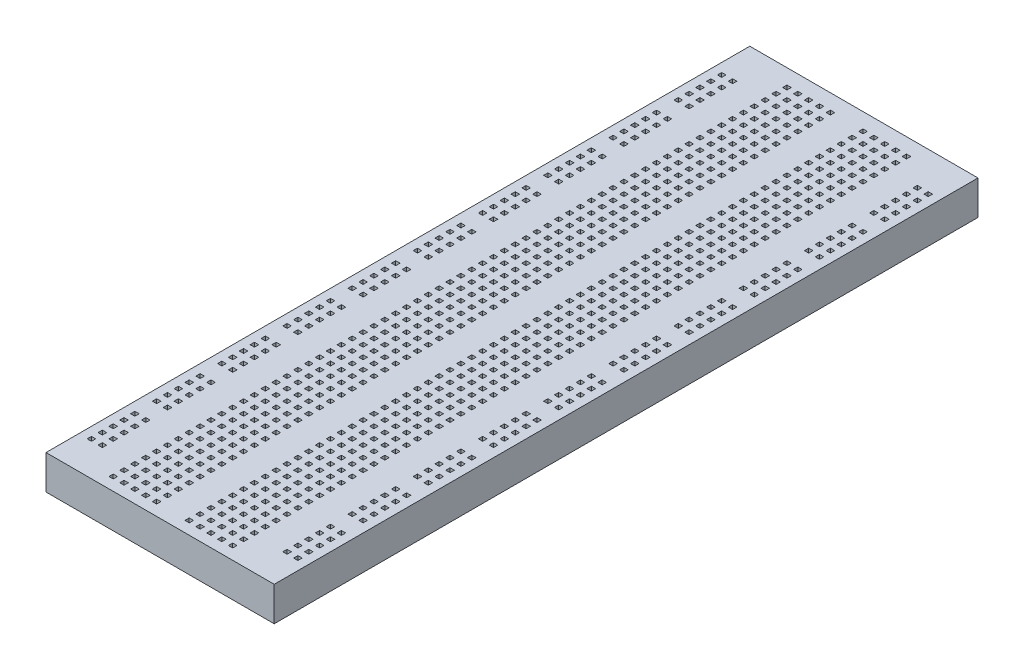
SolidWorks part; units mm, degrees
ref_plane "Спереди" through (0, 0, 0) normal (0, 0, 1) x (1, 0, 0)
ref_plane "Сверху" through (0, 0, 0) normal (0, 1, 0) x (1, 0, 0)
ref_plane "Справа" through (0, 0, 0) normal (1, 0, 0) x (0, 0, -1)
sketch "Эскиз1" plane through (0, 0, 0) normal (0, 1, 0) x (1, 0, 0)
  line L0 (15.74, 3.5) -> (14.74, 3.5)
  line L1 (0, 0) -> (53.34, 0)
  line L2 (0, 0) -> (0, 164.5)
  line L3 (0, 164.5) -> (53.34, 164.5)
  line L4 (53.34, 0) -> (53.34, 164.5)
  line L5 (13.2, 3.5) -> (12.2, 3.5)
  line L6 (13.2, 3.5) -> (13.2, 2.5)
  line L7 (13.2, 2.5) -> (12.2, 2.5)
  line L8 (12.2, 3.5) -> (12.2, 2.5)
  line L9 (13.2, 3.5) -> (12.2, 2.5) construction
  line L10 (13.2, 2.5) -> (12.2, 3.5) construction
  line L11 (15.74, 3.5) -> (15.74, 2.5)
  line L12 (15.74, 2.5) -> (14.74, 2.5)
  line L13 (14.74, 3.5) -> (14.74, 2.5)
  line L14 (15.74, 3.5) -> (14.74, 2.5) construction
  line L15 (15.74, 2.5) -> (14.74, 3.5) construction
  line L16 (18.28, 3.5) -> (17.28, 3.5)
  line L17 (18.28, 3.5) -> (18.28, 2.5)
  line L18 (18.28, 2.5) -> (17.28, 2.5)
  line L19 (17.28, 3.5) -> (17.28, 2.5)
  line L20 (18.28, 3.5) -> (17.28, 2.5) construction
  line L21 (18.28, 2.5) -> (17.28, 3.5) construction
  line L22 (20.82, 3.5) -> (19.82, 3.5)
  line L23 (20.82, 3.5) -> (20.82, 2.5)
  line L24 (20.82, 2.5) -> (19.82, 2.5)
  line L25 (19.82, 3.5) -> (19.82, 2.5)
  line L26 (20.82, 3.5) -> (19.82, 2.5) construction
  line L27 (20.82, 2.5) -> (19.82, 3.5) construction
  line L28 (23.36, 3.5) -> (22.36, 3.5)
  line L29 (23.36, 3.5) -> (23.36, 2.5)
  line L30 (23.36, 2.5) -> (22.36, 2.5)
  line L31 (22.36, 3.5) -> (22.36, 2.5)
  line L32 (23.36, 3.5) -> (22.36, 2.5) construction
  line L33 (23.36, 2.5) -> (22.36, 3.5) construction
  line L38 (15.74, 6.04) -> (14.74, 6.04)
  line L39 (13.2, 6.04) -> (12.2, 6.04)
  line L44 (13.2, 6.04) -> (13.2, 5.04)
  line L45 (13.2, 5.04) -> (12.2, 5.04)
  line L50 (12.2, 6.04) -> (12.2, 5.04)
  line L51 (15.74, 6.04) -> (15.74, 5.04)
  line L56 (15.74, 5.04) -> (14.74, 5.04)
  line L57 (14.74, 6.04) -> (14.74, 5.04)
  line L62 (18.28, 6.04) -> (17.28, 6.04)
  line L63 (18.28, 6.04) -> (18.28, 5.04)
  line L68 (18.28, 5.04) -> (17.28, 5.04)
  line L69 (17.28, 6.04) -> (17.28, 5.04)
  line L74 (20.82, 6.04) -> (19.82, 6.04)
  line L75 (20.82, 6.04) -> (20.82, 5.04)
  line L80 (20.82, 5.04) -> (19.82, 5.04)
  line L81 (19.82, 6.04) -> (19.82, 5.04)
  line L86 (23.36, 6.04) -> (22.36, 6.04)
  line L87 (23.36, 6.04) -> (23.36, 5.04)
  line L92 (23.36, 5.04) -> (22.36, 5.04)
  line L93 (22.36, 6.04) -> (22.36, 5.04)
  line L98 (13.2, 6.04) -> (12.2, 5.04) construction
  line L99 (13.2, 5.04) -> (12.2, 6.04) construction
  line L104 (15.74, 6.04) -> (14.74, 5.04) construction
  line L105 (15.74, 5.04) -> (14.74, 6.04) construction
  line L110 (18.28, 6.04) -> (17.28, 5.04) construction
  line L111 (18.28, 5.04) -> (17.28, 6.04) construction
  line L116 (20.82, 6.04) -> (19.82, 5.04) construction
  line L117 (20.82, 5.04) -> (19.82, 6.04) construction
  line L122 (23.36, 6.04) -> (22.36, 5.04) construction
  line L123 (23.36, 5.04) -> (22.36, 6.04) construction
  line L128 (15.74, 8.58) -> (14.74, 8.58)
  line L129 (13.2, 8.58) -> (12.2, 8.58)
  line L134 (13.2, 8.58) -> (13.2, 7.58)
  line L135 (13.2, 7.58) -> (12.2, 7.58)
  line L140 (12.2, 8.58) -> (12.2, 7.58)
  line L141 (15.74, 8.58) -> (15.74, 7.58)
  line L146 (15.74, 7.58) -> (14.74, 7.58)
  line L147 (14.74, 8.58) -> (14.74, 7.58)
  line L152 (18.28, 8.58) -> (17.28, 8.58)
  line L153 (18.28, 8.58) -> (18.28, 7.58)
  line L158 (18.28, 7.58) -> (17.28, 7.58)
  line L159 (17.28, 8.58) -> (17.28, 7.58)
  line L164 (20.82, 8.58) -> (19.82, 8.58)
  line L165 (20.82, 8.58) -> (20.82, 7.58)
  line L170 (20.82, 7.58) -> (19.82, 7.58)
  line L171 (19.82, 8.58) -> (19.82, 7.58)
  line L176 (23.36, 8.58) -> (22.36, 8.58)
  line L177 (23.36, 8.58) -> (23.36, 7.58)
  line L182 (23.36, 7.58) -> (22.36, 7.58)
  line L183 (22.36, 8.58) -> (22.36, 7.58)
  line L188 (13.2, 8.58) -> (12.2, 7.58) construction
  line L189 (13.2, 7.58) -> (12.2, 8.58) construction
  line L194 (15.74, 8.58) -> (14.74, 7.58) construction
  line L195 (15.74, 7.58) -> (14.74, 8.58) construction
  line L200 (18.28, 8.58) -> (17.28, 7.58) construction
  line L201 (18.28, 7.58) -> (17.28, 8.58) construction
  line L206 (20.82, 8.58) -> (19.82, 7.58) construction
  line L207 (20.82, 7.58) -> (19.82, 8.58) construction
  line L212 (23.36, 8.58) -> (22.36, 7.58) construction
  line L213 (23.36, 7.58) -> (22.36, 8.58) construction
  line L218 (15.74, 11.12) -> (14.74, 11.12)
  line L219 (13.2, 11.12) -> (12.2, 11.12)
  line L224 (13.2, 11.12) -> (13.2, 10.12)
  line L225 (13.2, 10.12) -> (12.2, 10.12)
  line L230 (12.2, 11.12) -> (12.2, 10.12)
  line L231 (15.74, 11.12) -> (15.74, 10.12)
  line L236 (15.74, 10.12) -> (14.74, 10.12)
  line L237 (14.74, 11.12) -> (14.74, 10.12)
  line L242 (18.28, 11.12) -> (17.28, 11.12)
  line L243 (18.28, 11.12) -> (18.28, 10.12)
  line L248 (18.28, 10.12) -> (17.28, 10.12)
  line L249 (17.28, 11.12) -> (17.28, 10.12)
  line L254 (20.82, 11.12) -> (19.82, 11.12)
  line L255 (20.82, 11.12) -> (20.82, 10.12)
  line L260 (20.82, 10.12) -> (19.82, 10.12)
  line L261 (19.82, 11.12) -> (19.82, 10.12)
  line L266 (23.36, 11.12) -> (22.36, 11.12)
  line L267 (23.36, 11.12) -> (23.36, 10.12)
  line L272 (23.36, 10.12) -> (22.36, 10.12)
  line L273 (22.36, 11.12) -> (22.36, 10.12)
  line L278 (13.2, 11.12) -> (12.2, 10.12) construction
  line L279 (13.2, 10.12) -> (12.2, 11.12) construction
  line L284 (15.74, 11.12) -> (14.74, 10.12) construction
  line L285 (15.74, 10.12) -> (14.74, 11.12) construction
  line L290 (18.28, 11.12) -> (17.28, 10.12) construction
  line L291 (18.28, 10.12) -> (17.28, 11.12) construction
  line L296 (20.82, 11.12) -> (19.82, 10.12) construction
  line L297 (20.82, 10.12) -> (19.82, 11.12) construction
  line L302 (23.36, 11.12) -> (22.36, 10.12) construction
  line L303 (23.36, 10.12) -> (22.36, 11.12) construction
  line L308 (15.74, 13.66) -> (14.74, 13.66)
  line L309 (13.2, 13.66) -> (12.2, 13.66)
  line L314 (13.2, 13.66) -> (13.2, 12.66)
  line L315 (13.2, 12.66) -> (12.2, 12.66)
  line L320 (12.2, 13.66) -> (12.2, 12.66)
  line L321 (15.74, 13.66) -> (15.74, 12.66)
  line L326 (15.74, 12.66) -> (14.74, 12.66)
  line L327 (14.74, 13.66) -> (14.74, 12.66)
  line L332 (18.28, 13.66) -> (17.28, 13.66)
  line L333 (18.28, 13.66) -> (18.28, 12.66)
  line L338 (18.28, 12.66) -> (17.28, 12.66)
  line L339 (17.28, 13.66) -> (17.28, 12.66)
  line L344 (20.82, 13.66) -> (19.82, 13.66)
  line L345 (20.82, 13.66) -> (20.82, 12.66)
  line L350 (20.82, 12.66) -> (19.82, 12.66)
  line L351 (19.82, 13.66) -> (19.82, 12.66)
  line L356 (23.36, 13.66) -> (22.36, 13.66)
  line L357 (23.36, 13.66) -> (23.36, 12.66)
  line L362 (23.36, 12.66) -> (22.36, 12.66)
  line L363 (22.36, 13.66) -> (22.36, 12.66)
  line L368 (13.2, 13.66) -> (12.2, 12.66) construction
  line L369 (13.2, 12.66) -> (12.2, 13.66) construction
  line L374 (15.74, 13.66) -> (14.74, 12.66) construction
  line L375 (15.74, 12.66) -> (14.74, 13.66) construction
  line L380 (18.28, 13.66) -> (17.28, 12.66) construction
  line L381 (18.28, 12.66) -> (17.28, 13.66) construction
  line L386 (20.82, 13.66) -> (19.82, 12.66) construction
  line L387 (20.82, 12.66) -> (19.82, 13.66) construction
  line L392 (23.36, 13.66) -> (22.36, 12.66) construction
  line L393 (23.36, 12.66) -> (22.36, 13.66) construction
  line L398 (15.74, 16.2) -> (14.74, 16.2)
  line L399 (13.2, 16.2) -> (12.2, 16.2)
  line L404 (13.2, 16.2) -> (13.2, 15.2)
  line L405 (13.2, 15.2) -> (12.2, 15.2)
  line L410 (12.2, 16.2) -> (12.2, 15.2)
  line L411 (15.74, 16.2) -> (15.74, 15.2)
  line L416 (15.74, 15.2) -> (14.74, 15.2)
  line L417 (14.74, 16.2) -> (14.74, 15.2)
  line L422 (18.28, 16.2) -> (17.28, 16.2)
  line L423 (18.28, 16.2) -> (18.28, 15.2)
  line L428 (18.28, 15.2) -> (17.28, 15.2)
  line L429 (17.28, 16.2) -> (17.28, 15.2)
  line L434 (20.82, 16.2) -> (19.82, 16.2)
  line L435 (20.82, 16.2) -> (20.82, 15.2)
  line L440 (20.82, 15.2) -> (19.82, 15.2)
  line L441 (19.82, 16.2) -> (19.82, 15.2)
  line L446 (23.36, 16.2) -> (22.36, 16.2)
  line L447 (23.36, 16.2) -> (23.36, 15.2)
  line L452 (23.36, 15.2) -> (22.36, 15.2)
  line L453 (22.36, 16.2) -> (22.36, 15.2)
  line L458 (13.2, 16.2) -> (12.2, 15.2) construction
  line L459 (13.2, 15.2) -> (12.2, 16.2) construction
  line L464 (15.74, 16.2) -> (14.74, 15.2) construction
  line L465 (15.74, 15.2) -> (14.74, 16.2) construction
  line L470 (18.28, 16.2) -> (17.28, 15.2) construction
  line L471 (18.28, 15.2) -> (17.28, 16.2) construction
  line L476 (20.82, 16.2) -> (19.82, 15.2) construction
  line L477 (20.82, 15.2) -> (19.82, 16.2) construction
  line L482 (23.36, 16.2) -> (22.36, 15.2) construction
  line L483 (23.36, 15.2) -> (22.36, 16.2) construction
  line L488 (15.74, 18.74) -> (14.74, 18.74)
  line L489 (13.2, 18.74) -> (12.2, 18.74)
  line L494 (13.2, 18.74) -> (13.2, 17.74)
  line L495 (13.2, 17.74) -> (12.2, 17.74)
  line L500 (12.2, 18.74) -> (12.2, 17.74)
  line L501 (15.74, 18.74) -> (15.74, 17.74)
  line L506 (15.74, 17.74) -> (14.74, 17.74)
  line L507 (14.74, 18.74) -> (14.74, 17.74)
  line L512 (18.28, 18.74) -> (17.28, 18.74)
  line L513 (18.28, 18.74) -> (18.28, 17.74)
  line L518 (18.28, 17.74) -> (17.28, 17.74)
  line L519 (17.28, 18.74) -> (17.28, 17.74)
  line L524 (20.82, 18.74) -> (19.82, 18.74)
  line L525 (20.82, 18.74) -> (20.82, 17.74)
  line L530 (20.82, 17.74) -> (19.82, 17.74)
  line L531 (19.82, 18.74) -> (19.82, 17.74)
  line L536 (23.36, 18.74) -> (22.36, 18.74)
  line L537 (23.36, 18.74) -> (23.36, 17.74)
  line L542 (23.36, 17.74) -> (22.36, 17.74)
  line L543 (22.36, 18.74) -> (22.36, 17.74)
  line L548 (13.2, 18.74) -> (12.2, 17.74) construction
  line L549 (13.2, 17.74) -> (12.2, 18.74) construction
  line L554 (15.74, 18.74) -> (14.74, 17.74) construction
  line L555 (15.74, 17.74) -> (14.74, 18.74) construction
  line L560 (18.28, 18.74) -> (17.28, 17.74) construction
  line L561 (18.28, 17.74) -> (17.28, 18.74) construction
  line L566 (20.82, 18.74) -> (19.82, 17.74) construction
  line L567 (20.82, 17.74) -> (19.82, 18.74) construction
  line L572 (23.36, 18.74) -> (22.36, 17.74) construction
  line L573 (23.36, 17.74) -> (22.36, 18.74) construction
  line L578 (15.74, 21.28) -> (14.74, 21.28)
  line L579 (13.2, 21.28) -> (12.2, 21.28)
  line L584 (13.2, 21.28) -> (13.2, 20.28)
  line L585 (13.2, 20.28) -> (12.2, 20.28)
  line L590 (12.2, 21.28) -> (12.2, 20.28)
  line L591 (15.74, 21.28) -> (15.74, 20.28)
  line L596 (15.74, 20.28) -> (14.74, 20.28)
  line L597 (14.74, 21.28) -> (14.74, 20.28)
  line L602 (18.28, 21.28) -> (17.28, 21.28)
  line L603 (18.28, 21.28) -> (18.28, 20.28)
  line L608 (18.28, 20.28) -> (17.28, 20.28)
  line L609 (17.28, 21.28) -> (17.28, 20.28)
  line L614 (20.82, 21.28) -> (19.82, 21.28)
  line L615 (20.82, 21.28) -> (20.82, 20.28)
  line L620 (20.82, 20.28) -> (19.82, 20.28)
  line L621 (19.82, 21.28) -> (19.82, 20.28)
  line L626 (23.36, 21.28) -> (22.36, 21.28)
  line L627 (23.36, 21.28) -> (23.36, 20.28)
  line L632 (23.36, 20.28) -> (22.36, 20.28)
  line L633 (22.36, 21.28) -> (22.36, 20.28)
  line L638 (13.2, 21.28) -> (12.2, 20.28) construction
  line L639 (13.2, 20.28) -> (12.2, 21.28) construction
  line L644 (15.74, 21.28) -> (14.74, 20.28) construction
  line L645 (15.74, 20.28) -> (14.74, 21.28) construction
  line L650 (18.28, 21.28) -> (17.28, 20.28) construction
  line L651 (18.28, 20.28) -> (17.28, 21.28) construction
  line L656 (20.82, 21.28) -> (19.82, 20.28) construction
  line L657 (20.82, 20.28) -> (19.82, 21.28) construction
  line L662 (23.36, 21.28) -> (22.36, 20.28) construction
  line L663 (23.36, 20.28) -> (22.36, 21.28) construction
  line L668 (15.74, 23.82) -> (14.74, 23.82)
  line L669 (13.2, 23.82) -> (12.2, 23.82)
  line L674 (13.2, 23.82) -> (13.2, 22.82)
  line L675 (13.2, 22.82) -> (12.2, 22.82)
  line L680 (12.2, 23.82) -> (12.2, 22.82)
  line L681 (15.74, 23.82) -> (15.74, 22.82)
  line L686 (15.74, 22.82) -> (14.74, 22.82)
  line L687 (14.74, 23.82) -> (14.74, 22.82)
  line L692 (18.28, 23.82) -> (17.28, 23.82)
  line L693 (18.28, 23.82) -> (18.28, 22.82)
  line L698 (18.28, 22.82) -> (17.28, 22.82)
  line L699 (17.28, 23.82) -> (17.28, 22.82)
  line L704 (20.82, 23.82) -> (19.82, 23.82)
  line L705 (20.82, 23.82) -> (20.82, 22.82)
  line L710 (20.82, 22.82) -> (19.82, 22.82)
  line L711 (19.82, 23.82) -> (19.82, 22.82)
  line L716 (23.36, 23.82) -> (22.36, 23.82)
  line L717 (23.36, 23.82) -> (23.36, 22.82)
  line L722 (23.36, 22.82) -> (22.36, 22.82)
  line L723 (22.36, 23.82) -> (22.36, 22.82)
  line L728 (13.2, 23.82) -> (12.2, 22.82) construction
  line L729 (13.2, 22.82) -> (12.2, 23.82) construction
  line L734 (15.74, 23.82) -> (14.74, 22.82) construction
  line L735 (15.74, 22.82) -> (14.74, 23.82) construction
  line L740 (18.28, 23.82) -> (17.28, 22.82) construction
  line L741 (18.28, 22.82) -> (17.28, 23.82) construction
  line L746 (20.82, 23.82) -> (19.82, 22.82) construction
  line L747 (20.82, 22.82) -> (19.82, 23.82) construction
  line L752 (23.36, 23.82) -> (22.36, 22.82) construction
  line L753 (23.36, 22.82) -> (22.36, 23.82) construction
  line L758 (15.74, 26.36) -> (14.74, 26.36)
  line L759 (13.2, 26.36) -> (12.2, 26.36)
  line L764 (13.2, 26.36) -> (13.2, 25.36)
  line L765 (13.2, 25.36) -> (12.2, 25.36)
  line L770 (12.2, 26.36) -> (12.2, 25.36)
  line L771 (15.74, 26.36) -> (15.74, 25.36)
  line L776 (15.74, 25.36) -> (14.74, 25.36)
  line L777 (14.74, 26.36) -> (14.74, 25.36)
  line L782 (18.28, 26.36) -> (17.28, 26.36)
  line L783 (18.28, 26.36) -> (18.28, 25.36)
  line L788 (18.28, 25.36) -> (17.28, 25.36)
  line L789 (17.28, 26.36) -> (17.28, 25.36)
  line L794 (20.82, 26.36) -> (19.82, 26.36)
  line L795 (20.82, 26.36) -> (20.82, 25.36)
  line L800 (20.82, 25.36) -> (19.82, 25.36)
  line L801 (19.82, 26.36) -> (19.82, 25.36)
  line L806 (23.36, 26.36) -> (22.36, 26.36)
  line L807 (23.36, 26.36) -> (23.36, 25.36)
  line L812 (23.36, 25.36) -> (22.36, 25.36)
  line L813 (22.36, 26.36) -> (22.36, 25.36)
  line L818 (13.2, 26.36) -> (12.2, 25.36) construction
  line L819 (13.2, 25.36) -> (12.2, 26.36) construction
  line L824 (15.74, 26.36) -> (14.74, 25.36) construction
  line L825 (15.74, 25.36) -> (14.74, 26.36) construction
  line L830 (18.28, 26.36) -> (17.28, 25.36) construction
  line L831 (18.28, 25.36) -> (17.28, 26.36) construction
  line L836 (20.82, 26.36) -> (19.82, 25.36) construction
  line L837 (20.82, 25.36) -> (19.82, 26.36) construction
  line L842 (23.36, 26.36) -> (22.36, 25.36) construction
  line L843 (23.36, 25.36) -> (22.36, 26.36) construction
  line L848 (15.74, 28.9) -> (14.74, 28.9)
  line L849 (13.2, 28.9) -> (12.2, 28.9)
  line L854 (13.2, 28.9) -> (13.2, 27.9)
  line L855 (13.2, 27.9) -> (12.2, 27.9)
  line L860 (12.2, 28.9) -> (12.2, 27.9)
  line L861 (15.74, 28.9) -> (15.74, 27.9)
  line L866 (15.74, 27.9) -> (14.74, 27.9)
  line L867 (14.74, 28.9) -> (14.74, 27.9)
  line L872 (18.28, 28.9) -> (17.28, 28.9)
  line L873 (18.28, 28.9) -> (18.28, 27.9)
  line L878 (18.28, 27.9) -> (17.28, 27.9)
  line L879 (17.28, 28.9) -> (17.28, 27.9)
  line L884 (20.82, 28.9) -> (19.82, 28.9)
  line L885 (20.82, 28.9) -> (20.82, 27.9)
  line L890 (20.82, 27.9) -> (19.82, 27.9)
  line L891 (19.82, 28.9) -> (19.82, 27.9)
  line L896 (23.36, 28.9) -> (22.36, 28.9)
  line L897 (23.36, 28.9) -> (23.36, 27.9)
  line L902 (23.36, 27.9) -> (22.36, 27.9)
  line L903 (22.36, 28.9) -> (22.36, 27.9)
  line L908 (13.2, 28.9) -> (12.2, 27.9) construction
  line L909 (13.2, 27.9) -> (12.2, 28.9) construction
  line L914 (15.74, 28.9) -> (14.74, 27.9) construction
  line L915 (15.74, 27.9) -> (14.74, 28.9) construction
  line L920 (18.28, 28.9) -> (17.28, 27.9) construction
  line L921 (18.28, 27.9) -> (17.28, 28.9) construction
  line L926 (20.82, 28.9) -> (19.82, 27.9) construction
  line L927 (20.82, 27.9) -> (19.82, 28.9) construction
  line L932 (23.36, 28.9) -> (22.36, 27.9) construction
  line L933 (23.36, 27.9) -> (22.36, 28.9) construction
  line L938 (15.74, 31.44) -> (14.74, 31.44)
  line L939 (13.2, 31.44) -> (12.2, 31.44)
  line L944 (13.2, 31.44) -> (13.2, 30.44)
  line L945 (13.2, 30.44) -> (12.2, 30.44)
  line L950 (12.2, 31.44) -> (12.2, 30.44)
  line L951 (15.74, 31.44) -> (15.74, 30.44)
  line L956 (15.74, 30.44) -> (14.74, 30.44)
  line L957 (14.74, 31.44) -> (14.74, 30.44)
  line L962 (18.28, 31.44) -> (17.28, 31.44)
  line L963 (18.28, 31.44) -> (18.28, 30.44)
  line L968 (18.28, 30.44) -> (17.28, 30.44)
  line L969 (17.28, 31.44) -> (17.28, 30.44)
  line L974 (20.82, 31.44) -> (19.82, 31.44)
  line L975 (20.82, 31.44) -> (20.82, 30.44)
  line L980 (20.82, 30.44) -> (19.82, 30.44)
  line L981 (19.82, 31.44) -> (19.82, 30.44)
  line L986 (23.36, 31.44) -> (22.36, 31.44)
  line L987 (23.36, 31.44) -> (23.36, 30.44)
  line L992 (23.36, 30.44) -> (22.36, 30.44)
  line L993 (22.36, 31.44) -> (22.36, 30.44)
  line L998 (13.2, 31.44) -> (12.2, 30.44) construction
  line L999 (13.2, 30.44) -> (12.2, 31.44) construction
  line L1004 (15.74, 31.44) -> (14.74, 30.44) construction
  line L1005 (15.74, 30.44) -> (14.74, 31.44) construction
  line L1010 (18.28, 31.44) -> (17.28, 30.44) construction
  line L1011 (18.28, 30.44) -> (17.28, 31.44) construction
  line L1016 (20.82, 31.44) -> (19.82, 30.44) construction
  line L1017 (20.82, 30.44) -> (19.82, 31.44) construction
  line L1022 (23.36, 31.44) -> (22.36, 30.44) construction
  line L1023 (23.36, 30.44) -> (22.36, 31.44) construction
  line L1028 (15.74, 33.98) -> (14.74, 33.98)
  line L1029 (13.2, 33.98) -> (12.2, 33.98)
  line L1034 (13.2, 33.98) -> (13.2, 32.98)
  line L1035 (13.2, 32.98) -> (12.2, 32.98)
  line L1040 (12.2, 33.98) -> (12.2, 32.98)
  line L1041 (15.74, 33.98) -> (15.74, 32.98)
  line L1046 (15.74, 32.98) -> (14.74, 32.98)
  line L1047 (14.74, 33.98) -> (14.74, 32.98)
  line L1052 (18.28, 33.98) -> (17.28, 33.98)
  line L1053 (18.28, 33.98) -> (18.28, 32.98)
  line L1058 (18.28, 32.98) -> (17.28, 32.98)
  line L1059 (17.28, 33.98) -> (17.28, 32.98)
  line L1064 (20.82, 33.98) -> (19.82, 33.98)
  line L1065 (20.82, 33.98) -> (20.82, 32.98)
  line L1070 (20.82, 32.98) -> (19.82, 32.98)
  line L1071 (19.82, 33.98) -> (19.82, 32.98)
  line L1076 (23.36, 33.98) -> (22.36, 33.98)
  line L1077 (23.36, 33.98) -> (23.36, 32.98)
  line L1082 (23.36, 32.98) -> (22.36, 32.98)
  line L1083 (22.36, 33.98) -> (22.36, 32.98)
  line L1088 (13.2, 33.98) -> (12.2, 32.98) construction
  line L1089 (13.2, 32.98) -> (12.2, 33.98) construction
  line L1094 (15.74, 33.98) -> (14.74, 32.98) construction
  line L1095 (15.74, 32.98) -> (14.74, 33.98) construction
  line L1100 (18.28, 33.98) -> (17.28, 32.98) construction
  line L1101 (18.28, 32.98) -> (17.28, 33.98) construction
  line L1106 (20.82, 33.98) -> (19.82, 32.98) construction
  line L1107 (20.82, 32.98) -> (19.82, 33.98) construction
  line L1112 (23.36, 33.98) -> (22.36, 32.98) construction
  line L1113 (23.36, 32.98) -> (22.36, 33.98) construction
  line L1118 (15.74, 36.52) -> (14.74, 36.52)
  line L1119 (13.2, 36.52) -> (12.2, 36.52)
  line L1124 (13.2, 36.52) -> (13.2, 35.52)
  line L1125 (13.2, 35.52) -> (12.2, 35.52)
  line L1130 (12.2, 36.52) -> (12.2, 35.52)
  line L1131 (15.74, 36.52) -> (15.74, 35.52)
  line L1136 (15.74, 35.52) -> (14.74, 35.52)
  line L1137 (14.74, 36.52) -> (14.74, 35.52)
  line L1142 (18.28, 36.52) -> (17.28, 36.52)
  line L1143 (18.28, 36.52) -> (18.28, 35.52)
  line L1148 (18.28, 35.52) -> (17.28, 35.52)
  line L1149 (17.28, 36.52) -> (17.28, 35.52)
  line L1154 (20.82, 36.52) -> (19.82, 36.52)
  line L1155 (20.82, 36.52) -> (20.82, 35.52)
  line L1160 (20.82, 35.52) -> (19.82, 35.52)
  line L1161 (19.82, 36.52) -> (19.82, 35.52)
  line L1166 (23.36, 36.52) -> (22.36, 36.52)
  line L1167 (23.36, 36.52) -> (23.36, 35.52)
  line L1172 (23.36, 35.52) -> (22.36, 35.52)
  line L1173 (22.36, 36.52) -> (22.36, 35.52)
  line L1178 (13.2, 36.52) -> (12.2, 35.52) construction
  line L1179 (13.2, 35.52) -> (12.2, 36.52) construction
  line L1184 (15.74, 36.52) -> (14.74, 35.52) construction
  line L1185 (15.74, 35.52) -> (14.74, 36.52) construction
  line L1190 (18.28, 36.52) -> (17.28, 35.52) construction
  line L1191 (18.28, 35.52) -> (17.28, 36.52) construction
  line L1196 (20.82, 36.52) -> (19.82, 35.52) construction
  line L1197 (20.82, 35.52) -> (19.82, 36.52) construction
  line L1202 (23.36, 36.52) -> (22.36, 35.52) construction
  line L1203 (23.36, 35.52) -> (22.36, 36.52) construction
  line L1208 (15.74, 39.06) -> (14.74, 39.06)
  line L1209 (13.2, 39.06) -> (12.2, 39.06)
  line L1214 (13.2, 39.06) -> (13.2, 38.06)
  line L1215 (13.2, 38.06) -> (12.2, 38.06)
  line L1220 (12.2, 39.06) -> (12.2, 38.06)
  line L1221 (15.74, 39.06) -> (15.74, 38.06)
  line L1226 (15.74, 38.06) -> (14.74, 38.06)
  line L1227 (14.74, 39.06) -> (14.74, 38.06)
  line L1232 (18.28, 39.06) -> (17.28, 39.06)
  line L1233 (18.28, 39.06) -> (18.28, 38.06)
  line L1238 (18.28, 38.06) -> (17.28, 38.06)
  line L1239 (17.28, 39.06) -> (17.28, 38.06)
  line L1244 (20.82, 39.06) -> (19.82, 39.06)
  line L1245 (20.82, 39.06) -> (20.82, 38.06)
  line L1250 (20.82, 38.06) -> (19.82, 38.06)
  line L1251 (19.82, 39.06) -> (19.82, 38.06)
  line L1256 (23.36, 39.06) -> (22.36, 39.06)
  line L1257 (23.36, 39.06) -> (23.36, 38.06)
  line L1262 (23.36, 38.06) -> (22.36, 38.06)
  line L1263 (22.36, 39.06) -> (22.36, 38.06)
  line L1268 (13.2, 39.06) -> (12.2, 38.06) construction
  line L1269 (13.2, 38.06) -> (12.2, 39.06) construction
  line L1274 (15.74, 39.06) -> (14.74, 38.06) construction
  line L1275 (15.74, 38.06) -> (14.74, 39.06) construction
  line L1280 (18.28, 39.06) -> (17.28, 38.06) construction
  line L1281 (18.28, 38.06) -> (17.28, 39.06) construction
  line L1286 (20.82, 39.06) -> (19.82, 38.06) construction
  line L1287 (20.82, 38.06) -> (19.82, 39.06) construction
  line L1292 (23.36, 39.06) -> (22.36, 38.06) construction
  line L1293 (23.36, 38.06) -> (22.36, 39.06) construction
  line L1298 (15.74, 41.6) -> (14.74, 41.6)
  line L1299 (13.2, 41.6) -> (12.2, 41.6)
  line L1304 (13.2, 41.6) -> (13.2, 40.6)
  line L1305 (13.2, 40.6) -> (12.2, 40.6)
  line L1310 (12.2, 41.6) -> (12.2, 40.6)
  line L1311 (15.74, 41.6) -> (15.74, 40.6)
  line L1316 (15.74, 40.6) -> (14.74, 40.6)
  line L1317 (14.74, 41.6) -> (14.74, 40.6)
  line L1322 (18.28, 41.6) -> (17.28, 41.6)
  line L1323 (18.28, 41.6) -> (18.28, 40.6)
  line L1328 (18.28, 40.6) -> (17.28, 40.6)
  line L1329 (17.28, 41.6) -> (17.28, 40.6)
  line L1334 (20.82, 41.6) -> (19.82, 41.6)
  line L1335 (20.82, 41.6) -> (20.82, 40.6)
  line L1340 (20.82, 40.6) -> (19.82, 40.6)
  line L1341 (19.82, 41.6) -> (19.82, 40.6)
  line L1346 (23.36, 41.6) -> (22.36, 41.6)
  line L1347 (23.36, 41.6) -> (23.36, 40.6)
  line L1352 (23.36, 40.6) -> (22.36, 40.6)
  line L1353 (22.36, 41.6) -> (22.36, 40.6)
  line L1358 (13.2, 41.6) -> (12.2, 40.6) construction
  line L1359 (13.2, 40.6) -> (12.2, 41.6) construction
  line L1364 (15.74, 41.6) -> (14.74, 40.6) construction
  line L1365 (15.74, 40.6) -> (14.74, 41.6) construction
  line L1370 (18.28, 41.6) -> (17.28, 40.6) construction
  line L1371 (18.28, 40.6) -> (17.28, 41.6) construction
  line L1376 (20.82, 41.6) -> (19.82, 40.6) construction
  line L1377 (20.82, 40.6) -> (19.82, 41.6) construction
  line L1382 (23.36, 41.6) -> (22.36, 40.6) construction
  line L1383 (23.36, 40.6) -> (22.36, 41.6) construction
  line L1388 (15.74, 44.14) -> (14.74, 44.14)
  line L1389 (13.2, 44.14) -> (12.2, 44.14)
  line L1394 (13.2, 44.14) -> (13.2, 43.14)
  line L1395 (13.2, 43.14) -> (12.2, 43.14)
  line L1400 (12.2, 44.14) -> (12.2, 43.14)
  line L1401 (15.74, 44.14) -> (15.74, 43.14)
  line L1406 (15.74, 43.14) -> (14.74, 43.14)
  line L1407 (14.74, 44.14) -> (14.74, 43.14)
  line L1412 (18.28, 44.14) -> (17.28, 44.14)
  line L1413 (18.28, 44.14) -> (18.28, 43.14)
  line L1418 (18.28, 43.14) -> (17.28, 43.14)
  line L1419 (17.28, 44.14) -> (17.28, 43.14)
  line L1424 (20.82, 44.14) -> (19.82, 44.14)
  line L1425 (20.82, 44.14) -> (20.82, 43.14)
  line L1430 (20.82, 43.14) -> (19.82, 43.14)
  line L1431 (19.82, 44.14) -> (19.82, 43.14)
  line L1436 (23.36, 44.14) -> (22.36, 44.14)
  line L1437 (23.36, 44.14) -> (23.36, 43.14)
  line L1442 (23.36, 43.14) -> (22.36, 43.14)
  line L1443 (22.36, 44.14) -> (22.36, 43.14)
  line L1448 (13.2, 44.14) -> (12.2, 43.14) construction
  line L1449 (13.2, 43.14) -> (12.2, 44.14) construction
  line L1454 (15.74, 44.14) -> (14.74, 43.14) construction
  line L1455 (15.74, 43.14) -> (14.74, 44.14) construction
  line L1460 (18.28, 44.14) -> (17.28, 43.14) construction
  line L1461 (18.28, 43.14) -> (17.28, 44.14) construction
  line L1466 (20.82, 44.14) -> (19.82, 43.14) construction
  line L1467 (20.82, 43.14) -> (19.82, 44.14) construction
  line L1472 (23.36, 44.14) -> (22.36, 43.14) construction
  line L1473 (23.36, 43.14) -> (22.36, 44.14) construction
  line L1478 (15.74, 46.68) -> (14.74, 46.68)
  line L1479 (13.2, 46.68) -> (12.2, 46.68)
  line L1484 (13.2, 46.68) -> (13.2, 45.68)
  line L1485 (13.2, 45.68) -> (12.2, 45.68)
  line L1490 (12.2, 46.68) -> (12.2, 45.68)
  line L1491 (15.74, 46.68) -> (15.74, 45.68)
  line L1496 (15.74, 45.68) -> (14.74, 45.68)
  line L1497 (14.74, 46.68) -> (14.74, 45.68)
  line L1502 (18.28, 46.68) -> (17.28, 46.68)
  line L1503 (18.28, 46.68) -> (18.28, 45.68)
  line L1508 (18.28, 45.68) -> (17.28, 45.68)
  line L1509 (17.28, 46.68) -> (17.28, 45.68)
  line L1514 (20.82, 46.68) -> (19.82, 46.68)
  line L1515 (20.82, 46.68) -> (20.82, 45.68)
  line L1520 (20.82, 45.68) -> (19.82, 45.68)
  line L1521 (19.82, 46.68) -> (19.82, 45.68)
  line L1526 (23.36, 46.68) -> (22.36, 46.68)
  line L1527 (23.36, 46.68) -> (23.36, 45.68)
  line L1532 (23.36, 45.68) -> (22.36, 45.68)
  line L1533 (22.36, 46.68) -> (22.36, 45.68)
  line L1538 (13.2, 46.68) -> (12.2, 45.68) construction
  line L1539 (13.2, 45.68) -> (12.2, 46.68) construction
  line L1544 (15.74, 46.68) -> (14.74, 45.68) construction
  line L1545 (15.74, 45.68) -> (14.74, 46.68) construction
  line L1550 (18.28, 46.68) -> (17.28, 45.68) construction
  line L1551 (18.28, 45.68) -> (17.28, 46.68) construction
  line L1556 (20.82, 46.68) -> (19.82, 45.68) construction
  line L1557 (20.82, 45.68) -> (19.82, 46.68) construction
  line L1562 (23.36, 46.68) -> (22.36, 45.68) construction
  line L1563 (23.36, 45.68) -> (22.36, 46.68) construction
  line L1568 (15.74, 49.22) -> (14.74, 49.22)
  line L1569 (13.2, 49.22) -> (12.2, 49.22)
  line L1574 (13.2, 49.22) -> (13.2, 48.22)
  line L1575 (13.2, 48.22) -> (12.2, 48.22)
  line L1580 (12.2, 49.22) -> (12.2, 48.22)
  line L1581 (15.74, 49.22) -> (15.74, 48.22)
  line L1586 (15.74, 48.22) -> (14.74, 48.22)
  line L1587 (14.74, 49.22) -> (14.74, 48.22)
  line L1592 (18.28, 49.22) -> (17.28, 49.22)
  line L1593 (18.28, 49.22) -> (18.28, 48.22)
  line L1598 (18.28, 48.22) -> (17.28, 48.22)
  line L1599 (17.28, 49.22) -> (17.28, 48.22)
  line L1604 (20.82, 49.22) -> (19.82, 49.22)
  line L1605 (20.82, 49.22) -> (20.82, 48.22)
  line L1610 (20.82, 48.22) -> (19.82, 48.22)
  line L1611 (19.82, 49.22) -> (19.82, 48.22)
  line L1616 (23.36, 49.22) -> (22.36, 49.22)
  line L1617 (23.36, 49.22) -> (23.36, 48.22)
  line L1622 (23.36, 48.22) -> (22.36, 48.22)
  line L1623 (22.36, 49.22) -> (22.36, 48.22)
  line L1628 (13.2, 49.22) -> (12.2, 48.22) construction
  line L1629 (13.2, 48.22) -> (12.2, 49.22) construction
  line L1634 (15.74, 49.22) -> (14.74, 48.22) construction
  line L1635 (15.74, 48.22) -> (14.74, 49.22) construction
  line L1640 (18.28, 49.22) -> (17.28, 48.22) construction
  line L1641 (18.28, 48.22) -> (17.28, 49.22) construction
  line L1646 (20.82, 49.22) -> (19.82, 48.22) construction
  line L1647 (20.82, 48.22) -> (19.82, 49.22) construction
  line L1652 (23.36, 49.22) -> (22.36, 48.22) construction
  line L1653 (23.36, 48.22) -> (22.36, 49.22) construction
  line L1658 (15.74, 51.76) -> (14.74, 51.76)
  line L1659 (13.2, 51.76) -> (12.2, 51.76)
  line L1664 (13.2, 51.76) -> (13.2, 50.76)
  line L1665 (13.2, 50.76) -> (12.2, 50.76)
  line L1670 (12.2, 51.76) -> (12.2, 50.76)
  line L1671 (15.74, 51.76) -> (15.74, 50.76)
  line L1676 (15.74, 50.76) -> (14.74, 50.76)
  line L1677 (14.74, 51.76) -> (14.74, 50.76)
  line L1682 (18.28, 51.76) -> (17.28, 51.76)
  line L1683 (18.28, 51.76) -> (18.28, 50.76)
  line L1688 (18.28, 50.76) -> (17.28, 50.76)
  line L1689 (17.28, 51.76) -> (17.28, 50.76)
  line L1694 (20.82, 51.76) -> (19.82, 51.76)
  line L1695 (20.82, 51.76) -> (20.82, 50.76)
  line L1700 (20.82, 50.76) -> (19.82, 50.76)
  line L1701 (19.82, 51.76) -> (19.82, 50.76)
  line L1706 (23.36, 51.76) -> (22.36, 51.76)
  line L1707 (23.36, 51.76) -> (23.36, 50.76)
  line L1712 (23.36, 50.76) -> (22.36, 50.76)
  line L1713 (22.36, 51.76) -> (22.36, 50.76)
  line L1718 (13.2, 51.76) -> (12.2, 50.76) construction
  line L1719 (13.2, 50.76) -> (12.2, 51.76) construction
  line L1724 (15.74, 51.76) -> (14.74, 50.76) construction
  line L1725 (15.74, 50.76) -> (14.74, 51.76) construction
  line L1730 (18.28, 51.76) -> (17.28, 50.76) construction
  line L1731 (18.28, 50.76) -> (17.28, 51.76) construction
  line L1736 (20.82, 51.76) -> (19.82, 50.76) construction
  line L1737 (20.82, 50.76) -> (19.82, 51.76) construction
  line L1742 (23.36, 51.76) -> (22.36, 50.76) construction
  line L1743 (23.36, 50.76) -> (22.36, 51.76) construction
  line L1748 (15.74, 54.3) -> (14.74, 54.3)
  line L1749 (13.2, 54.3) -> (12.2, 54.3)
  line L1754 (13.2, 54.3) -> (13.2, 53.3)
  line L1755 (13.2, 53.3) -> (12.2, 53.3)
  line L1760 (12.2, 54.3) -> (12.2, 53.3)
  line L1761 (15.74, 54.3) -> (15.74, 53.3)
  line L1766 (15.74, 53.3) -> (14.74, 53.3)
  line L1767 (14.74, 54.3) -> (14.74, 53.3)
  line L1772 (18.28, 54.3) -> (17.28, 54.3)
  line L1773 (18.28, 54.3) -> (18.28, 53.3)
  line L1778 (18.28, 53.3) -> (17.28, 53.3)
  line L1779 (17.28, 54.3) -> (17.28, 53.3)
  line L1784 (20.82, 54.3) -> (19.82, 54.3)
  line L1785 (20.82, 54.3) -> (20.82, 53.3)
  line L1790 (20.82, 53.3) -> (19.82, 53.3)
  line L1791 (19.82, 54.3) -> (19.82, 53.3)
  line L1796 (23.36, 54.3) -> (22.36, 54.3)
  line L1797 (23.36, 54.3) -> (23.36, 53.3)
  line L1802 (23.36, 53.3) -> (22.36, 53.3)
  line L1803 (22.36, 54.3) -> (22.36, 53.3)
  line L1808 (13.2, 54.3) -> (12.2, 53.3) construction
  line L1809 (13.2, 53.3) -> (12.2, 54.3) construction
  line L1814 (15.74, 54.3) -> (14.74, 53.3) construction
  line L1815 (15.74, 53.3) -> (14.74, 54.3) construction
  line L1820 (18.28, 54.3) -> (17.28, 53.3) construction
  line L1821 (18.28, 53.3) -> (17.28, 54.3) construction
  line L1826 (20.82, 54.3) -> (19.82, 53.3) construction
  line L1827 (20.82, 53.3) -> (19.82, 54.3) construction
  line L1832 (23.36, 54.3) -> (22.36, 53.3) construction
  line L1833 (23.36, 53.3) -> (22.36, 54.3) construction
  line L1838 (15.74, 56.84) -> (14.74, 56.84)
  line L1839 (13.2, 56.84) -> (12.2, 56.84)
  line L1844 (13.2, 56.84) -> (13.2, 55.84)
  line L1845 (13.2, 55.84) -> (12.2, 55.84)
  line L1850 (12.2, 56.84) -> (12.2, 55.84)
  line L1851 (15.74, 56.84) -> (15.74, 55.84)
  line L1856 (15.74, 55.84) -> (14.74, 55.84)
  line L1857 (14.74, 56.84) -> (14.74, 55.84)
  line L1862 (18.28, 56.84) -> (17.28, 56.84)
  line L1863 (18.28, 56.84) -> (18.28, 55.84)
  line L1868 (18.28, 55.84) -> (17.28, 55.84)
  line L1869 (17.28, 56.84) -> (17.28, 55.84)
  line L1874 (20.82, 56.84) -> (19.82, 56.84)
  line L1875 (20.82, 56.84) -> (20.82, 55.84)
  line L1880 (20.82, 55.84) -> (19.82, 55.84)
  line L1881 (19.82, 56.84) -> (19.82, 55.84)
  line L1886 (23.36, 56.84) -> (22.36, 56.84)
  line L1887 (23.36, 56.84) -> (23.36, 55.84)
  line L1892 (23.36, 55.84) -> (22.36, 55.84)
  line L1893 (22.36, 56.84) -> (22.36, 55.84)
  line L1894 (2.04, 8.58) -> (3.04, 8.58)
  line L1895 (2.04, 8.58) -> (2.04, 7.58)
  line L1896 (2.04, 7.58) -> (3.04, 7.58)
  line L1897 (3.04, 8.58) -> (3.04, 7.58)
  line L1898 (2.04, 8.58) -> (3.04, 7.58) construction
  line L1899 (2.04, 7.58) -> (3.04, 8.58) construction
  line L1900 (13.2, 56.84) -> (12.2, 55.84) construction
  line L1901 (13.2, 55.84) -> (12.2, 56.84) construction
  line L1902 (15.74, 56.84) -> (14.74, 55.84) construction
  line L1903 (15.74, 55.84) -> (14.74, 56.84) construction
  line L1904 (18.28, 56.84) -> (17.28, 55.84) construction
  line L1905 (18.28, 55.84) -> (17.28, 56.84) construction
  line L1906 (20.82, 56.84) -> (19.82, 55.84) construction
  line L1907 (20.82, 55.84) -> (19.82, 56.84) construction
  line L1908 (23.36, 56.84) -> (22.36, 55.84) construction
  line L1909 (23.36, 55.84) -> (22.36, 56.84) construction
  line L1910 (15.74, 59.38) -> (14.74, 59.38)
  line L1911 (13.2, 59.38) -> (12.2, 59.38)
  line L1912 (13.2, 59.38) -> (13.2, 58.38)
  line L1913 (13.2, 58.38) -> (12.2, 58.38)
  line L1914 (12.2, 59.38) -> (12.2, 58.38)
  line L1915 (15.74, 59.38) -> (15.74, 58.38)
  line L1916 (15.74, 58.38) -> (14.74, 58.38)
  line L1917 (14.74, 59.38) -> (14.74, 58.38)
  line L1918 (18.28, 59.38) -> (17.28, 59.38)
  line L1919 (18.28, 59.38) -> (18.28, 58.38)
  line L1920 (18.28, 58.38) -> (17.28, 58.38)
  line L1921 (17.28, 59.38) -> (17.28, 58.38)
  line L1922 (20.82, 59.38) -> (19.82, 59.38)
  line L1923 (20.82, 59.38) -> (20.82, 58.38)
  line L1924 (20.82, 58.38) -> (19.82, 58.38)
  line L1925 (19.82, 59.38) -> (19.82, 58.38)
  line L1926 (23.36, 59.38) -> (22.36, 59.38)
  line L1927 (23.36, 59.38) -> (23.36, 58.38)
  line L1928 (23.36, 58.38) -> (22.36, 58.38)
  line L1929 (22.36, 59.38) -> (22.36, 58.38)
  line L1930 (13.2, 59.38) -> (12.2, 58.38) construction
  line L1931 (13.2, 58.38) -> (12.2, 59.38) construction
  line L1932 (15.74, 59.38) -> (14.74, 58.38) construction
  line L1933 (15.74, 58.38) -> (14.74, 59.38) construction
  line L1934 (18.28, 59.38) -> (17.28, 58.38) construction
  line L1935 (18.28, 58.38) -> (17.28, 59.38) construction
  line L1936 (20.82, 59.38) -> (19.82, 58.38) construction
  line L1937 (20.82, 58.38) -> (19.82, 59.38) construction
  line L1938 (23.36, 59.38) -> (22.36, 58.38) construction
  line L1939 (23.36, 58.38) -> (22.36, 59.38) construction
  line L1940 (15.74, 61.92) -> (14.74, 61.92)
  line L1941 (13.2, 61.92) -> (12.2, 61.92)
  line L1942 (13.2, 61.92) -> (13.2, 60.92)
  line L1943 (13.2, 60.92) -> (12.2, 60.92)
  line L1944 (12.2, 61.92) -> (12.2, 60.92)
  line L1945 (15.74, 61.92) -> (15.74, 60.92)
  line L1946 (15.74, 60.92) -> (14.74, 60.92)
  line L1947 (14.74, 61.92) -> (14.74, 60.92)
  line L1948 (18.28, 61.92) -> (17.28, 61.92)
  line L1949 (18.28, 61.92) -> (18.28, 60.92)
  line L1950 (18.28, 60.92) -> (17.28, 60.92)
  line L1951 (17.28, 61.92) -> (17.28, 60.92)
  line L1952 (20.82, 61.92) -> (19.82, 61.92)
  line L1953 (20.82, 61.92) -> (20.82, 60.92)
  line L1954 (20.82, 60.92) -> (19.82, 60.92)
  line L1955 (19.82, 61.92) -> (19.82, 60.92)
  line L1956 (23.36, 61.92) -> (22.36, 61.92)
  line L1957 (23.36, 61.92) -> (23.36, 60.92)
  line L1958 (23.36, 60.92) -> (22.36, 60.92)
  line L1959 (22.36, 61.92) -> (22.36, 60.92)
  line L1960 (13.2, 61.92) -> (12.2, 60.92) construction
  line L1961 (13.2, 60.92) -> (12.2, 61.92) construction
  line L1962 (15.74, 61.92) -> (14.74, 60.92) construction
  line L1963 (15.74, 60.92) -> (14.74, 61.92) construction
  line L1964 (18.28, 61.92) -> (17.28, 60.92) construction
  line L1965 (18.28, 60.92) -> (17.28, 61.92) construction
  line L1966 (20.82, 61.92) -> (19.82, 60.92) construction
  line L1967 (20.82, 60.92) -> (19.82, 61.92) construction
  line L1968 (23.36, 61.92) -> (22.36, 60.92) construction
  line L1969 (23.36, 60.92) -> (22.36, 61.92) construction
  line L1970 (15.74, 64.46) -> (14.74, 64.46)
  line L1971 (13.2, 64.46) -> (12.2, 64.46)
  line L1972 (13.2, 64.46) -> (13.2, 63.46)
  line L1973 (13.2, 63.46) -> (12.2, 63.46)
  line L1974 (12.2, 64.46) -> (12.2, 63.46)
  line L1975 (15.74, 64.46) -> (15.74, 63.46)
  line L1976 (15.74, 63.46) -> (14.74, 63.46)
  line L1977 (14.74, 64.46) -> (14.74, 63.46)
  line L1978 (18.28, 64.46) -> (17.28, 64.46)
  line L1979 (18.28, 64.46) -> (18.28, 63.46)
  line L1980 (18.28, 63.46) -> (17.28, 63.46)
  line L1981 (17.28, 64.46) -> (17.28, 63.46)
  line L1982 (20.82, 64.46) -> (19.82, 64.46)
  line L1983 (20.82, 64.46) -> (20.82, 63.46)
  line L1984 (20.82, 63.46) -> (19.82, 63.46)
  line L1985 (19.82, 64.46) -> (19.82, 63.46)
  line L1986 (23.36, 64.46) -> (22.36, 64.46)
  line L1987 (23.36, 64.46) -> (23.36, 63.46)
  line L1988 (23.36, 63.46) -> (22.36, 63.46)
  line L1989 (22.36, 64.46) -> (22.36, 63.46)
  line L1990 (13.2, 64.46) -> (12.2, 63.46) construction
  line L1991 (13.2, 63.46) -> (12.2, 64.46) construction
  line L1992 (15.74, 64.46) -> (14.74, 63.46) construction
  line L1993 (15.74, 63.46) -> (14.74, 64.46) construction
  line L1994 (18.28, 64.46) -> (17.28, 63.46) construction
  line L1995 (18.28, 63.46) -> (17.28, 64.46) construction
  line L1996 (20.82, 64.46) -> (19.82, 63.46) construction
  line L1997 (20.82, 63.46) -> (19.82, 64.46) construction
  line L1998 (23.36, 64.46) -> (22.36, 63.46) construction
  line L1999 (23.36, 63.46) -> (22.36, 64.46) construction
  line L2000 (15.74, 67) -> (14.74, 67)
  line L2001 (13.2, 67) -> (12.2, 67)
  line L2002 (13.2, 67) -> (13.2, 66)
  line L2003 (13.2, 66) -> (12.2, 66)
  line L2004 (12.2, 67) -> (12.2, 66)
  line L2005 (15.74, 67) -> (15.74, 66)
  line L2006 (15.74, 66) -> (14.74, 66)
  line L2007 (14.74, 67) -> (14.74, 66)
  line L2008 (18.28, 67) -> (17.28, 67)
  line L2009 (18.28, 67) -> (18.28, 66)
  line L2010 (18.28, 66) -> (17.28, 66)
  line L2011 (17.28, 67) -> (17.28, 66)
  line L2012 (20.82, 67) -> (19.82, 67)
  line L2013 (20.82, 67) -> (20.82, 66)
  line L2014 (20.82, 66) -> (19.82, 66)
  line L2015 (19.82, 67) -> (19.82, 66)
  line L2016 (23.36, 67) -> (22.36, 67)
  line L2017 (23.36, 67) -> (23.36, 66)
  line L2018 (23.36, 66) -> (22.36, 66)
  line L2019 (22.36, 67) -> (22.36, 66)
  line L2020 (13.2, 67) -> (12.2, 66) construction
  line L2021 (13.2, 66) -> (12.2, 67) construction
  line L2022 (15.74, 67) -> (14.74, 66) construction
  line L2023 (15.74, 66) -> (14.74, 67) construction
  line L2024 (18.28, 67) -> (17.28, 66) construction
  line L2025 (18.28, 66) -> (17.28, 67) construction
  line L2026 (20.82, 67) -> (19.82, 66) construction
  line L2027 (20.82, 66) -> (19.82, 67) construction
  line L2028 (23.36, 67) -> (22.36, 66) construction
  line L2029 (23.36, 66) -> (22.36, 67) construction
  line L2030 (15.74, 69.54) -> (14.74, 69.54)
  line L2031 (13.2, 69.54) -> (12.2, 69.54)
  line L2032 (13.2, 69.54) -> (13.2, 68.54)
  line L2033 (13.2, 68.54) -> (12.2, 68.54)
  line L2034 (12.2, 69.54) -> (12.2, 68.54)
  line L2035 (15.74, 69.54) -> (15.74, 68.54)
  line L2036 (15.74, 68.54) -> (14.74, 68.54)
  line L2037 (14.74, 69.54) -> (14.74, 68.54)
  line L2038 (18.28, 69.54) -> (17.28, 69.54)
  line L2039 (18.28, 69.54) -> (18.28, 68.54)
  line L2040 (18.28, 68.54) -> (17.28, 68.54)
  line L2041 (17.28, 69.54) -> (17.28, 68.54)
  line L2042 (20.82, 69.54) -> (19.82, 69.54)
  line L2043 (20.82, 69.54) -> (20.82, 68.54)
  line L2044 (20.82, 68.54) -> (19.82, 68.54)
  line L2045 (19.82, 69.54) -> (19.82, 68.54)
  line L2046 (23.36, 69.54) -> (22.36, 69.54)
  line L2047 (23.36, 69.54) -> (23.36, 68.54)
  line L2048 (23.36, 68.54) -> (22.36, 68.54)
  line L2049 (22.36, 69.54) -> (22.36, 68.54)
  line L2050 (13.2, 69.54) -> (12.2, 68.54) construction
  line L2051 (13.2, 68.54) -> (12.2, 69.54) construction
  line L2052 (15.74, 69.54) -> (14.74, 68.54) construction
  line L2053 (15.74, 68.54) -> (14.74, 69.54) construction
  line L2054 (18.28, 69.54) -> (17.28, 68.54) construction
  line L2055 (18.28, 68.54) -> (17.28, 69.54) construction
  line L2056 (20.82, 69.54) -> (19.82, 68.54) construction
  line L2057 (20.82, 68.54) -> (19.82, 69.54) construction
  line L2058 (23.36, 69.54) -> (22.36, 68.54) construction
  line L2059 (23.36, 68.54) -> (22.36, 69.54) construction
  line L2060 (15.74, 72.08) -> (14.74, 72.08)
  line L2061 (13.2, 72.08) -> (12.2, 72.08)
  line L2062 (13.2, 72.08) -> (13.2, 71.08)
  line L2063 (13.2, 71.08) -> (12.2, 71.08)
  line L2064 (12.2, 72.08) -> (12.2, 71.08)
  line L2065 (15.74, 72.08) -> (15.74, 71.08)
  line L2066 (15.74, 71.08) -> (14.74, 71.08)
  line L2067 (14.74, 72.08) -> (14.74, 71.08)
  line L2068 (18.28, 72.08) -> (17.28, 72.08)
  line L2069 (18.28, 72.08) -> (18.28, 71.08)
  line L2070 (18.28, 71.08) -> (17.28, 71.08)
  line L2071 (17.28, 72.08) -> (17.28, 71.08)
  line L2072 (20.82, 72.08) -> (19.82, 72.08)
  line L2073 (20.82, 72.08) -> (20.82, 71.08)
  line L2074 (20.82, 71.08) -> (19.82, 71.08)
  line L2075 (19.82, 72.08) -> (19.82, 71.08)
  line L2076 (23.36, 72.08) -> (22.36, 72.08)
  line L2077 (23.36, 72.08) -> (23.36, 71.08)
  line L2078 (23.36, 71.08) -> (22.36, 71.08)
  line L2079 (22.36, 72.08) -> (22.36, 71.08)
  line L2080 (13.2, 72.08) -> (12.2, 71.08) construction
  line L2081 (13.2, 71.08) -> (12.2, 72.08) construction
  line L2082 (15.74, 72.08) -> (14.74, 71.08) construction
  line L2083 (15.74, 71.08) -> (14.74, 72.08) construction
  line L2084 (18.28, 72.08) -> (17.28, 71.08) construction
  line L2085 (18.28, 71.08) -> (17.28, 72.08) construction
  line L2086 (20.82, 72.08) -> (19.82, 71.08) construction
  line L2087 (20.82, 71.08) -> (19.82, 72.08) construction
  line L2088 (23.36, 72.08) -> (22.36, 71.08) construction
  line L2089 (23.36, 71.08) -> (22.36, 72.08) construction
  line L2090 (15.74, 74.62) -> (14.74, 74.62)
  line L2091 (13.2, 74.62) -> (12.2, 74.62)
  line L2092 (13.2, 74.62) -> (13.2, 73.62)
  line L2093 (13.2, 73.62) -> (12.2, 73.62)
  line L2094 (12.2, 74.62) -> (12.2, 73.62)
  line L2095 (15.74, 74.62) -> (15.74, 73.62)
  line L2096 (15.74, 73.62) -> (14.74, 73.62)
  line L2097 (14.74, 74.62) -> (14.74, 73.62)
  line L2098 (18.28, 74.62) -> (17.28, 74.62)
  line L2099 (18.28, 74.62) -> (18.28, 73.62)
  line L2100 (18.28, 73.62) -> (17.28, 73.62)
  line L2101 (17.28, 74.62) -> (17.28, 73.62)
  line L2102 (20.82, 74.62) -> (19.82, 74.62)
  line L2103 (20.82, 74.62) -> (20.82, 73.62)
  line L2104 (20.82, 73.62) -> (19.82, 73.62)
  line L2105 (19.82, 74.62) -> (19.82, 73.62)
  line L2106 (23.36, 74.62) -> (22.36, 74.62)
  line L2107 (23.36, 74.62) -> (23.36, 73.62)
  line L2108 (23.36, 73.62) -> (22.36, 73.62)
  line L2109 (22.36, 74.62) -> (22.36, 73.62)
  line L2110 (13.2, 74.62) -> (12.2, 73.62) construction
  line L2111 (13.2, 73.62) -> (12.2, 74.62) construction
  line L2112 (15.74, 74.62) -> (14.74, 73.62) construction
  line L2113 (15.74, 73.62) -> (14.74, 74.62) construction
  line L2114 (18.28, 74.62) -> (17.28, 73.62) construction
  line L2115 (18.28, 73.62) -> (17.28, 74.62) construction
  line L2116 (20.82, 74.62) -> (19.82, 73.62) construction
  line L2117 (20.82, 73.62) -> (19.82, 74.62) construction
  line L2118 (23.36, 74.62) -> (22.36, 73.62) construction
  line L2119 (23.36, 73.62) -> (22.36, 74.62) construction
  line L2120 (15.74, 77.16) -> (14.74, 77.16)
  line L2121 (13.2, 77.16) -> (12.2, 77.16)
  line L2122 (13.2, 77.16) -> (13.2, 76.16)
  line L2123 (13.2, 76.16) -> (12.2, 76.16)
  line L2124 (12.2, 77.16) -> (12.2, 76.16)
  line L2125 (15.74, 77.16) -> (15.74, 76.16)
  line L2126 (15.74, 76.16) -> (14.74, 76.16)
  line L2127 (14.74, 77.16) -> (14.74, 76.16)
  line L2128 (18.28, 77.16) -> (17.28, 77.16)
  line L2129 (18.28, 77.16) -> (18.28, 76.16)
  line L2130 (18.28, 76.16) -> (17.28, 76.16)
  line L2131 (17.28, 77.16) -> (17.28, 76.16)
  line L2132 (20.82, 77.16) -> (19.82, 77.16)
  line L2133 (20.82, 77.16) -> (20.82, 76.16)
  line L2134 (20.82, 76.16) -> (19.82, 76.16)
  line L2135 (19.82, 77.16) -> (19.82, 76.16)
  line L2136 (23.36, 77.16) -> (22.36, 77.16)
  line L2137 (23.36, 77.16) -> (23.36, 76.16)
  line L2138 (23.36, 76.16) -> (22.36, 76.16)
  line L2139 (22.36, 77.16) -> (22.36, 76.16)
  line L2140 (13.2, 77.16) -> (12.2, 76.16) construction
  line L2141 (13.2, 76.16) -> (12.2, 77.16) construction
  line L2142 (15.74, 77.16) -> (14.74, 76.16) construction
  line L2143 (15.74, 76.16) -> (14.74, 77.16) construction
  line L2144 (18.28, 77.16) -> (17.28, 76.16) construction
  line L2145 (18.28, 76.16) -> (17.28, 77.16) construction
  line L2146 (20.82, 77.16) -> (19.82, 76.16) construction
  line L2147 (20.82, 76.16) -> (19.82, 77.16) construction
  line L2148 (23.36, 77.16) -> (22.36, 76.16) construction
  line L2149 (23.36, 76.16) -> (22.36, 77.16) construction
  line L2150 (15.74, 79.7) -> (14.74, 79.7)
  line L2151 (13.2, 79.7) -> (12.2, 79.7)
  line L2152 (13.2, 79.7) -> (13.2, 78.7)
  line L2153 (13.2, 78.7) -> (12.2, 78.7)
  line L2154 (12.2, 79.7) -> (12.2, 78.7)
  line L2155 (15.74, 79.7) -> (15.74, 78.7)
  line L2156 (15.74, 78.7) -> (14.74, 78.7)
  line L2157 (14.74, 79.7) -> (14.74, 78.7)
  line L2158 (18.28, 79.7) -> (17.28, 79.7)
  line L2159 (18.28, 79.7) -> (18.28, 78.7)
  line L2160 (18.28, 78.7) -> (17.28, 78.7)
  line L2161 (17.28, 79.7) -> (17.28, 78.7)
  line L2162 (20.82, 79.7) -> (19.82, 79.7)
  line L2163 (20.82, 79.7) -> (20.82, 78.7)
  line L2164 (20.82, 78.7) -> (19.82, 78.7)
  line L2165 (19.82, 79.7) -> (19.82, 78.7)
  line L2166 (23.36, 79.7) -> (22.36, 79.7)
  line L2167 (23.36, 79.7) -> (23.36, 78.7)
  line L2168 (23.36, 78.7) -> (22.36, 78.7)
  line L2169 (22.36, 79.7) -> (22.36, 78.7)
  line L2170 (13.2, 79.7) -> (12.2, 78.7) construction
  line L2171 (13.2, 78.7) -> (12.2, 79.7) construction
  line L2172 (15.74, 79.7) -> (14.74, 78.7) construction
  line L2173 (15.74, 78.7) -> (14.74, 79.7) construction
  line L2174 (18.28, 79.7) -> (17.28, 78.7) construction
  line L2175 (18.28, 78.7) -> (17.28, 79.7) construction
  line L2176 (20.82, 79.7) -> (19.82, 78.7) construction
  line L2177 (20.82, 78.7) -> (19.82, 79.7) construction
  line L2178 (23.36, 79.7) -> (22.36, 78.7) construction
  line L2179 (23.36, 78.7) -> (22.36, 79.7) construction
  line L2180 (15.74, 82.24) -> (14.74, 82.24)
  line L2181 (13.2, 82.24) -> (12.2, 82.24)
  line L2182 (13.2, 82.24) -> (13.2, 81.24)
  line L2183 (13.2, 81.24) -> (12.2, 81.24)
  line L2184 (12.2, 82.24) -> (12.2, 81.24)
  line L2185 (15.74, 82.24) -> (15.74, 81.24)
  line L2186 (15.74, 81.24) -> (14.74, 81.24)
  line L2187 (14.74, 82.24) -> (14.74, 81.24)
  line L2188 (18.28, 82.24) -> (17.28, 82.24)
  line L2189 (18.28, 82.24) -> (18.28, 81.24)
  line L2190 (18.28, 81.24) -> (17.28, 81.24)
  line L2191 (17.28, 82.24) -> (17.28, 81.24)
  line L2192 (20.82, 82.24) -> (19.82, 82.24)
  line L2193 (20.82, 82.24) -> (20.82, 81.24)
  line L2194 (20.82, 81.24) -> (19.82, 81.24)
  line L2195 (19.82, 82.24) -> (19.82, 81.24)
  line L2196 (23.36, 82.24) -> (22.36, 82.24)
  line L2197 (23.36, 82.24) -> (23.36, 81.24)
  line L2198 (23.36, 81.24) -> (22.36, 81.24)
  line L2199 (22.36, 82.24) -> (22.36, 81.24)
  line L2200 (13.2, 82.24) -> (12.2, 81.24) construction
  line L2201 (13.2, 81.24) -> (12.2, 82.24) construction
  line L2202 (15.74, 82.24) -> (14.74, 81.24) construction
  line L2203 (15.74, 81.24) -> (14.74, 82.24) construction
  line L2204 (18.28, 82.24) -> (17.28, 81.24) construction
  line L2205 (18.28, 81.24) -> (17.28, 82.24) construction
  line L2206 (20.82, 82.24) -> (19.82, 81.24) construction
  line L2207 (20.82, 81.24) -> (19.82, 82.24) construction
  line L2208 (23.36, 82.24) -> (22.36, 81.24) construction
  line L2209 (23.36, 81.24) -> (22.36, 82.24) construction
  line L2210 (15.74, 84.78) -> (14.74, 84.78)
  line L2211 (13.2, 84.78) -> (12.2, 84.78)
  line L2212 (13.2, 84.78) -> (13.2, 83.78)
  line L2213 (13.2, 83.78) -> (12.2, 83.78)
  line L2214 (12.2, 84.78) -> (12.2, 83.78)
  line L2215 (15.74, 84.78) -> (15.74, 83.78)
  line L2216 (15.74, 83.78) -> (14.74, 83.78)
  line L2217 (14.74, 84.78) -> (14.74, 83.78)
  line L2218 (18.28, 84.78) -> (17.28, 84.78)
  line L2219 (18.28, 84.78) -> (18.28, 83.78)
  line L2220 (18.28, 83.78) -> (17.28, 83.78)
  line L2221 (17.28, 84.78) -> (17.28, 83.78)
  line L2222 (20.82, 84.78) -> (19.82, 84.78)
  line L2223 (20.82, 84.78) -> (20.82, 83.78)
  line L2224 (20.82, 83.78) -> (19.82, 83.78)
  line L2225 (19.82, 84.78) -> (19.82, 83.78)
  line L2226 (23.36, 84.78) -> (22.36, 84.78)
  line L2227 (23.36, 84.78) -> (23.36, 83.78)
  line L2228 (23.36, 83.78) -> (22.36, 83.78)
  line L2229 (22.36, 84.78) -> (22.36, 83.78)
  line L2230 (13.2, 84.78) -> (12.2, 83.78) construction
  line L2231 (13.2, 83.78) -> (12.2, 84.78) construction
  line L2232 (15.74, 84.78) -> (14.74, 83.78) construction
  line L2233 (15.74, 83.78) -> (14.74, 84.78) construction
  line L2234 (18.28, 84.78) -> (17.28, 83.78) construction
  line L2235 (18.28, 83.78) -> (17.28, 84.78) construction
  line L2236 (20.82, 84.78) -> (19.82, 83.78) construction
  line L2237 (20.82, 83.78) -> (19.82, 84.78) construction
  line L2238 (23.36, 84.78) -> (22.36, 83.78) construction
  line L2239 (23.36, 83.78) -> (22.36, 84.78) construction
  line L2240 (15.74, 87.32) -> (14.74, 87.32)
  line L2241 (13.2, 87.32) -> (12.2, 87.32)
  line L2242 (13.2, 87.32) -> (13.2, 86.32)
  line L2243 (13.2, 86.32) -> (12.2, 86.32)
  line L2244 (12.2, 87.32) -> (12.2, 86.32)
  line L2245 (15.74, 87.32) -> (15.74, 86.32)
  line L2246 (15.74, 86.32) -> (14.74, 86.32)
  line L2247 (14.74, 87.32) -> (14.74, 86.32)
  line L2248 (18.28, 87.32) -> (17.28, 87.32)
  line L2249 (18.28, 87.32) -> (18.28, 86.32)
  line L2250 (18.28, 86.32) -> (17.28, 86.32)
  line L2251 (17.28, 87.32) -> (17.28, 86.32)
  line L2252 (20.82, 87.32) -> (19.82, 87.32)
  line L2253 (20.82, 87.32) -> (20.82, 86.32)
  line L2254 (20.82, 86.32) -> (19.82, 86.32)
  line L2255 (19.82, 87.32) -> (19.82, 86.32)
  line L2256 (23.36, 87.32) -> (22.36, 87.32)
  line L2257 (23.36, 87.32) -> (23.36, 86.32)
  line L2258 (23.36, 86.32) -> (22.36, 86.32)
  line L2259 (22.36, 87.32) -> (22.36, 86.32)
  line L2260 (13.2, 87.32) -> (12.2, 86.32) construction
  line L2261 (13.2, 86.32) -> (12.2, 87.32) construction
  line L2262 (15.74, 87.32) -> (14.74, 86.32) construction
  line L2263 (15.74, 86.32) -> (14.74, 87.32) construction
  line L2264 (18.28, 87.32) -> (17.28, 86.32) construction
  line L2265 (18.28, 86.32) -> (17.28, 87.32) construction
  line L2266 (20.82, 87.32) -> (19.82, 86.32) construction
  line L2267 (20.82, 86.32) -> (19.82, 87.32) construction
  line L2268 (23.36, 87.32) -> (22.36, 86.32) construction
  line L2269 (23.36, 86.32) -> (22.36, 87.32) construction
  line L2270 (15.74, 89.86) -> (14.74, 89.86)
  line L2271 (13.2, 89.86) -> (12.2, 89.86)
  line L2272 (13.2, 89.86) -> (13.2, 88.86)
  line L2273 (13.2, 88.86) -> (12.2, 88.86)
  line L2274 (12.2, 89.86) -> (12.2, 88.86)
  line L2275 (15.74, 89.86) -> (15.74, 88.86)
  line L2276 (15.74, 88.86) -> (14.74, 88.86)
  line L2277 (14.74, 89.86) -> (14.74, 88.86)
  line L2278 (18.28, 89.86) -> (17.28, 89.86)
  line L2279 (18.28, 89.86) -> (18.28, 88.86)
  line L2280 (18.28, 88.86) -> (17.28, 88.86)
  line L2281 (17.28, 89.86) -> (17.28, 88.86)
  line L2282 (20.82, 89.86) -> (19.82, 89.86)
  line L2283 (20.82, 89.86) -> (20.82, 88.86)
  line L2284 (20.82, 88.86) -> (19.82, 88.86)
  line L2285 (19.82, 89.86) -> (19.82, 88.86)
  line L2286 (23.36, 89.86) -> (22.36, 89.86)
  line L2287 (23.36, 89.86) -> (23.36, 88.86)
  line L2288 (23.36, 88.86) -> (22.36, 88.86)
  line L2289 (22.36, 89.86) -> (22.36, 88.86)
  line L2290 (13.2, 89.86) -> (12.2, 88.86) construction
  line L2291 (13.2, 88.86) -> (12.2, 89.86) construction
  line L2292 (15.74, 89.86) -> (14.74, 88.86) construction
  line L2293 (15.74, 88.86) -> (14.74, 89.86) construction
  line L2294 (18.28, 89.86) -> (17.28, 88.86) construction
  line L2295 (18.28, 88.86) -> (17.28, 89.86) construction
  line L2296 (20.82, 89.86) -> (19.82, 88.86) construction
  line L2297 (20.82, 88.86) -> (19.82, 89.86) construction
  line L2298 (23.36, 89.86) -> (22.36, 88.86) construction
  line L2299 (23.36, 88.86) -> (22.36, 89.86) construction
  line L2300 (15.74, 92.4) -> (14.74, 92.4)
  line L2301 (13.2, 92.4) -> (12.2, 92.4)
  line L2302 (13.2, 92.4) -> (13.2, 91.4)
  line L2303 (13.2, 91.4) -> (12.2, 91.4)
  line L2304 (12.2, 92.4) -> (12.2, 91.4)
  line L2305 (15.74, 92.4) -> (15.74, 91.4)
  line L2306 (15.74, 91.4) -> (14.74, 91.4)
  line L2307 (14.74, 92.4) -> (14.74, 91.4)
  line L2308 (18.28, 92.4) -> (17.28, 92.4)
  line L2309 (18.28, 92.4) -> (18.28, 91.4)
  line L2310 (18.28, 91.4) -> (17.28, 91.4)
  line L2311 (17.28, 92.4) -> (17.28, 91.4)
  line L2312 (20.82, 92.4) -> (19.82, 92.4)
  line L2313 (20.82, 92.4) -> (20.82, 91.4)
  line L2314 (20.82, 91.4) -> (19.82, 91.4)
  line L2315 (19.82, 92.4) -> (19.82, 91.4)
  line L2316 (23.36, 92.4) -> (22.36, 92.4)
  line L2317 (23.36, 92.4) -> (23.36, 91.4)
  line L2318 (23.36, 91.4) -> (22.36, 91.4)
  line L2319 (22.36, 92.4) -> (22.36, 91.4)
  line L2320 (13.2, 92.4) -> (12.2, 91.4) construction
  line L2321 (13.2, 91.4) -> (12.2, 92.4) construction
  line L2322 (15.74, 92.4) -> (14.74, 91.4) construction
  line L2323 (15.74, 91.4) -> (14.74, 92.4) construction
  line L2324 (18.28, 92.4) -> (17.28, 91.4) construction
  line L2325 (18.28, 91.4) -> (17.28, 92.4) construction
  line L2326 (20.82, 92.4) -> (19.82, 91.4) construction
  line L2327 (20.82, 91.4) -> (19.82, 92.4) construction
  line L2328 (23.36, 92.4) -> (22.36, 91.4) construction
  line L2329 (23.36, 91.4) -> (22.36, 92.4) construction
  line L2330 (15.74, 94.94) -> (14.74, 94.94)
  line L2331 (13.2, 94.94) -> (12.2, 94.94)
  line L2332 (13.2, 94.94) -> (13.2, 93.94)
  line L2333 (13.2, 93.94) -> (12.2, 93.94)
  line L2334 (12.2, 94.94) -> (12.2, 93.94)
  line L2335 (15.74, 94.94) -> (15.74, 93.94)
  line L2336 (15.74, 93.94) -> (14.74, 93.94)
  line L2337 (14.74, 94.94) -> (14.74, 93.94)
  line L2338 (18.28, 94.94) -> (17.28, 94.94)
  line L2339 (18.28, 94.94) -> (18.28, 93.94)
  line L2340 (18.28, 93.94) -> (17.28, 93.94)
  line L2341 (17.28, 94.94) -> (17.28, 93.94)
  line L2342 (20.82, 94.94) -> (19.82, 94.94)
  line L2343 (20.82, 94.94) -> (20.82, 93.94)
  line L2344 (20.82, 93.94) -> (19.82, 93.94)
  line L2345 (19.82, 94.94) -> (19.82, 93.94)
  line L2346 (23.36, 94.94) -> (22.36, 94.94)
  line L2347 (23.36, 94.94) -> (23.36, 93.94)
  line L2348 (23.36, 93.94) -> (22.36, 93.94)
  line L2349 (22.36, 94.94) -> (22.36, 93.94)
  line L2350 (13.2, 94.94) -> (12.2, 93.94) construction
  line L2351 (13.2, 93.94) -> (12.2, 94.94) construction
  line L2352 (15.74, 94.94) -> (14.74, 93.94) construction
  line L2353 (15.74, 93.94) -> (14.74, 94.94) construction
  line L2354 (18.28, 94.94) -> (17.28, 93.94) construction
  line L2355 (18.28, 93.94) -> (17.28, 94.94) construction
  line L2356 (20.82, 94.94) -> (19.82, 93.94) construction
  line L2357 (20.82, 93.94) -> (19.82, 94.94) construction
  line L2358 (23.36, 94.94) -> (22.36, 93.94) construction
  line L2359 (23.36, 93.94) -> (22.36, 94.94) construction
  line L2360 (15.74, 97.48) -> (14.74, 97.48)
  line L2361 (13.2, 97.48) -> (12.2, 97.48)
  line L2362 (13.2, 97.48) -> (13.2, 96.48)
  line L2363 (13.2, 96.48) -> (12.2, 96.48)
  line L2364 (12.2, 97.48) -> (12.2, 96.48)
  line L2365 (15.74, 97.48) -> (15.74, 96.48)
  line L2366 (15.74, 96.48) -> (14.74, 96.48)
  line L2367 (14.74, 97.48) -> (14.74, 96.48)
  line L2368 (18.28, 97.48) -> (17.28, 97.48)
  line L2369 (18.28, 97.48) -> (18.28, 96.48)
  line L2370 (18.28, 96.48) -> (17.28, 96.48)
  line L2371 (17.28, 97.48) -> (17.28, 96.48)
  line L2372 (20.82, 97.48) -> (19.82, 97.48)
  line L2373 (20.82, 97.48) -> (20.82, 96.48)
  line L2374 (20.82, 96.48) -> (19.82, 96.48)
  line L2375 (19.82, 97.48) -> (19.82, 96.48)
  line L2376 (23.36, 97.48) -> (22.36, 97.48)
  line L2377 (23.36, 97.48) -> (23.36, 96.48)
  line L2378 (23.36, 96.48) -> (22.36, 96.48)
  line L2379 (22.36, 97.48) -> (22.36, 96.48)
  line L2380 (13.2, 97.48) -> (12.2, 96.48) construction
  line L2381 (13.2, 96.48) -> (12.2, 97.48) construction
  line L2382 (15.74, 97.48) -> (14.74, 96.48) construction
  line L2383 (15.74, 96.48) -> (14.74, 97.48) construction
  line L2384 (18.28, 97.48) -> (17.28, 96.48) construction
  line L2385 (18.28, 96.48) -> (17.28, 97.48) construction
  line L2386 (20.82, 97.48) -> (19.82, 96.48) construction
  line L2387 (20.82, 96.48) -> (19.82, 97.48) construction
  line L2388 (23.36, 97.48) -> (22.36, 96.48) construction
  line L2389 (23.36, 96.48) -> (22.36, 97.48) construction
  line L2390 (15.74, 100.02) -> (14.74, 100.02)
  line L2391 (13.2, 100.02) -> (12.2, 100.02)
  line L2392 (13.2, 100.02) -> (13.2, 99.02)
  line L2393 (13.2, 99.02) -> (12.2, 99.02)
  line L2394 (12.2, 100.02) -> (12.2, 99.02)
  line L2395 (15.74, 100.02) -> (15.74, 99.02)
  line L2396 (15.74, 99.02) -> (14.74, 99.02)
  line L2397 (14.74, 100.02) -> (14.74, 99.02)
  line L2398 (18.28, 100.02) -> (17.28, 100.02)
  line L2399 (18.28, 100.02) -> (18.28, 99.02)
  line L2400 (18.28, 99.02) -> (17.28, 99.02)
  line L2401 (17.28, 100.02) -> (17.28, 99.02)
  line L2402 (20.82, 100.02) -> (19.82, 100.02)
  line L2403 (20.82, 100.02) -> (20.82, 99.02)
  line L2404 (20.82, 99.02) -> (19.82, 99.02)
  line L2405 (19.82, 100.02) -> (19.82, 99.02)
  line L2406 (23.36, 100.02) -> (22.36, 100.02)
  line L2407 (23.36, 100.02) -> (23.36, 99.02)
  line L2408 (23.36, 99.02) -> (22.36, 99.02)
  line L2409 (22.36, 100.02) -> (22.36, 99.02)
  line L2410 (13.2, 100.02) -> (12.2, 99.02) construction
  line L2411 (13.2, 99.02) -> (12.2, 100.02) construction
  line L2412 (15.74, 100.02) -> (14.74, 99.02) construction
  line L2413 (15.74, 99.02) -> (14.74, 100.02) construction
  line L2414 (18.28, 100.02) -> (17.28, 99.02) construction
  line L2415 (18.28, 99.02) -> (17.28, 100.02) construction
  line L2416 (20.82, 100.02) -> (19.82, 99.02) construction
  line L2417 (20.82, 99.02) -> (19.82, 100.02) construction
  line L2418 (23.36, 100.02) -> (22.36, 99.02) construction
  line L2419 (23.36, 99.02) -> (22.36, 100.02) construction
  line L2420 (15.74, 102.56) -> (14.74, 102.56)
  line L2421 (13.2, 102.56) -> (12.2, 102.56)
  line L2422 (13.2, 102.56) -> (13.2, 101.56)
  line L2423 (13.2, 101.56) -> (12.2, 101.56)
  line L2424 (12.2, 102.56) -> (12.2, 101.56)
  line L2425 (15.74, 102.56) -> (15.74, 101.56)
  line L2426 (15.74, 101.56) -> (14.74, 101.56)
  line L2427 (14.74, 102.56) -> (14.74, 101.56)
  line L2428 (18.28, 102.56) -> (17.28, 102.56)
  line L2429 (18.28, 102.56) -> (18.28, 101.56)
  line L2430 (18.28, 101.56) -> (17.28, 101.56)
  line L2431 (17.28, 102.56) -> (17.28, 101.56)
  line L2432 (20.82, 102.56) -> (19.82, 102.56)
  line L2433 (20.82, 102.56) -> (20.82, 101.56)
  line L2434 (20.82, 101.56) -> (19.82, 101.56)
  line L2435 (19.82, 102.56) -> (19.82, 101.56)
  line L2436 (23.36, 102.56) -> (22.36, 102.56)
  line L2437 (23.36, 102.56) -> (23.36, 101.56)
  line L2438 (23.36, 101.56) -> (22.36, 101.56)
  line L2439 (22.36, 102.56) -> (22.36, 101.56)
  line L2440 (13.2, 102.56) -> (12.2, 101.56) construction
  line L2441 (13.2, 101.56) -> (12.2, 102.56) construction
  line L2442 (15.74, 102.56) -> (14.74, 101.56) construction
  line L2443 (15.74, 101.56) -> (14.74, 102.56) construction
  line L2444 (18.28, 102.56) -> (17.28, 101.56) construction
  line L2445 (18.28, 101.56) -> (17.28, 102.56) construction
  line L2446 (20.82, 102.56) -> (19.82, 101.56) construction
  line L2447 (20.82, 101.56) -> (19.82, 102.56) construction
  line L2448 (23.36, 102.56) -> (22.36, 101.56) construction
  line L2449 (23.36, 101.56) -> (22.36, 102.56) construction
  line L2450 (15.74, 105.1) -> (14.74, 105.1)
  line L2451 (13.2, 105.1) -> (12.2, 105.1)
  line L2452 (13.2, 105.1) -> (13.2, 104.1)
  line L2453 (13.2, 104.1) -> (12.2, 104.1)
  line L2454 (12.2, 105.1) -> (12.2, 104.1)
  line L2455 (15.74, 105.1) -> (15.74, 104.1)
  line L2456 (15.74, 104.1) -> (14.74, 104.1)
  line L2457 (14.74, 105.1) -> (14.74, 104.1)
  line L2458 (18.28, 105.1) -> (17.28, 105.1)
  line L2459 (18.28, 105.1) -> (18.28, 104.1)
  line L2460 (18.28, 104.1) -> (17.28, 104.1)
  line L2461 (17.28, 105.1) -> (17.28, 104.1)
  line L2462 (20.82, 105.1) -> (19.82, 105.1)
  line L2463 (20.82, 105.1) -> (20.82, 104.1)
  line L2464 (20.82, 104.1) -> (19.82, 104.1)
  line L2465 (19.82, 105.1) -> (19.82, 104.1)
  line L2466 (23.36, 105.1) -> (22.36, 105.1)
  line L2467 (23.36, 105.1) -> (23.36, 104.1)
  line L2468 (23.36, 104.1) -> (22.36, 104.1)
  line L2469 (22.36, 105.1) -> (22.36, 104.1)
  line L2470 (13.2, 105.1) -> (12.2, 104.1) construction
  line L2471 (13.2, 104.1) -> (12.2, 105.1) construction
  line L2472 (15.74, 105.1) -> (14.74, 104.1) construction
  line L2473 (15.74, 104.1) -> (14.74, 105.1) construction
  line L2474 (18.28, 105.1) -> (17.28, 104.1) construction
  line L2475 (18.28, 104.1) -> (17.28, 105.1) construction
  line L2476 (20.82, 105.1) -> (19.82, 104.1) construction
  line L2477 (20.82, 104.1) -> (19.82, 105.1) construction
  line L2478 (23.36, 105.1) -> (22.36, 104.1) construction
  line L2479 (23.36, 104.1) -> (22.36, 105.1) construction
  line L2480 (15.74, 107.64) -> (14.74, 107.64)
  line L2481 (13.2, 107.64) -> (12.2, 107.64)
  line L2482 (13.2, 107.64) -> (13.2, 106.64)
  line L2483 (13.2, 106.64) -> (12.2, 106.64)
  line L2484 (12.2, 107.64) -> (12.2, 106.64)
  line L2485 (15.74, 107.64) -> (15.74, 106.64)
  line L2486 (15.74, 106.64) -> (14.74, 106.64)
  line L2487 (14.74, 107.64) -> (14.74, 106.64)
  line L2488 (18.28, 107.64) -> (17.28, 107.64)
  line L2489 (18.28, 107.64) -> (18.28, 106.64)
  line L2490 (18.28, 106.64) -> (17.28, 106.64)
  line L2491 (17.28, 107.64) -> (17.28, 106.64)
  line L2492 (20.82, 107.64) -> (19.82, 107.64)
  line L2493 (20.82, 107.64) -> (20.82, 106.64)
  line L2494 (20.82, 106.64) -> (19.82, 106.64)
  line L2495 (19.82, 107.64) -> (19.82, 106.64)
  line L2496 (23.36, 107.64) -> (22.36, 107.64)
  line L2497 (23.36, 107.64) -> (23.36, 106.64)
  line L2498 (23.36, 106.64) -> (22.36, 106.64)
  line L2499 (22.36, 107.64) -> (22.36, 106.64)
  line L2500 (13.2, 107.64) -> (12.2, 106.64) construction
  line L2501 (13.2, 106.64) -> (12.2, 107.64) construction
  line L2502 (15.74, 107.64) -> (14.74, 106.64) construction
  line L2503 (15.74, 106.64) -> (14.74, 107.64) construction
  line L2504 (18.28, 107.64) -> (17.28, 106.64) construction
  line L2505 (18.28, 106.64) -> (17.28, 107.64) construction
  line L2506 (20.82, 107.64) -> (19.82, 106.64) construction
  line L2507 (20.82, 106.64) -> (19.82, 107.64) construction
  line L2508 (23.36, 107.64) -> (22.36, 106.64) construction
  line L2509 (23.36, 106.64) -> (22.36, 107.64) construction
  line L2510 (15.74, 110.18) -> (14.74, 110.18)
  line L2511 (13.2, 110.18) -> (12.2, 110.18)
  line L2512 (13.2, 110.18) -> (13.2, 109.18)
  line L2513 (13.2, 109.18) -> (12.2, 109.18)
  line L2514 (12.2, 110.18) -> (12.2, 109.18)
  line L2515 (15.74, 110.18) -> (15.74, 109.18)
  line L2516 (15.74, 109.18) -> (14.74, 109.18)
  line L2517 (14.74, 110.18) -> (14.74, 109.18)
  line L2518 (18.28, 110.18) -> (17.28, 110.18)
  line L2519 (18.28, 110.18) -> (18.28, 109.18)
  line L2520 (18.28, 109.18) -> (17.28, 109.18)
  line L2521 (17.28, 110.18) -> (17.28, 109.18)
  line L2522 (20.82, 110.18) -> (19.82, 110.18)
  line L2523 (20.82, 110.18) -> (20.82, 109.18)
  line L2524 (20.82, 109.18) -> (19.82, 109.18)
  line L2525 (19.82, 110.18) -> (19.82, 109.18)
  line L2526 (23.36, 110.18) -> (22.36, 110.18)
  line L2527 (23.36, 110.18) -> (23.36, 109.18)
  line L2528 (23.36, 109.18) -> (22.36, 109.18)
  line L2529 (22.36, 110.18) -> (22.36, 109.18)
  line L2530 (13.2, 110.18) -> (12.2, 109.18) construction
  line L2531 (13.2, 109.18) -> (12.2, 110.18) construction
  line L2532 (15.74, 110.18) -> (14.74, 109.18) construction
  line L2533 (15.74, 109.18) -> (14.74, 110.18) construction
  line L2534 (18.28, 110.18) -> (17.28, 109.18) construction
  line L2535 (18.28, 109.18) -> (17.28, 110.18) construction
  line L2536 (20.82, 110.18) -> (19.82, 109.18) construction
  line L2537 (20.82, 109.18) -> (19.82, 110.18) construction
  line L2538 (23.36, 110.18) -> (22.36, 109.18) construction
  line L2539 (23.36, 109.18) -> (22.36, 110.18) construction
  line L2540 (15.74, 112.72) -> (14.74, 112.72)
  line L2541 (13.2, 112.72) -> (12.2, 112.72)
  line L2542 (13.2, 112.72) -> (13.2, 111.72)
  line L2543 (13.2, 111.72) -> (12.2, 111.72)
  line L2544 (12.2, 112.72) -> (12.2, 111.72)
  line L2545 (15.74, 112.72) -> (15.74, 111.72)
  line L2546 (15.74, 111.72) -> (14.74, 111.72)
  line L2547 (14.74, 112.72) -> (14.74, 111.72)
  line L2548 (18.28, 112.72) -> (17.28, 112.72)
  line L2549 (18.28, 112.72) -> (18.28, 111.72)
  line L2550 (18.28, 111.72) -> (17.28, 111.72)
  line L2551 (17.28, 112.72) -> (17.28, 111.72)
  line L2552 (20.82, 112.72) -> (19.82, 112.72)
  line L2553 (20.82, 112.72) -> (20.82, 111.72)
  line L2554 (20.82, 111.72) -> (19.82, 111.72)
  line L2555 (19.82, 112.72) -> (19.82, 111.72)
  line L2556 (23.36, 112.72) -> (22.36, 112.72)
  line L2557 (23.36, 112.72) -> (23.36, 111.72)
  line L2558 (23.36, 111.72) -> (22.36, 111.72)
  line L2559 (22.36, 112.72) -> (22.36, 111.72)
  line L2560 (13.2, 112.72) -> (12.2, 111.72) construction
  line L2561 (13.2, 111.72) -> (12.2, 112.72) construction
  line L2562 (15.74, 112.72) -> (14.74, 111.72) construction
  line L2563 (15.74, 111.72) -> (14.74, 112.72) construction
  line L2564 (18.28, 112.72) -> (17.28, 111.72) construction
  line L2565 (18.28, 111.72) -> (17.28, 112.72) construction
  line L2566 (20.82, 112.72) -> (19.82, 111.72) construction
  line L2567 (20.82, 111.72) -> (19.82, 112.72) construction
  line L2568 (23.36, 112.72) -> (22.36, 111.72) construction
  line L2569 (23.36, 111.72) -> (22.36, 112.72) construction
  line L2570 (15.74, 115.26) -> (14.74, 115.26)
  line L2571 (13.2, 115.26) -> (12.2, 115.26)
  line L2572 (13.2, 115.26) -> (13.2, 114.26)
  line L2573 (13.2, 114.26) -> (12.2, 114.26)
  line L2574 (12.2, 115.26) -> (12.2, 114.26)
  line L2575 (15.74, 115.26) -> (15.74, 114.26)
  line L2576 (15.74, 114.26) -> (14.74, 114.26)
  line L2577 (14.74, 115.26) -> (14.74, 114.26)
  line L2578 (18.28, 115.26) -> (17.28, 115.26)
  line L2579 (18.28, 115.26) -> (18.28, 114.26)
  line L2580 (18.28, 114.26) -> (17.28, 114.26)
  line L2581 (17.28, 115.26) -> (17.28, 114.26)
  line L2582 (20.82, 115.26) -> (19.82, 115.26)
  line L2583 (20.82, 115.26) -> (20.82, 114.26)
  line L2584 (20.82, 114.26) -> (19.82, 114.26)
  line L2585 (19.82, 115.26) -> (19.82, 114.26)
  line L2586 (23.36, 115.26) -> (22.36, 115.26)
  line L2587 (23.36, 115.26) -> (23.36, 114.26)
  line L2588 (23.36, 114.26) -> (22.36, 114.26)
  line L2589 (22.36, 115.26) -> (22.36, 114.26)
  line L2590 (13.2, 115.26) -> (12.2, 114.26) construction
  line L2591 (13.2, 114.26) -> (12.2, 115.26) construction
  line L2592 (15.74, 115.26) -> (14.74, 114.26) construction
  line L2593 (15.74, 114.26) -> (14.74, 115.26) construction
  line L2594 (18.28, 115.26) -> (17.28, 114.26) construction
  line L2595 (18.28, 114.26) -> (17.28, 115.26) construction
  line L2596 (20.82, 115.26) -> (19.82, 114.26) construction
  line L2597 (20.82, 114.26) -> (19.82, 115.26) construction
  line L2598 (23.36, 115.26) -> (22.36, 114.26) construction
  line L2599 (23.36, 114.26) -> (22.36, 115.26) construction
  line L2600 (15.74, 117.8) -> (14.74, 117.8)
  line L2601 (13.2, 117.8) -> (12.2, 117.8)
  line L2602 (13.2, 117.8) -> (13.2, 116.8)
  line L2603 (13.2, 116.8) -> (12.2, 116.8)
  line L2604 (12.2, 117.8) -> (12.2, 116.8)
  line L2605 (15.74, 117.8) -> (15.74, 116.8)
  line L2606 (15.74, 116.8) -> (14.74, 116.8)
  line L2607 (14.74, 117.8) -> (14.74, 116.8)
  line L2608 (18.28, 117.8) -> (17.28, 117.8)
  line L2609 (18.28, 117.8) -> (18.28, 116.8)
  line L2610 (18.28, 116.8) -> (17.28, 116.8)
  line L2611 (17.28, 117.8) -> (17.28, 116.8)
  line L2612 (20.82, 117.8) -> (19.82, 117.8)
  line L2613 (20.82, 117.8) -> (20.82, 116.8)
  line L2614 (20.82, 116.8) -> (19.82, 116.8)
  line L2615 (19.82, 117.8) -> (19.82, 116.8)
  line L2616 (23.36, 117.8) -> (22.36, 117.8)
  line L2617 (23.36, 117.8) -> (23.36, 116.8)
  line L2618 (23.36, 116.8) -> (22.36, 116.8)
  line L2619 (22.36, 117.8) -> (22.36, 116.8)
  line L2620 (13.2, 117.8) -> (12.2, 116.8) construction
  line L2621 (13.2, 116.8) -> (12.2, 117.8) construction
  line L2622 (15.74, 117.8) -> (14.74, 116.8) construction
  line L2623 (15.74, 116.8) -> (14.74, 117.8) construction
  line L2624 (18.28, 117.8) -> (17.28, 116.8) construction
  line L2625 (18.28, 116.8) -> (17.28, 117.8) construction
  line L2626 (20.82, 117.8) -> (19.82, 116.8) construction
  line L2627 (20.82, 116.8) -> (19.82, 117.8) construction
  line L2628 (23.36, 117.8) -> (22.36, 116.8) construction
  line L2629 (23.36, 116.8) -> (22.36, 117.8) construction
  line L2630 (15.74, 120.34) -> (14.74, 120.34)
  line L2631 (13.2, 120.34) -> (12.2, 120.34)
  line L2632 (13.2, 120.34) -> (13.2, 119.34)
  line L2633 (13.2, 119.34) -> (12.2, 119.34)
  line L2634 (12.2, 120.34) -> (12.2, 119.34)
  line L2635 (15.74, 120.34) -> (15.74, 119.34)
  line L2636 (15.74, 119.34) -> (14.74, 119.34)
  line L2637 (14.74, 120.34) -> (14.74, 119.34)
  line L2638 (18.28, 120.34) -> (17.28, 120.34)
  line L2639 (18.28, 120.34) -> (18.28, 119.34)
  line L2640 (18.28, 119.34) -> (17.28, 119.34)
  line L2641 (17.28, 120.34) -> (17.28, 119.34)
  line L2642 (20.82, 120.34) -> (19.82, 120.34)
  line L2643 (20.82, 120.34) -> (20.82, 119.34)
  line L2644 (20.82, 119.34) -> (19.82, 119.34)
  line L2645 (19.82, 120.34) -> (19.82, 119.34)
  line L2646 (23.36, 120.34) -> (22.36, 120.34)
  line L2647 (23.36, 120.34) -> (23.36, 119.34)
  line L2648 (23.36, 119.34) -> (22.36, 119.34)
  line L2649 (22.36, 120.34) -> (22.36, 119.34)
  line L2650 (13.2, 120.34) -> (12.2, 119.34) construction
  line L2651 (13.2, 119.34) -> (12.2, 120.34) construction
  line L2652 (15.74, 120.34) -> (14.74, 119.34) construction
  line L2653 (15.74, 119.34) -> (14.74, 120.34) construction
  line L2654 (18.28, 120.34) -> (17.28, 119.34) construction
  line L2655 (18.28, 119.34) -> (17.28, 120.34) construction
  line L2656 (20.82, 120.34) -> (19.82, 119.34) construction
  line L2657 (20.82, 119.34) -> (19.82, 120.34) construction
  line L2658 (23.36, 120.34) -> (22.36, 119.34) construction
  line L2659 (23.36, 119.34) -> (22.36, 120.34) construction
  line L2660 (15.74, 122.88) -> (14.74, 122.88)
  line L2661 (13.2, 122.88) -> (12.2, 122.88)
  line L2662 (13.2, 122.88) -> (13.2, 121.88)
  line L2663 (13.2, 121.88) -> (12.2, 121.88)
  line L2664 (12.2, 122.88) -> (12.2, 121.88)
  line L2665 (15.74, 122.88) -> (15.74, 121.88)
  line L2666 (15.74, 121.88) -> (14.74, 121.88)
  line L2667 (14.74, 122.88) -> (14.74, 121.88)
  line L2668 (18.28, 122.88) -> (17.28, 122.88)
  line L2669 (18.28, 122.88) -> (18.28, 121.88)
  line L2670 (18.28, 121.88) -> (17.28, 121.88)
  line L2671 (17.28, 122.88) -> (17.28, 121.88)
  line L2672 (20.82, 122.88) -> (19.82, 122.88)
  line L2673 (20.82, 122.88) -> (20.82, 121.88)
  line L2674 (20.82, 121.88) -> (19.82, 121.88)
  line L2675 (19.82, 122.88) -> (19.82, 121.88)
  line L2676 (23.36, 122.88) -> (22.36, 122.88)
  line L2677 (23.36, 122.88) -> (23.36, 121.88)
  line L2678 (23.36, 121.88) -> (22.36, 121.88)
  line L2679 (22.36, 122.88) -> (22.36, 121.88)
  line L2680 (13.2, 122.88) -> (12.2, 121.88) construction
  line L2681 (13.2, 121.88) -> (12.2, 122.88) construction
  line L2682 (15.74, 122.88) -> (14.74, 121.88) construction
  line L2683 (15.74, 121.88) -> (14.74, 122.88) construction
  line L2684 (18.28, 122.88) -> (17.28, 121.88) construction
  line L2685 (18.28, 121.88) -> (17.28, 122.88) construction
  line L2686 (20.82, 122.88) -> (19.82, 121.88) construction
  line L2687 (20.82, 121.88) -> (19.82, 122.88) construction
  line L2688 (23.36, 122.88) -> (22.36, 121.88) construction
  line L2689 (23.36, 121.88) -> (22.36, 122.88) construction
  line L2690 (15.74, 125.42) -> (14.74, 125.42)
  line L2691 (13.2, 125.42) -> (12.2, 125.42)
  line L2692 (13.2, 125.42) -> (13.2, 124.42)
  line L2693 (13.2, 124.42) -> (12.2, 124.42)
  line L2694 (12.2, 125.42) -> (12.2, 124.42)
  line L2695 (15.74, 125.42) -> (15.74, 124.42)
  line L2696 (15.74, 124.42) -> (14.74, 124.42)
  line L2697 (14.74, 125.42) -> (14.74, 124.42)
  line L2698 (18.28, 125.42) -> (17.28, 125.42)
  line L2699 (18.28, 125.42) -> (18.28, 124.42)
  line L2700 (18.28, 124.42) -> (17.28, 124.42)
  line L2701 (17.28, 125.42) -> (17.28, 124.42)
  line L2702 (20.82, 125.42) -> (19.82, 125.42)
  line L2703 (20.82, 125.42) -> (20.82, 124.42)
  line L2704 (20.82, 124.42) -> (19.82, 124.42)
  line L2705 (19.82, 125.42) -> (19.82, 124.42)
  line L2706 (23.36, 125.42) -> (22.36, 125.42)
  line L2707 (23.36, 125.42) -> (23.36, 124.42)
  line L2708 (23.36, 124.42) -> (22.36, 124.42)
  line L2709 (22.36, 125.42) -> (22.36, 124.42)
  line L2710 (13.2, 125.42) -> (12.2, 124.42) construction
  line L2711 (13.2, 124.42) -> (12.2, 125.42) construction
  line L2712 (15.74, 125.42) -> (14.74, 124.42) construction
  line L2713 (15.74, 124.42) -> (14.74, 125.42) construction
  line L2714 (18.28, 125.42) -> (17.28, 124.42) construction
  line L2715 (18.28, 124.42) -> (17.28, 125.42) construction
  line L2716 (20.82, 125.42) -> (19.82, 124.42) construction
  line L2717 (20.82, 124.42) -> (19.82, 125.42) construction
  line L2718 (23.36, 125.42) -> (22.36, 124.42) construction
  line L2719 (23.36, 124.42) -> (22.36, 125.42) construction
  line L2720 (15.74, 127.96) -> (14.74, 127.96)
  line L2721 (13.2, 127.96) -> (12.2, 127.96)
  line L2722 (13.2, 127.96) -> (13.2, 126.96)
  line L2723 (13.2, 126.96) -> (12.2, 126.96)
  line L2724 (12.2, 127.96) -> (12.2, 126.96)
  line L2725 (15.74, 127.96) -> (15.74, 126.96)
  line L2726 (15.74, 126.96) -> (14.74, 126.96)
  line L2727 (14.74, 127.96) -> (14.74, 126.96)
  line L2728 (18.28, 127.96) -> (17.28, 127.96)
  line L2729 (18.28, 127.96) -> (18.28, 126.96)
  line L2730 (18.28, 126.96) -> (17.28, 126.96)
  line L2731 (17.28, 127.96) -> (17.28, 126.96)
  line L2732 (20.82, 127.96) -> (19.82, 127.96)
  line L2733 (20.82, 127.96) -> (20.82, 126.96)
  line L2734 (20.82, 126.96) -> (19.82, 126.96)
  line L2735 (19.82, 127.96) -> (19.82, 126.96)
  line L2736 (23.36, 127.96) -> (22.36, 127.96)
  line L2737 (23.36, 127.96) -> (23.36, 126.96)
  line L2738 (23.36, 126.96) -> (22.36, 126.96)
  line L2739 (22.36, 127.96) -> (22.36, 126.96)
  line L2740 (13.2, 127.96) -> (12.2, 126.96) construction
  line L2741 (13.2, 126.96) -> (12.2, 127.96) construction
  line L2742 (15.74, 127.96) -> (14.74, 126.96) construction
  line L2743 (15.74, 126.96) -> (14.74, 127.96) construction
  line L2744 (18.28, 127.96) -> (17.28, 126.96) construction
  line L2745 (18.28, 126.96) -> (17.28, 127.96) construction
  line L2746 (20.82, 127.96) -> (19.82, 126.96) construction
  line L2747 (20.82, 126.96) -> (19.82, 127.96) construction
  line L2748 (23.36, 127.96) -> (22.36, 126.96) construction
  line L2749 (23.36, 126.96) -> (22.36, 127.96) construction
  line L2750 (15.74, 130.5) -> (14.74, 130.5)
  line L2751 (13.2, 130.5) -> (12.2, 130.5)
  line L2752 (13.2, 130.5) -> (13.2, 129.5)
  line L2753 (13.2, 129.5) -> (12.2, 129.5)
  line L2754 (12.2, 130.5) -> (12.2, 129.5)
  line L2755 (15.74, 130.5) -> (15.74, 129.5)
  line L2756 (15.74, 129.5) -> (14.74, 129.5)
  line L2757 (14.74, 130.5) -> (14.74, 129.5)
  line L2758 (18.28, 130.5) -> (17.28, 130.5)
  line L2759 (18.28, 130.5) -> (18.28, 129.5)
  line L2760 (18.28, 129.5) -> (17.28, 129.5)
  line L2761 (17.28, 130.5) -> (17.28, 129.5)
  line L2762 (20.82, 130.5) -> (19.82, 130.5)
  line L2763 (20.82, 130.5) -> (20.82, 129.5)
  line L2764 (20.82, 129.5) -> (19.82, 129.5)
  line L2765 (19.82, 130.5) -> (19.82, 129.5)
  line L2766 (23.36, 130.5) -> (22.36, 130.5)
  line L2767 (23.36, 130.5) -> (23.36, 129.5)
  line L2768 (23.36, 129.5) -> (22.36, 129.5)
  line L2769 (22.36, 130.5) -> (22.36, 129.5)
  line L2770 (13.2, 130.5) -> (12.2, 129.5) construction
  line L2771 (13.2, 129.5) -> (12.2, 130.5) construction
  line L2772 (15.74, 130.5) -> (14.74, 129.5) construction
  line L2773 (15.74, 129.5) -> (14.74, 130.5) construction
  line L2774 (18.28, 130.5) -> (17.28, 129.5) construction
  line L2775 (18.28, 129.5) -> (17.28, 130.5) construction
  line L2776 (20.82, 130.5) -> (19.82, 129.5) construction
  line L2777 (20.82, 129.5) -> (19.82, 130.5) construction
  line L2778 (23.36, 130.5) -> (22.36, 129.5) construction
  line L2779 (23.36, 129.5) -> (22.36, 130.5) construction
  line L2780 (15.74, 133.04) -> (14.74, 133.04)
  line L2781 (13.2, 133.04) -> (12.2, 133.04)
  line L2782 (13.2, 133.04) -> (13.2, 132.04)
  line L2783 (13.2, 132.04) -> (12.2, 132.04)
  line L2784 (12.2, 133.04) -> (12.2, 132.04)
  line L2785 (15.74, 133.04) -> (15.74, 132.04)
  line L2786 (15.74, 132.04) -> (14.74, 132.04)
  line L2787 (14.74, 133.04) -> (14.74, 132.04)
  line L2788 (18.28, 133.04) -> (17.28, 133.04)
  line L2789 (18.28, 133.04) -> (18.28, 132.04)
  line L2790 (18.28, 132.04) -> (17.28, 132.04)
  line L2791 (17.28, 133.04) -> (17.28, 132.04)
  line L2792 (20.82, 133.04) -> (19.82, 133.04)
  line L2793 (20.82, 133.04) -> (20.82, 132.04)
  line L2794 (20.82, 132.04) -> (19.82, 132.04)
  line L2795 (19.82, 133.04) -> (19.82, 132.04)
  line L2796 (23.36, 133.04) -> (22.36, 133.04)
  line L2797 (23.36, 133.04) -> (23.36, 132.04)
  line L2798 (23.36, 132.04) -> (22.36, 132.04)
  line L2799 (22.36, 133.04) -> (22.36, 132.04)
  line L2800 (13.2, 133.04) -> (12.2, 132.04) construction
  line L2801 (13.2, 132.04) -> (12.2, 133.04) construction
  line L2802 (15.74, 133.04) -> (14.74, 132.04) construction
  line L2803 (15.74, 132.04) -> (14.74, 133.04) construction
  line L2804 (18.28, 133.04) -> (17.28, 132.04) construction
  line L2805 (18.28, 132.04) -> (17.28, 133.04) construction
  line L2806 (20.82, 133.04) -> (19.82, 132.04) construction
  line L2807 (20.82, 132.04) -> (19.82, 133.04) construction
  line L2808 (23.36, 133.04) -> (22.36, 132.04) construction
  line L2809 (23.36, 132.04) -> (22.36, 133.04) construction
  line L2810 (15.74, 135.58) -> (14.74, 135.58)
  line L2811 (13.2, 135.58) -> (12.2, 135.58)
  line L2812 (13.2, 135.58) -> (13.2, 134.58)
  line L2813 (13.2, 134.58) -> (12.2, 134.58)
  line L2814 (12.2, 135.58) -> (12.2, 134.58)
  line L2815 (15.74, 135.58) -> (15.74, 134.58)
  line L2816 (15.74, 134.58) -> (14.74, 134.58)
  line L2817 (14.74, 135.58) -> (14.74, 134.58)
  line L2818 (18.28, 135.58) -> (17.28, 135.58)
  line L2819 (18.28, 135.58) -> (18.28, 134.58)
  line L2820 (18.28, 134.58) -> (17.28, 134.58)
  line L2821 (17.28, 135.58) -> (17.28, 134.58)
  line L2822 (20.82, 135.58) -> (19.82, 135.58)
  line L2823 (20.82, 135.58) -> (20.82, 134.58)
  line L2824 (20.82, 134.58) -> (19.82, 134.58)
  line L2825 (19.82, 135.58) -> (19.82, 134.58)
  line L2826 (23.36, 135.58) -> (22.36, 135.58)
  line L2827 (23.36, 135.58) -> (23.36, 134.58)
  line L2828 (23.36, 134.58) -> (22.36, 134.58)
  line L2829 (22.36, 135.58) -> (22.36, 134.58)
  line L2830 (13.2, 135.58) -> (12.2, 134.58) construction
  line L2831 (13.2, 134.58) -> (12.2, 135.58) construction
  line L2832 (15.74, 135.58) -> (14.74, 134.58) construction
  line L2833 (15.74, 134.58) -> (14.74, 135.58) construction
  line L2834 (18.28, 135.58) -> (17.28, 134.58) construction
  line L2835 (18.28, 134.58) -> (17.28, 135.58) construction
  line L2836 (20.82, 135.58) -> (19.82, 134.58) construction
  line L2837 (20.82, 134.58) -> (19.82, 135.58) construction
  line L2838 (23.36, 135.58) -> (22.36, 134.58) construction
  line L2839 (23.36, 134.58) -> (22.36, 135.58) construction
  line L2840 (15.74, 138.12) -> (14.74, 138.12)
  line L2841 (13.2, 138.12) -> (12.2, 138.12)
  line L2842 (13.2, 138.12) -> (13.2, 137.12)
  line L2843 (13.2, 137.12) -> (12.2, 137.12)
  line L2844 (12.2, 138.12) -> (12.2, 137.12)
  line L2845 (15.74, 138.12) -> (15.74, 137.12)
  line L2846 (15.74, 137.12) -> (14.74, 137.12)
  line L2847 (14.74, 138.12) -> (14.74, 137.12)
  line L2848 (18.28, 138.12) -> (17.28, 138.12)
  line L2849 (18.28, 138.12) -> (18.28, 137.12)
  line L2850 (18.28, 137.12) -> (17.28, 137.12)
  line L2851 (17.28, 138.12) -> (17.28, 137.12)
  line L2852 (20.82, 138.12) -> (19.82, 138.12)
  line L2853 (20.82, 138.12) -> (20.82, 137.12)
  line L2854 (20.82, 137.12) -> (19.82, 137.12)
  line L2855 (19.82, 138.12) -> (19.82, 137.12)
  line L2856 (23.36, 138.12) -> (22.36, 138.12)
  line L2857 (23.36, 138.12) -> (23.36, 137.12)
  line L2858 (23.36, 137.12) -> (22.36, 137.12)
  line L2859 (22.36, 138.12) -> (22.36, 137.12)
  line L2860 (13.2, 138.12) -> (12.2, 137.12) construction
  line L2861 (13.2, 137.12) -> (12.2, 138.12) construction
  line L2862 (15.74, 138.12) -> (14.74, 137.12) construction
  line L2863 (15.74, 137.12) -> (14.74, 138.12) construction
  line L2864 (18.28, 138.12) -> (17.28, 137.12) construction
  line L2865 (18.28, 137.12) -> (17.28, 138.12) construction
  line L2866 (20.82, 138.12) -> (19.82, 137.12) construction
  line L2867 (20.82, 137.12) -> (19.82, 138.12) construction
  line L2868 (23.36, 138.12) -> (22.36, 137.12) construction
  line L2869 (23.36, 137.12) -> (22.36, 138.12) construction
  line L2870 (15.74, 140.66) -> (14.74, 140.66)
  line L2871 (13.2, 140.66) -> (12.2, 140.66)
  line L2872 (13.2, 140.66) -> (13.2, 139.66)
  line L2873 (13.2, 139.66) -> (12.2, 139.66)
  line L2874 (12.2, 140.66) -> (12.2, 139.66)
  line L2875 (15.74, 140.66) -> (15.74, 139.66)
  line L2876 (15.74, 139.66) -> (14.74, 139.66)
  line L2877 (14.74, 140.66) -> (14.74, 139.66)
  line L2878 (18.28, 140.66) -> (17.28, 140.66)
  line L2879 (18.28, 140.66) -> (18.28, 139.66)
  line L2880 (18.28, 139.66) -> (17.28, 139.66)
  line L2881 (17.28, 140.66) -> (17.28, 139.66)
  line L2882 (20.82, 140.66) -> (19.82, 140.66)
  line L2883 (20.82, 140.66) -> (20.82, 139.66)
  line L2884 (20.82, 139.66) -> (19.82, 139.66)
  line L2885 (19.82, 140.66) -> (19.82, 139.66)
  line L2886 (23.36, 140.66) -> (22.36, 140.66)
  line L2887 (23.36, 140.66) -> (23.36, 139.66)
  line L2888 (23.36, 139.66) -> (22.36, 139.66)
  line L2889 (22.36, 140.66) -> (22.36, 139.66)
  line L2890 (13.2, 140.66) -> (12.2, 139.66) construction
  line L2891 (13.2, 139.66) -> (12.2, 140.66) construction
  line L2892 (15.74, 140.66) -> (14.74, 139.66) construction
  line L2893 (15.74, 139.66) -> (14.74, 140.66) construction
  line L2894 (18.28, 140.66) -> (17.28, 139.66) construction
  line L2895 (18.28, 139.66) -> (17.28, 140.66) construction
  line L2896 (20.82, 140.66) -> (19.82, 139.66) construction
  line L2897 (20.82, 139.66) -> (19.82, 140.66) construction
  line L2898 (23.36, 140.66) -> (22.36, 139.66) construction
  line L2899 (23.36, 139.66) -> (22.36, 140.66) construction
  line L2900 (15.74, 143.2) -> (14.74, 143.2)
  line L2901 (13.2, 143.2) -> (12.2, 143.2)
  line L2902 (13.2, 143.2) -> (13.2, 142.2)
  line L2903 (13.2, 142.2) -> (12.2, 142.2)
  line L2904 (12.2, 143.2) -> (12.2, 142.2)
  line L2905 (15.74, 143.2) -> (15.74, 142.2)
  line L2906 (15.74, 142.2) -> (14.74, 142.2)
  line L2907 (14.74, 143.2) -> (14.74, 142.2)
  line L2908 (18.28, 143.2) -> (17.28, 143.2)
  line L2909 (18.28, 143.2) -> (18.28, 142.2)
  line L2910 (18.28, 142.2) -> (17.28, 142.2)
  line L2911 (17.28, 143.2) -> (17.28, 142.2)
  line L2912 (20.82, 143.2) -> (19.82, 143.2)
  line L2913 (20.82, 143.2) -> (20.82, 142.2)
  line L2914 (20.82, 142.2) -> (19.82, 142.2)
  line L2915 (19.82, 143.2) -> (19.82, 142.2)
  line L2916 (23.36, 143.2) -> (22.36, 143.2)
  line L2917 (23.36, 143.2) -> (23.36, 142.2)
  line L2918 (23.36, 142.2) -> (22.36, 142.2)
  line L2919 (22.36, 143.2) -> (22.36, 142.2)
  line L2920 (13.2, 143.2) -> (12.2, 142.2) construction
  line L2921 (13.2, 142.2) -> (12.2, 143.2) construction
  line L2922 (15.74, 143.2) -> (14.74, 142.2) construction
  line L2923 (15.74, 142.2) -> (14.74, 143.2) construction
  line L2924 (18.28, 143.2) -> (17.28, 142.2) construction
  line L2925 (18.28, 142.2) -> (17.28, 143.2) construction
  line L2926 (20.82, 143.2) -> (19.82, 142.2) construction
  line L2927 (20.82, 142.2) -> (19.82, 143.2) construction
  line L2928 (23.36, 143.2) -> (22.36, 142.2) construction
  line L2929 (23.36, 142.2) -> (22.36, 143.2) construction
  line L2930 (15.74, 145.74) -> (14.74, 145.74)
  line L2931 (13.2, 145.74) -> (12.2, 145.74)
  line L2932 (13.2, 145.74) -> (13.2, 144.74)
  line L2933 (13.2, 144.74) -> (12.2, 144.74)
  line L2934 (12.2, 145.74) -> (12.2, 144.74)
  line L2935 (15.74, 145.74) -> (15.74, 144.74)
  line L2936 (15.74, 144.74) -> (14.74, 144.74)
  line L2937 (14.74, 145.74) -> (14.74, 144.74)
  line L2938 (18.28, 145.74) -> (17.28, 145.74)
  line L2939 (18.28, 145.74) -> (18.28, 144.74)
  line L2940 (18.28, 144.74) -> (17.28, 144.74)
  line L2941 (17.28, 145.74) -> (17.28, 144.74)
  line L2942 (20.82, 145.74) -> (19.82, 145.74)
  line L2943 (20.82, 145.74) -> (20.82, 144.74)
  line L2944 (20.82, 144.74) -> (19.82, 144.74)
  line L2945 (19.82, 145.74) -> (19.82, 144.74)
  line L2946 (23.36, 145.74) -> (22.36, 145.74)
  line L2947 (23.36, 145.74) -> (23.36, 144.74)
  line L2948 (23.36, 144.74) -> (22.36, 144.74)
  line L2949 (22.36, 145.74) -> (22.36, 144.74)
  line L2950 (13.2, 145.74) -> (12.2, 144.74) construction
  line L2951 (13.2, 144.74) -> (12.2, 145.74) construction
  line L2952 (15.74, 145.74) -> (14.74, 144.74) construction
  line L2953 (15.74, 144.74) -> (14.74, 145.74) construction
  line L2954 (18.28, 145.74) -> (17.28, 144.74) construction
  line L2955 (18.28, 144.74) -> (17.28, 145.74) construction
  line L2956 (20.82, 145.74) -> (19.82, 144.74) construction
  line L2957 (20.82, 144.74) -> (19.82, 145.74) construction
  line L2958 (23.36, 145.74) -> (22.36, 144.74) construction
  line L2959 (23.36, 144.74) -> (22.36, 145.74) construction
  line L2960 (15.74, 148.28) -> (14.74, 148.28)
  line L2961 (13.2, 148.28) -> (12.2, 148.28)
  line L2962 (13.2, 148.28) -> (13.2, 147.28)
  line L2963 (13.2, 147.28) -> (12.2, 147.28)
  line L2964 (12.2, 148.28) -> (12.2, 147.28)
  line L2965 (15.74, 148.28) -> (15.74, 147.28)
  line L2966 (15.74, 147.28) -> (14.74, 147.28)
  line L2967 (14.74, 148.28) -> (14.74, 147.28)
  line L2968 (18.28, 148.28) -> (17.28, 148.28)
  line L2969 (18.28, 148.28) -> (18.28, 147.28)
  line L2970 (18.28, 147.28) -> (17.28, 147.28)
  line L2971 (17.28, 148.28) -> (17.28, 147.28)
  line L2972 (20.82, 148.28) -> (19.82, 148.28)
  line L2973 (20.82, 148.28) -> (20.82, 147.28)
  line L2974 (20.82, 147.28) -> (19.82, 147.28)
  line L2975 (19.82, 148.28) -> (19.82, 147.28)
  line L2976 (23.36, 148.28) -> (22.36, 148.28)
  line L2977 (23.36, 148.28) -> (23.36, 147.28)
  line L2978 (23.36, 147.28) -> (22.36, 147.28)
  line L2979 (22.36, 148.28) -> (22.36, 147.28)
  line L2980 (13.2, 148.28) -> (12.2, 147.28) construction
  line L2981 (13.2, 147.28) -> (12.2, 148.28) construction
  line L2982 (15.74, 148.28) -> (14.74, 147.28) construction
  line L2983 (15.74, 147.28) -> (14.74, 148.28) construction
  line L2984 (18.28, 148.28) -> (17.28, 147.28) construction
  line L2985 (18.28, 147.28) -> (17.28, 148.28) construction
  line L2986 (20.82, 148.28) -> (19.82, 147.28) construction
  line L2987 (20.82, 147.28) -> (19.82, 148.28) construction
  line L2988 (23.36, 148.28) -> (22.36, 147.28) construction
  line L2989 (23.36, 147.28) -> (22.36, 148.28) construction
  line L2990 (15.74, 150.82) -> (14.74, 150.82)
  line L2991 (13.2, 150.82) -> (12.2, 150.82)
  line L2992 (13.2, 150.82) -> (13.2, 149.82)
  line L2993 (13.2, 149.82) -> (12.2, 149.82)
  line L2994 (12.2, 150.82) -> (12.2, 149.82)
  line L2995 (15.74, 150.82) -> (15.74, 149.82)
  line L2996 (15.74, 149.82) -> (14.74, 149.82)
  line L2997 (14.74, 150.82) -> (14.74, 149.82)
  line L2998 (18.28, 150.82) -> (17.28, 150.82)
  line L2999 (18.28, 150.82) -> (18.28, 149.82)
  line L3000 (18.28, 149.82) -> (17.28, 149.82)
  line L3001 (17.28, 150.82) -> (17.28, 149.82)
  line L3002 (20.82, 150.82) -> (19.82, 150.82)
  line L3003 (20.82, 150.82) -> (20.82, 149.82)
  line L3004 (20.82, 149.82) -> (19.82, 149.82)
  line L3005 (19.82, 150.82) -> (19.82, 149.82)
  line L3006 (23.36, 150.82) -> (22.36, 150.82)
  line L3007 (23.36, 150.82) -> (23.36, 149.82)
  line L3008 (23.36, 149.82) -> (22.36, 149.82)
  line L3009 (22.36, 150.82) -> (22.36, 149.82)
  line L3010 (13.2, 150.82) -> (12.2, 149.82) construction
  line L3011 (13.2, 149.82) -> (12.2, 150.82) construction
  line L3012 (15.74, 150.82) -> (14.74, 149.82) construction
  line L3013 (15.74, 149.82) -> (14.74, 150.82) construction
  line L3014 (18.28, 150.82) -> (17.28, 149.82) construction
  line L3015 (18.28, 149.82) -> (17.28, 150.82) construction
  line L3016 (20.82, 150.82) -> (19.82, 149.82) construction
  line L3017 (20.82, 149.82) -> (19.82, 150.82) construction
  line L3018 (23.36, 150.82) -> (22.36, 149.82) construction
  line L3019 (23.36, 149.82) -> (22.36, 150.82) construction
  line L3020 (15.74, 153.36) -> (14.74, 153.36)
  line L3021 (13.2, 153.36) -> (12.2, 153.36)
  line L3022 (13.2, 153.36) -> (13.2, 152.36)
  line L3023 (13.2, 152.36) -> (12.2, 152.36)
  line L3024 (12.2, 153.36) -> (12.2, 152.36)
  line L3025 (15.74, 153.36) -> (15.74, 152.36)
  line L3026 (15.74, 152.36) -> (14.74, 152.36)
  line L3027 (14.74, 153.36) -> (14.74, 152.36)
  line L3028 (18.28, 153.36) -> (17.28, 153.36)
  line L3029 (18.28, 153.36) -> (18.28, 152.36)
  line L3030 (18.28, 152.36) -> (17.28, 152.36)
  line L3031 (17.28, 153.36) -> (17.28, 152.36)
  line L3032 (20.82, 153.36) -> (19.82, 153.36)
  line L3033 (20.82, 153.36) -> (20.82, 152.36)
  line L3034 (20.82, 152.36) -> (19.82, 152.36)
  line L3035 (19.82, 153.36) -> (19.82, 152.36)
  line L3036 (23.36, 153.36) -> (22.36, 153.36)
  line L3037 (23.36, 153.36) -> (23.36, 152.36)
  line L3038 (23.36, 152.36) -> (22.36, 152.36)
  line L3039 (22.36, 153.36) -> (22.36, 152.36)
  line L3040 (13.2, 153.36) -> (12.2, 152.36) construction
  line L3041 (13.2, 152.36) -> (12.2, 153.36) construction
  line L3042 (15.74, 153.36) -> (14.74, 152.36) construction
  line L3043 (15.74, 152.36) -> (14.74, 153.36) construction
  line L3044 (18.28, 153.36) -> (17.28, 152.36) construction
  line L3045 (18.28, 152.36) -> (17.28, 153.36) construction
  line L3046 (20.82, 153.36) -> (19.82, 152.36) construction
  line L3047 (20.82, 152.36) -> (19.82, 153.36) construction
  line L3048 (23.36, 153.36) -> (22.36, 152.36) construction
  line L3049 (23.36, 152.36) -> (22.36, 153.36) construction
  line L3050 (15.74, 155.9) -> (14.74, 155.9)
  line L3051 (13.2, 155.9) -> (12.2, 155.9)
  line L3052 (13.2, 155.9) -> (13.2, 154.9)
  line L3053 (13.2, 154.9) -> (12.2, 154.9)
  line L3054 (12.2, 155.9) -> (12.2, 154.9)
  line L3055 (15.74, 155.9) -> (15.74, 154.9)
  line L3056 (15.74, 154.9) -> (14.74, 154.9)
  line L3057 (14.74, 155.9) -> (14.74, 154.9)
  line L3058 (18.28, 155.9) -> (17.28, 155.9)
  line L3059 (18.28, 155.9) -> (18.28, 154.9)
  line L3060 (18.28, 154.9) -> (17.28, 154.9)
  line L3061 (17.28, 155.9) -> (17.28, 154.9)
  line L3062 (20.82, 155.9) -> (19.82, 155.9)
  line L3063 (20.82, 155.9) -> (20.82, 154.9)
  line L3064 (20.82, 154.9) -> (19.82, 154.9)
  line L3065 (19.82, 155.9) -> (19.82, 154.9)
  line L3066 (23.36, 155.9) -> (22.36, 155.9)
  line L3067 (23.36, 155.9) -> (23.36, 154.9)
  line L3068 (23.36, 154.9) -> (22.36, 154.9)
  line L3069 (22.36, 155.9) -> (22.36, 154.9)
  line L3070 (13.2, 155.9) -> (12.2, 154.9) construction
  line L3071 (13.2, 154.9) -> (12.2, 155.9) construction
  line L3072 (15.74, 155.9) -> (14.74, 154.9) construction
  line L3073 (15.74, 154.9) -> (14.74, 155.9) construction
  line L3074 (18.28, 155.9) -> (17.28, 154.9) construction
  line L3075 (18.28, 154.9) -> (17.28, 155.9) construction
  line L3076 (20.82, 155.9) -> (19.82, 154.9) construction
  line L3077 (20.82, 154.9) -> (19.82, 155.9) construction
  line L3078 (23.36, 155.9) -> (22.36, 154.9) construction
  line L3079 (23.36, 154.9) -> (22.36, 155.9) construction
  line L3080 (15.74, 158.44) -> (14.74, 158.44)
  line L3081 (13.2, 158.44) -> (12.2, 158.44)
  line L3082 (13.2, 158.44) -> (13.2, 157.44)
  line L3083 (13.2, 157.44) -> (12.2, 157.44)
  line L3084 (12.2, 158.44) -> (12.2, 157.44)
  line L3085 (15.74, 158.44) -> (15.74, 157.44)
  line L3086 (15.74, 157.44) -> (14.74, 157.44)
  line L3087 (14.74, 158.44) -> (14.74, 157.44)
  line L3088 (18.28, 158.44) -> (17.28, 158.44)
  line L3089 (18.28, 158.44) -> (18.28, 157.44)
  line L3090 (18.28, 157.44) -> (17.28, 157.44)
  line L3091 (17.28, 158.44) -> (17.28, 157.44)
  line L3092 (20.82, 158.44) -> (19.82, 158.44)
  line L3093 (20.82, 158.44) -> (20.82, 157.44)
  line L3094 (20.82, 157.44) -> (19.82, 157.44)
  line L3095 (19.82, 158.44) -> (19.82, 157.44)
  line L3096 (23.36, 158.44) -> (22.36, 158.44)
  line L3097 (23.36, 158.44) -> (23.36, 157.44)
  line L3098 (23.36, 157.44) -> (22.36, 157.44)
  line L3099 (22.36, 158.44) -> (22.36, 157.44)
  line L3100 (13.2, 158.44) -> (12.2, 157.44) construction
  line L3101 (13.2, 157.44) -> (12.2, 158.44) construction
  line L3102 (15.74, 158.44) -> (14.74, 157.44) construction
  line L3103 (15.74, 157.44) -> (14.74, 158.44) construction
  line L3104 (18.28, 158.44) -> (17.28, 157.44) construction
  line L3105 (18.28, 157.44) -> (17.28, 158.44) construction
  line L3106 (20.82, 158.44) -> (19.82, 157.44) construction
  line L3107 (20.82, 157.44) -> (19.82, 158.44) construction
  line L3108 (23.36, 158.44) -> (22.36, 157.44) construction
  line L3109 (23.36, 157.44) -> (22.36, 158.44) construction
  line L3110 (15.74, 160.98) -> (14.74, 160.98)
  line L3111 (13.2, 160.98) -> (12.2, 160.98)
  line L3112 (13.2, 160.98) -> (13.2, 159.98)
  line L3113 (13.2, 159.98) -> (12.2, 159.98)
  line L3114 (12.2, 160.98) -> (12.2, 159.98)
  line L3115 (15.74, 160.98) -> (15.74, 159.98)
  line L3116 (15.74, 159.98) -> (14.74, 159.98)
  line L3117 (14.74, 160.98) -> (14.74, 159.98)
  line L3118 (18.28, 160.98) -> (17.28, 160.98)
  line L3119 (18.28, 160.98) -> (18.28, 159.98)
  line L3120 (18.28, 159.98) -> (17.28, 159.98)
  line L3121 (17.28, 160.98) -> (17.28, 159.98)
  line L3122 (20.82, 160.98) -> (19.82, 160.98)
  line L3123 (20.82, 160.98) -> (20.82, 159.98)
  line L3124 (20.82, 159.98) -> (19.82, 159.98)
  line L3125 (19.82, 160.98) -> (19.82, 159.98)
  line L3126 (23.36, 160.98) -> (22.36, 160.98)
  line L3127 (23.36, 160.98) -> (23.36, 159.98)
  line L3128 (23.36, 159.98) -> (22.36, 159.98)
  line L3129 (22.36, 160.98) -> (22.36, 159.98)
  line L3130 (13.2, 160.98) -> (12.2, 159.98) construction
  line L3131 (13.2, 159.98) -> (12.2, 160.98) construction
  line L3132 (15.74, 160.98) -> (14.74, 159.98) construction
  line L3133 (15.74, 159.98) -> (14.74, 160.98) construction
  line L3134 (18.28, 160.98) -> (17.28, 159.98) construction
  line L3135 (18.28, 159.98) -> (17.28, 160.98) construction
  line L3136 (20.82, 160.98) -> (19.82, 159.98) construction
  line L3137 (20.82, 159.98) -> (19.82, 160.98) construction
  line L3138 (23.36, 160.98) -> (22.36, 159.98) construction
  line L3139 (23.36, 159.98) -> (22.36, 160.98) construction
  line L3140 (4.58, 8.58) -> (5.58, 8.58)
  line L3141 (4.58, 8.58) -> (4.58, 7.58)
  line L3142 (4.58, 7.58) -> (5.58, 7.58)
  line L3143 (5.58, 8.58) -> (5.58, 7.58)
  line L3144 (4.58, 8.58) -> (5.58, 7.58) construction
  line L3145 (4.58, 7.58) -> (5.58, 8.58) construction
  line L3146 (2.04, 11.12) -> (3.04, 11.12)
  line L3147 (2.04, 11.12) -> (2.04, 10.12)
  line L3148 (2.04, 10.12) -> (3.04, 10.12)
  line L3149 (3.04, 11.12) -> (3.04, 10.12)
  line L3150 (4.58, 11.12) -> (5.58, 11.12)
  line L3151 (4.58, 11.12) -> (4.58, 10.12)
  line L3152 (4.58, 10.12) -> (5.58, 10.12)
  line L3153 (5.58, 11.12) -> (5.58, 10.12)
  line L3154 (2.04, 11.12) -> (3.04, 10.12) construction
  line L3155 (2.04, 10.12) -> (3.04, 11.12) construction
  line L3156 (4.58, 11.12) -> (5.58, 10.12) construction
  line L3157 (4.58, 10.12) -> (5.58, 11.12) construction
  line L3158 (2.04, 13.66) -> (3.04, 13.66)
  line L3159 (2.04, 13.66) -> (2.04, 12.66)
  line L3160 (2.04, 12.66) -> (3.04, 12.66)
  line L3161 (3.04, 13.66) -> (3.04, 12.66)
  line L3162 (4.58, 13.66) -> (5.58, 13.66)
  line L3163 (4.58, 13.66) -> (4.58, 12.66)
  line L3164 (4.58, 12.66) -> (5.58, 12.66)
  line L3165 (5.58, 13.66) -> (5.58, 12.66)
  line L3166 (2.04, 13.66) -> (3.04, 12.66) construction
  line L3167 (2.04, 12.66) -> (3.04, 13.66) construction
  line L3168 (4.58, 13.66) -> (5.58, 12.66) construction
  line L3169 (4.58, 12.66) -> (5.58, 13.66) construction
  line L3170 (2.04, 16.2) -> (3.04, 16.2)
  line L3171 (2.04, 16.2) -> (2.04, 15.2)
  line L3172 (2.04, 15.2) -> (3.04, 15.2)
  line L3173 (3.04, 16.2) -> (3.04, 15.2)
  line L3174 (4.58, 16.2) -> (5.58, 16.2)
  line L3175 (4.58, 16.2) -> (4.58, 15.2)
  line L3176 (4.58, 15.2) -> (5.58, 15.2)
  line L3177 (5.58, 16.2) -> (5.58, 15.2)
  line L3178 (2.04, 16.2) -> (3.04, 15.2) construction
  line L3179 (2.04, 15.2) -> (3.04, 16.2) construction
  line L3180 (4.58, 16.2) -> (5.58, 15.2) construction
  line L3181 (4.58, 15.2) -> (5.58, 16.2) construction
  line L3182 (2.04, 18.74) -> (3.04, 18.74)
  line L3183 (2.04, 18.74) -> (2.04, 17.74)
  line L3184 (2.04, 17.74) -> (3.04, 17.74)
  line L3185 (3.04, 18.74) -> (3.04, 17.74)
  line L3186 (4.58, 18.74) -> (5.58, 18.74)
  line L3187 (4.58, 18.74) -> (4.58, 17.74)
  line L3188 (4.58, 17.74) -> (5.58, 17.74)
  line L3189 (5.58, 18.74) -> (5.58, 17.74)
  line L3190 (2.04, 18.74) -> (3.04, 17.74) construction
  line L3191 (2.04, 17.74) -> (3.04, 18.74) construction
  line L3192 (4.58, 18.74) -> (5.58, 17.74) construction
  line L3193 (4.58, 17.74) -> (5.58, 18.74) construction
  line L3194 (2.04, 23.82) -> (3.04, 23.82)
  line L3195 (2.04, 23.82) -> (2.04, 22.82)
  line L3196 (2.04, 22.82) -> (3.04, 22.82)
  line L3197 (3.04, 23.82) -> (3.04, 22.82)
  line L3198 (4.58, 23.82) -> (5.58, 23.82)
  line L3199 (4.58, 23.82) -> (4.58, 22.82)
  line L3200 (4.58, 22.82) -> (5.58, 22.82)
  line L3201 (5.58, 23.82) -> (5.58, 22.82)
  line L3202 (2.04, 26.36) -> (3.04, 26.36)
  line L3203 (2.04, 26.36) -> (2.04, 25.36)
  line L3204 (2.04, 25.36) -> (3.04, 25.36)
  line L3205 (3.04, 26.36) -> (3.04, 25.36)
  line L3206 (4.58, 26.36) -> (5.58, 26.36)
  line L3207 (4.58, 26.36) -> (4.58, 25.36)
  line L3208 (4.58, 25.36) -> (5.58, 25.36)
  line L3209 (5.58, 26.36) -> (5.58, 25.36)
  line L3210 (2.04, 28.9) -> (3.04, 28.9)
  line L3211 (2.04, 28.9) -> (2.04, 27.9)
  line L3212 (2.04, 27.9) -> (3.04, 27.9)
  line L3213 (3.04, 28.9) -> (3.04, 27.9)
  line L3214 (4.58, 28.9) -> (5.58, 28.9)
  line L3215 (4.58, 28.9) -> (4.58, 27.9)
  line L3216 (4.58, 27.9) -> (5.58, 27.9)
  line L3217 (5.58, 28.9) -> (5.58, 27.9)
  line L3218 (2.04, 31.44) -> (3.04, 31.44)
  line L3219 (2.04, 31.44) -> (2.04, 30.44)
  line L3220 (2.04, 30.44) -> (3.04, 30.44)
  line L3221 (3.04, 31.44) -> (3.04, 30.44)
  line L3222 (4.58, 31.44) -> (5.58, 31.44)
  line L3223 (4.58, 31.44) -> (4.58, 30.44)
  line L3224 (4.58, 30.44) -> (5.58, 30.44)
  line L3225 (5.58, 31.44) -> (5.58, 30.44)
  line L3226 (2.04, 33.98) -> (3.04, 33.98)
  line L3227 (2.04, 33.98) -> (2.04, 32.98)
  line L3228 (2.04, 32.98) -> (3.04, 32.98)
  line L3229 (3.04, 33.98) -> (3.04, 32.98)
  line L3230 (4.58, 33.98) -> (5.58, 33.98)
  line L3231 (4.58, 33.98) -> (4.58, 32.98)
  line L3232 (4.58, 32.98) -> (5.58, 32.98)
  line L3233 (5.58, 33.98) -> (5.58, 32.98)
  line L3234 (2.04, 23.82) -> (3.04, 22.82) construction
  line L3235 (2.04, 22.82) -> (3.04, 23.82) construction
  line L3236 (4.58, 23.82) -> (5.58, 22.82) construction
  line L3237 (4.58, 22.82) -> (5.58, 23.82) construction
  line L3238 (2.04, 26.36) -> (3.04, 25.36) construction
  line L3239 (2.04, 25.36) -> (3.04, 26.36) construction
  line L3240 (4.58, 26.36) -> (5.58, 25.36) construction
  line L3241 (4.58, 25.36) -> (5.58, 26.36) construction
  line L3242 (2.04, 28.9) -> (3.04, 27.9) construction
  line L3243 (2.04, 27.9) -> (3.04, 28.9) construction
  line L3244 (4.58, 28.9) -> (5.58, 27.9) construction
  line L3245 (4.58, 27.9) -> (5.58, 28.9) construction
  line L3246 (2.04, 31.44) -> (3.04, 30.44) construction
  line L3247 (2.04, 30.44) -> (3.04, 31.44) construction
  line L3248 (4.58, 31.44) -> (5.58, 30.44) construction
  line L3249 (4.58, 30.44) -> (5.58, 31.44) construction
  line L3250 (2.04, 33.98) -> (3.04, 32.98) construction
  line L3251 (2.04, 32.98) -> (3.04, 33.98) construction
  line L3252 (4.58, 33.98) -> (5.58, 32.98) construction
  line L3253 (4.58, 32.98) -> (5.58, 33.98) construction
  line L3254 (2.04, 39.06) -> (3.04, 39.06)
  line L3255 (2.04, 39.06) -> (2.04, 38.06)
  line L3256 (2.04, 38.06) -> (3.04, 38.06)
  line L3257 (3.04, 39.06) -> (3.04, 38.06)
  line L3258 (4.58, 39.06) -> (5.58, 39.06)
  line L3259 (4.58, 39.06) -> (4.58, 38.06)
  line L3260 (4.58, 38.06) -> (5.58, 38.06)
  line L3261 (5.58, 39.06) -> (5.58, 38.06)
  line L3262 (2.04, 41.6) -> (3.04, 41.6)
  line L3263 (2.04, 41.6) -> (2.04, 40.6)
  line L3264 (2.04, 40.6) -> (3.04, 40.6)
  line L3265 (3.04, 41.6) -> (3.04, 40.6)
  line L3266 (4.58, 41.6) -> (5.58, 41.6)
  line L3267 (4.58, 41.6) -> (4.58, 40.6)
  line L3268 (4.58, 40.6) -> (5.58, 40.6)
  line L3269 (5.58, 41.6) -> (5.58, 40.6)
  line L3270 (2.04, 44.14) -> (3.04, 44.14)
  line L3271 (2.04, 44.14) -> (2.04, 43.14)
  line L3272 (2.04, 43.14) -> (3.04, 43.14)
  line L3273 (3.04, 44.14) -> (3.04, 43.14)
  line L3274 (4.58, 44.14) -> (5.58, 44.14)
  line L3275 (4.58, 44.14) -> (4.58, 43.14)
  line L3276 (4.58, 43.14) -> (5.58, 43.14)
  line L3277 (5.58, 44.14) -> (5.58, 43.14)
  line L3278 (2.04, 46.68) -> (3.04, 46.68)
  line L3279 (2.04, 46.68) -> (2.04, 45.68)
  line L3280 (2.04, 45.68) -> (3.04, 45.68)
  line L3281 (3.04, 46.68) -> (3.04, 45.68)
  line L3282 (4.58, 46.68) -> (5.58, 46.68)
  line L3283 (4.58, 46.68) -> (4.58, 45.68)
  line L3284 (4.58, 45.68) -> (5.58, 45.68)
  line L3285 (5.58, 46.68) -> (5.58, 45.68)
  line L3286 (2.04, 49.22) -> (3.04, 49.22)
  line L3287 (2.04, 49.22) -> (2.04, 48.22)
  line L3288 (2.04, 48.22) -> (3.04, 48.22)
  line L3289 (3.04, 49.22) -> (3.04, 48.22)
  line L3290 (4.58, 49.22) -> (5.58, 49.22)
  line L3291 (4.58, 49.22) -> (4.58, 48.22)
  line L3292 (4.58, 48.22) -> (5.58, 48.22)
  line L3293 (5.58, 49.22) -> (5.58, 48.22)
  line L3294 (2.04, 39.06) -> (3.04, 38.06) construction
  line L3295 (2.04, 38.06) -> (3.04, 39.06) construction
  line L3296 (4.58, 39.06) -> (5.58, 38.06) construction
  line L3297 (4.58, 38.06) -> (5.58, 39.06) construction
  line L3298 (2.04, 41.6) -> (3.04, 40.6) construction
  line L3299 (2.04, 40.6) -> (3.04, 41.6) construction
  line L3300 (4.58, 41.6) -> (5.58, 40.6) construction
  line L3301 (4.58, 40.6) -> (5.58, 41.6) construction
  line L3302 (2.04, 44.14) -> (3.04, 43.14) construction
  line L3303 (2.04, 43.14) -> (3.04, 44.14) construction
  line L3304 (4.58, 44.14) -> (5.58, 43.14) construction
  line L3305 (4.58, 43.14) -> (5.58, 44.14) construction
  line L3306 (2.04, 46.68) -> (3.04, 45.68) construction
  line L3307 (2.04, 45.68) -> (3.04, 46.68) construction
  line L3308 (4.58, 46.68) -> (5.58, 45.68) construction
  line L3309 (4.58, 45.68) -> (5.58, 46.68) construction
  line L3310 (2.04, 49.22) -> (3.04, 48.22) construction
  line L3311 (2.04, 48.22) -> (3.04, 49.22) construction
  line L3312 (4.58, 49.22) -> (5.58, 48.22) construction
  line L3313 (4.58, 48.22) -> (5.58, 49.22) construction
  line L3314 (2.04, 54.3) -> (3.04, 54.3)
  line L3315 (2.04, 54.3) -> (2.04, 53.3)
  line L3316 (2.04, 53.3) -> (3.04, 53.3)
  line L3317 (3.04, 54.3) -> (3.04, 53.3)
  line L3318 (4.58, 54.3) -> (5.58, 54.3)
  line L3319 (4.58, 54.3) -> (4.58, 53.3)
  line L3320 (4.58, 53.3) -> (5.58, 53.3)
  line L3321 (5.58, 54.3) -> (5.58, 53.3)
  line L3322 (2.04, 56.84) -> (3.04, 56.84)
  line L3323 (2.04, 56.84) -> (2.04, 55.84)
  line L3324 (2.04, 55.84) -> (3.04, 55.84)
  line L3325 (3.04, 56.84) -> (3.04, 55.84)
  line L3326 (4.58, 56.84) -> (5.58, 56.84)
  line L3327 (4.58, 56.84) -> (4.58, 55.84)
  line L3328 (4.58, 55.84) -> (5.58, 55.84)
  line L3329 (5.58, 56.84) -> (5.58, 55.84)
  line L3330 (2.04, 59.38) -> (3.04, 59.38)
  line L3331 (2.04, 59.38) -> (2.04, 58.38)
  line L3332 (2.04, 58.38) -> (3.04, 58.38)
  line L3333 (3.04, 59.38) -> (3.04, 58.38)
  line L3334 (4.58, 59.38) -> (5.58, 59.38)
  line L3335 (4.58, 59.38) -> (4.58, 58.38)
  line L3336 (4.58, 58.38) -> (5.58, 58.38)
  line L3337 (5.58, 59.38) -> (5.58, 58.38)
  line L3338 (2.04, 61.92) -> (3.04, 61.92)
  line L3339 (2.04, 61.92) -> (2.04, 60.92)
  line L3340 (2.04, 60.92) -> (3.04, 60.92)
  line L3341 (3.04, 61.92) -> (3.04, 60.92)
  line L3342 (4.58, 61.92) -> (5.58, 61.92)
  line L3343 (4.58, 61.92) -> (4.58, 60.92)
  line L3344 (4.58, 60.92) -> (5.58, 60.92)
  line L3345 (5.58, 61.92) -> (5.58, 60.92)
  line L3346 (2.04, 64.46) -> (3.04, 64.46)
  line L3347 (2.04, 64.46) -> (2.04, 63.46)
  line L3348 (2.04, 63.46) -> (3.04, 63.46)
  line L3349 (3.04, 64.46) -> (3.04, 63.46)
  line L3350 (4.58, 64.46) -> (5.58, 64.46)
  line L3351 (4.58, 64.46) -> (4.58, 63.46)
  line L3352 (4.58, 63.46) -> (5.58, 63.46)
  line L3353 (5.58, 64.46) -> (5.58, 63.46)
  line L3354 (2.04, 54.3) -> (3.04, 53.3) construction
  line L3355 (2.04, 53.3) -> (3.04, 54.3) construction
  line L3356 (4.58, 54.3) -> (5.58, 53.3) construction
  line L3357 (4.58, 53.3) -> (5.58, 54.3) construction
  line L3358 (2.04, 56.84) -> (3.04, 55.84) construction
  line L3359 (2.04, 55.84) -> (3.04, 56.84) construction
  line L3360 (4.58, 56.84) -> (5.58, 55.84) construction
  line L3361 (4.58, 55.84) -> (5.58, 56.84) construction
  line L3362 (2.04, 59.38) -> (3.04, 58.38) construction
  line L3363 (2.04, 58.38) -> (3.04, 59.38) construction
  line L3364 (4.58, 59.38) -> (5.58, 58.38) construction
  line L3365 (4.58, 58.38) -> (5.58, 59.38) construction
  line L3366 (2.04, 61.92) -> (3.04, 60.92) construction
  line L3367 (2.04, 60.92) -> (3.04, 61.92) construction
  line L3368 (4.58, 61.92) -> (5.58, 60.92) construction
  line L3369 (4.58, 60.92) -> (5.58, 61.92) construction
  line L3370 (2.04, 64.46) -> (3.04, 63.46) construction
  line L3371 (2.04, 63.46) -> (3.04, 64.46) construction
  line L3372 (4.58, 64.46) -> (5.58, 63.46) construction
  line L3373 (4.58, 63.46) -> (5.58, 64.46) construction
  line L3374 (2.04, 69.54) -> (3.04, 69.54)
  line L3375 (2.04, 69.54) -> (2.04, 68.54)
  line L3376 (2.04, 68.54) -> (3.04, 68.54)
  line L3377 (3.04, 69.54) -> (3.04, 68.54)
  line L3378 (4.58, 69.54) -> (5.58, 69.54)
  line L3379 (4.58, 69.54) -> (4.58, 68.54)
  line L3380 (4.58, 68.54) -> (5.58, 68.54)
  line L3381 (5.58, 69.54) -> (5.58, 68.54)
  line L3382 (2.04, 72.08) -> (3.04, 72.08)
  line L3383 (2.04, 72.08) -> (2.04, 71.08)
  line L3384 (2.04, 71.08) -> (3.04, 71.08)
  line L3385 (3.04, 72.08) -> (3.04, 71.08)
  line L3386 (4.58, 72.08) -> (5.58, 72.08)
  line L3387 (4.58, 72.08) -> (4.58, 71.08)
  line L3388 (4.58, 71.08) -> (5.58, 71.08)
  line L3389 (5.58, 72.08) -> (5.58, 71.08)
  line L3390 (2.04, 74.62) -> (3.04, 74.62)
  line L3391 (2.04, 74.62) -> (2.04, 73.62)
  line L3392 (2.04, 73.62) -> (3.04, 73.62)
  line L3393 (3.04, 74.62) -> (3.04, 73.62)
  line L3394 (4.58, 74.62) -> (5.58, 74.62)
  line L3395 (4.58, 74.62) -> (4.58, 73.62)
  line L3396 (4.58, 73.62) -> (5.58, 73.62)
  line L3397 (5.58, 74.62) -> (5.58, 73.62)
  line L3398 (2.04, 77.16) -> (3.04, 77.16)
  line L3399 (2.04, 77.16) -> (2.04, 76.16)
  line L3400 (2.04, 76.16) -> (3.04, 76.16)
  line L3401 (3.04, 77.16) -> (3.04, 76.16)
  line L3402 (4.58, 77.16) -> (5.58, 77.16)
  line L3403 (4.58, 77.16) -> (4.58, 76.16)
  line L3404 (4.58, 76.16) -> (5.58, 76.16)
  line L3405 (5.58, 77.16) -> (5.58, 76.16)
  line L3406 (2.04, 79.7) -> (3.04, 79.7)
  line L3407 (2.04, 79.7) -> (2.04, 78.7)
  line L3408 (2.04, 78.7) -> (3.04, 78.7)
  line L3409 (3.04, 79.7) -> (3.04, 78.7)
  line L3410 (4.58, 79.7) -> (5.58, 79.7)
  line L3411 (4.58, 79.7) -> (4.58, 78.7)
  line L3412 (4.58, 78.7) -> (5.58, 78.7)
  line L3413 (5.58, 79.7) -> (5.58, 78.7)
  line L3414 (2.04, 69.54) -> (3.04, 68.54) construction
  line L3415 (2.04, 68.54) -> (3.04, 69.54) construction
  line L3416 (4.58, 69.54) -> (5.58, 68.54) construction
  line L3417 (4.58, 68.54) -> (5.58, 69.54) construction
  line L3418 (2.04, 72.08) -> (3.04, 71.08) construction
  line L3419 (2.04, 71.08) -> (3.04, 72.08) construction
  line L3420 (4.58, 72.08) -> (5.58, 71.08) construction
  line L3421 (4.58, 71.08) -> (5.58, 72.08) construction
  line L3422 (2.04, 74.62) -> (3.04, 73.62) construction
  line L3423 (2.04, 73.62) -> (3.04, 74.62) construction
  line L3424 (4.58, 74.62) -> (5.58, 73.62) construction
  line L3425 (4.58, 73.62) -> (5.58, 74.62) construction
  line L3426 (2.04, 77.16) -> (3.04, 76.16) construction
  line L3427 (2.04, 76.16) -> (3.04, 77.16) construction
  line L3428 (4.58, 77.16) -> (5.58, 76.16) construction
  line L3429 (4.58, 76.16) -> (5.58, 77.16) construction
  line L3430 (2.04, 79.7) -> (3.04, 78.7) construction
  line L3431 (2.04, 78.7) -> (3.04, 79.7) construction
  line L3432 (4.58, 79.7) -> (5.58, 78.7) construction
  line L3433 (4.58, 78.7) -> (5.58, 79.7) construction
  line L3434 (2.04, 84.78) -> (3.04, 84.78)
  line L3435 (2.04, 84.78) -> (2.04, 83.78)
  line L3436 (2.04, 83.78) -> (3.04, 83.78)
  line L3437 (3.04, 84.78) -> (3.04, 83.78)
  line L3438 (4.58, 84.78) -> (5.58, 84.78)
  line L3439 (4.58, 84.78) -> (4.58, 83.78)
  line L3440 (4.58, 83.78) -> (5.58, 83.78)
  line L3441 (5.58, 84.78) -> (5.58, 83.78)
  line L3442 (2.04, 87.32) -> (3.04, 87.32)
  line L3443 (2.04, 87.32) -> (2.04, 86.32)
  line L3444 (2.04, 86.32) -> (3.04, 86.32)
  line L3445 (3.04, 87.32) -> (3.04, 86.32)
  line L3446 (4.58, 87.32) -> (5.58, 87.32)
  line L3447 (4.58, 87.32) -> (4.58, 86.32)
  line L3448 (4.58, 86.32) -> (5.58, 86.32)
  line L3449 (5.58, 87.32) -> (5.58, 86.32)
  line L3450 (2.04, 89.86) -> (3.04, 89.86)
  line L3451 (2.04, 89.86) -> (2.04, 88.86)
  line L3452 (2.04, 88.86) -> (3.04, 88.86)
  line L3453 (3.04, 89.86) -> (3.04, 88.86)
  line L3454 (4.58, 89.86) -> (5.58, 89.86)
  line L3455 (4.58, 89.86) -> (4.58, 88.86)
  line L3456 (4.58, 88.86) -> (5.58, 88.86)
  line L3457 (5.58, 89.86) -> (5.58, 88.86)
  line L3458 (2.04, 92.4) -> (3.04, 92.4)
  line L3459 (2.04, 92.4) -> (2.04, 91.4)
  line L3460 (2.04, 91.4) -> (3.04, 91.4)
  line L3461 (3.04, 92.4) -> (3.04, 91.4)
  line L3462 (4.58, 92.4) -> (5.58, 92.4)
  line L3463 (4.58, 92.4) -> (4.58, 91.4)
  line L3464 (4.58, 91.4) -> (5.58, 91.4)
  line L3465 (5.58, 92.4) -> (5.58, 91.4)
  line L3466 (2.04, 94.94) -> (3.04, 94.94)
  line L3467 (2.04, 94.94) -> (2.04, 93.94)
  line L3468 (2.04, 93.94) -> (3.04, 93.94)
  line L3469 (3.04, 94.94) -> (3.04, 93.94)
  line L3470 (4.58, 94.94) -> (5.58, 94.94)
  line L3471 (4.58, 94.94) -> (4.58, 93.94)
  line L3472 (4.58, 93.94) -> (5.58, 93.94)
  line L3473 (5.58, 94.94) -> (5.58, 93.94)
  line L3474 (2.04, 84.78) -> (3.04, 83.78) construction
  line L3475 (2.04, 83.78) -> (3.04, 84.78) construction
  line L3476 (4.58, 84.78) -> (5.58, 83.78) construction
  line L3477 (4.58, 83.78) -> (5.58, 84.78) construction
  line L3478 (2.04, 87.32) -> (3.04, 86.32) construction
  line L3479 (2.04, 86.32) -> (3.04, 87.32) construction
  line L3480 (4.58, 87.32) -> (5.58, 86.32) construction
  line L3481 (4.58, 86.32) -> (5.58, 87.32) construction
  line L3482 (2.04, 89.86) -> (3.04, 88.86) construction
  line L3483 (2.04, 88.86) -> (3.04, 89.86) construction
  line L3484 (4.58, 89.86) -> (5.58, 88.86) construction
  line L3485 (4.58, 88.86) -> (5.58, 89.86) construction
  line L3486 (2.04, 92.4) -> (3.04, 91.4) construction
  line L3487 (2.04, 91.4) -> (3.04, 92.4) construction
  line L3488 (4.58, 92.4) -> (5.58, 91.4) construction
  line L3489 (4.58, 91.4) -> (5.58, 92.4) construction
  line L3490 (2.04, 94.94) -> (3.04, 93.94) construction
  line L3491 (2.04, 93.94) -> (3.04, 94.94) construction
  line L3492 (4.58, 94.94) -> (5.58, 93.94) construction
  line L3493 (4.58, 93.94) -> (5.58, 94.94) construction
  line L3494 (2.04, 100.02) -> (3.04, 100.02)
  line L3495 (2.04, 100.02) -> (2.04, 99.02)
  line L3496 (2.04, 99.02) -> (3.04, 99.02)
  line L3497 (3.04, 100.02) -> (3.04, 99.02)
  line L3498 (4.58, 100.02) -> (5.58, 100.02)
  line L3499 (4.58, 100.02) -> (4.58, 99.02)
  line L3500 (4.58, 99.02) -> (5.58, 99.02)
  line L3501 (5.58, 100.02) -> (5.58, 99.02)
  line L3502 (2.04, 102.56) -> (3.04, 102.56)
  line L3503 (2.04, 102.56) -> (2.04, 101.56)
  line L3504 (2.04, 101.56) -> (3.04, 101.56)
  line L3505 (3.04, 102.56) -> (3.04, 101.56)
  line L3506 (4.58, 102.56) -> (5.58, 102.56)
  line L3507 (4.58, 102.56) -> (4.58, 101.56)
  line L3508 (4.58, 101.56) -> (5.58, 101.56)
  line L3509 (5.58, 102.56) -> (5.58, 101.56)
  line L3510 (2.04, 105.1) -> (3.04, 105.1)
  line L3511 (2.04, 105.1) -> (2.04, 104.1)
  line L3512 (2.04, 104.1) -> (3.04, 104.1)
  line L3513 (3.04, 105.1) -> (3.04, 104.1)
  line L3514 (4.58, 105.1) -> (5.58, 105.1)
  line L3515 (4.58, 105.1) -> (4.58, 104.1)
  line L3516 (4.58, 104.1) -> (5.58, 104.1)
  line L3517 (5.58, 105.1) -> (5.58, 104.1)
  line L3518 (2.04, 107.64) -> (3.04, 107.64)
  line L3519 (2.04, 107.64) -> (2.04, 106.64)
  line L3520 (2.04, 106.64) -> (3.04, 106.64)
  line L3521 (3.04, 107.64) -> (3.04, 106.64)
  line L3522 (4.58, 107.64) -> (5.58, 107.64)
  line L3523 (4.58, 107.64) -> (4.58, 106.64)
  line L3524 (4.58, 106.64) -> (5.58, 106.64)
  line L3525 (5.58, 107.64) -> (5.58, 106.64)
  line L3526 (2.04, 110.18) -> (3.04, 110.18)
  line L3527 (2.04, 110.18) -> (2.04, 109.18)
  line L3528 (2.04, 109.18) -> (3.04, 109.18)
  line L3529 (3.04, 110.18) -> (3.04, 109.18)
  line L3530 (4.58, 110.18) -> (5.58, 110.18)
  line L3531 (4.58, 110.18) -> (4.58, 109.18)
  line L3532 (4.58, 109.18) -> (5.58, 109.18)
  line L3533 (5.58, 110.18) -> (5.58, 109.18)
  line L3534 (2.04, 100.02) -> (3.04, 99.02) construction
  line L3535 (2.04, 99.02) -> (3.04, 100.02) construction
  line L3536 (4.58, 100.02) -> (5.58, 99.02) construction
  line L3537 (4.58, 99.02) -> (5.58, 100.02) construction
  line L3538 (2.04, 102.56) -> (3.04, 101.56) construction
  line L3539 (2.04, 101.56) -> (3.04, 102.56) construction
  line L3540 (4.58, 102.56) -> (5.58, 101.56) construction
  line L3541 (4.58, 101.56) -> (5.58, 102.56) construction
  line L3542 (2.04, 105.1) -> (3.04, 104.1) construction
  line L3543 (2.04, 104.1) -> (3.04, 105.1) construction
  line L3544 (4.58, 105.1) -> (5.58, 104.1) construction
  line L3545 (4.58, 104.1) -> (5.58, 105.1) construction
  line L3546 (2.04, 107.64) -> (3.04, 106.64) construction
  line L3547 (2.04, 106.64) -> (3.04, 107.64) construction
  line L3548 (4.58, 107.64) -> (5.58, 106.64) construction
  line L3549 (4.58, 106.64) -> (5.58, 107.64) construction
  line L3550 (2.04, 110.18) -> (3.04, 109.18) construction
  line L3551 (2.04, 109.18) -> (3.04, 110.18) construction
  line L3552 (4.58, 110.18) -> (5.58, 109.18) construction
  line L3553 (4.58, 109.18) -> (5.58, 110.18) construction
  line L3554 (2.04, 115.26) -> (3.04, 115.26)
  line L3555 (2.04, 115.26) -> (2.04, 114.26)
  line L3556 (2.04, 114.26) -> (3.04, 114.26)
  line L3557 (3.04, 115.26) -> (3.04, 114.26)
  line L3558 (4.58, 115.26) -> (5.58, 115.26)
  line L3559 (4.58, 115.26) -> (4.58, 114.26)
  line L3560 (4.58, 114.26) -> (5.58, 114.26)
  line L3561 (5.58, 115.26) -> (5.58, 114.26)
  line L3562 (2.04, 117.8) -> (3.04, 117.8)
  line L3563 (2.04, 117.8) -> (2.04, 116.8)
  line L3564 (2.04, 116.8) -> (3.04, 116.8)
  line L3565 (3.04, 117.8) -> (3.04, 116.8)
  line L3566 (4.58, 117.8) -> (5.58, 117.8)
  line L3567 (4.58, 117.8) -> (4.58, 116.8)
  line L3568 (4.58, 116.8) -> (5.58, 116.8)
  line L3569 (5.58, 117.8) -> (5.58, 116.8)
  line L3570 (2.04, 120.34) -> (3.04, 120.34)
  line L3571 (2.04, 120.34) -> (2.04, 119.34)
  line L3572 (2.04, 119.34) -> (3.04, 119.34)
  line L3573 (3.04, 120.34) -> (3.04, 119.34)
  line L3574 (4.58, 120.34) -> (5.58, 120.34)
  line L3575 (4.58, 120.34) -> (4.58, 119.34)
  line L3576 (4.58, 119.34) -> (5.58, 119.34)
  line L3577 (5.58, 120.34) -> (5.58, 119.34)
  line L3578 (2.04, 122.88) -> (3.04, 122.88)
  line L3579 (2.04, 122.88) -> (2.04, 121.88)
  line L3580 (2.04, 121.88) -> (3.04, 121.88)
  line L3581 (3.04, 122.88) -> (3.04, 121.88)
  line L3582 (4.58, 122.88) -> (5.58, 122.88)
  line L3583 (4.58, 122.88) -> (4.58, 121.88)
  line L3584 (4.58, 121.88) -> (5.58, 121.88)
  line L3585 (5.58, 122.88) -> (5.58, 121.88)
  line L3586 (2.04, 125.42) -> (3.04, 125.42)
  line L3587 (2.04, 125.42) -> (2.04, 124.42)
  line L3588 (2.04, 124.42) -> (3.04, 124.42)
  line L3589 (3.04, 125.42) -> (3.04, 124.42)
  line L3590 (4.58, 125.42) -> (5.58, 125.42)
  line L3591 (4.58, 125.42) -> (4.58, 124.42)
  line L3592 (4.58, 124.42) -> (5.58, 124.42)
  line L3593 (5.58, 125.42) -> (5.58, 124.42)
  line L3594 (2.04, 115.26) -> (3.04, 114.26) construction
  line L3595 (2.04, 114.26) -> (3.04, 115.26) construction
  line L3596 (4.58, 115.26) -> (5.58, 114.26) construction
  line L3597 (4.58, 114.26) -> (5.58, 115.26) construction
  line L3598 (2.04, 117.8) -> (3.04, 116.8) construction
  line L3599 (2.04, 116.8) -> (3.04, 117.8) construction
  line L3600 (4.58, 117.8) -> (5.58, 116.8) construction
  line L3601 (4.58, 116.8) -> (5.58, 117.8) construction
  line L3602 (2.04, 120.34) -> (3.04, 119.34) construction
  line L3603 (2.04, 119.34) -> (3.04, 120.34) construction
  line L3604 (4.58, 120.34) -> (5.58, 119.34) construction
  line L3605 (4.58, 119.34) -> (5.58, 120.34) construction
  line L3606 (2.04, 122.88) -> (3.04, 121.88) construction
  line L3607 (2.04, 121.88) -> (3.04, 122.88) construction
  line L3608 (4.58, 122.88) -> (5.58, 121.88) construction
  line L3609 (4.58, 121.88) -> (5.58, 122.88) construction
  line L3610 (2.04, 125.42) -> (3.04, 124.42) construction
  line L3611 (2.04, 124.42) -> (3.04, 125.42) construction
  line L3612 (4.58, 125.42) -> (5.58, 124.42) construction
  line L3613 (4.58, 124.42) -> (5.58, 125.42) construction
  line L3614 (2.04, 130.5) -> (3.04, 130.5)
  line L3615 (2.04, 130.5) -> (2.04, 129.5)
  line L3616 (2.04, 129.5) -> (3.04, 129.5)
  line L3617 (3.04, 130.5) -> (3.04, 129.5)
  line L3618 (4.58, 130.5) -> (5.58, 130.5)
  line L3619 (4.58, 130.5) -> (4.58, 129.5)
  line L3620 (4.58, 129.5) -> (5.58, 129.5)
  line L3621 (5.58, 130.5) -> (5.58, 129.5)
  line L3622 (2.04, 133.04) -> (3.04, 133.04)
  line L3623 (2.04, 133.04) -> (2.04, 132.04)
  line L3624 (2.04, 132.04) -> (3.04, 132.04)
  line L3625 (3.04, 133.04) -> (3.04, 132.04)
  line L3626 (4.58, 133.04) -> (5.58, 133.04)
  line L3627 (4.58, 133.04) -> (4.58, 132.04)
  line L3628 (4.58, 132.04) -> (5.58, 132.04)
  line L3629 (5.58, 133.04) -> (5.58, 132.04)
  line L3630 (2.04, 135.58) -> (3.04, 135.58)
  line L3631 (2.04, 135.58) -> (2.04, 134.58)
  line L3632 (2.04, 134.58) -> (3.04, 134.58)
  line L3633 (3.04, 135.58) -> (3.04, 134.58)
  line L3634 (4.58, 135.58) -> (5.58, 135.58)
  line L3635 (4.58, 135.58) -> (4.58, 134.58)
  line L3636 (4.58, 134.58) -> (5.58, 134.58)
  line L3637 (5.58, 135.58) -> (5.58, 134.58)
  line L3638 (2.04, 138.12) -> (3.04, 138.12)
  line L3639 (2.04, 138.12) -> (2.04, 137.12)
  line L3640 (2.04, 137.12) -> (3.04, 137.12)
  line L3641 (3.04, 138.12) -> (3.04, 137.12)
  line L3642 (4.58, 138.12) -> (5.58, 138.12)
  line L3643 (4.58, 138.12) -> (4.58, 137.12)
  line L3644 (4.58, 137.12) -> (5.58, 137.12)
  line L3645 (5.58, 138.12) -> (5.58, 137.12)
  line L3646 (2.04, 140.66) -> (3.04, 140.66)
  line L3647 (2.04, 140.66) -> (2.04, 139.66)
  line L3648 (2.04, 139.66) -> (3.04, 139.66)
  line L3649 (3.04, 140.66) -> (3.04, 139.66)
  line L3650 (4.58, 140.66) -> (5.58, 140.66)
  line L3651 (4.58, 140.66) -> (4.58, 139.66)
  line L3652 (4.58, 139.66) -> (5.58, 139.66)
  line L3653 (5.58, 140.66) -> (5.58, 139.66)
  line L3654 (2.04, 130.5) -> (3.04, 129.5) construction
  line L3655 (2.04, 129.5) -> (3.04, 130.5) construction
  line L3656 (4.58, 130.5) -> (5.58, 129.5) construction
  line L3657 (4.58, 129.5) -> (5.58, 130.5) construction
  line L3658 (2.04, 133.04) -> (3.04, 132.04) construction
  line L3659 (2.04, 132.04) -> (3.04, 133.04) construction
  line L3660 (4.58, 133.04) -> (5.58, 132.04) construction
  line L3661 (4.58, 132.04) -> (5.58, 133.04) construction
  line L3662 (2.04, 135.58) -> (3.04, 134.58) construction
  line L3663 (2.04, 134.58) -> (3.04, 135.58) construction
  line L3664 (4.58, 135.58) -> (5.58, 134.58) construction
  line L3665 (4.58, 134.58) -> (5.58, 135.58) construction
  line L3666 (2.04, 138.12) -> (3.04, 137.12) construction
  line L3667 (2.04, 137.12) -> (3.04, 138.12) construction
  line L3668 (4.58, 138.12) -> (5.58, 137.12) construction
  line L3669 (4.58, 137.12) -> (5.58, 138.12) construction
  line L3670 (2.04, 140.66) -> (3.04, 139.66) construction
  line L3671 (2.04, 139.66) -> (3.04, 140.66) construction
  line L3672 (4.58, 140.66) -> (5.58, 139.66) construction
  line L3673 (4.58, 139.66) -> (5.58, 140.66) construction
  line L3674 (2.04, 145.74) -> (3.04, 145.74)
  line L3675 (2.04, 145.74) -> (2.04, 144.74)
  line L3676 (2.04, 144.74) -> (3.04, 144.74)
  line L3677 (3.04, 145.74) -> (3.04, 144.74)
  line L3678 (4.58, 145.74) -> (5.58, 145.74)
  line L3679 (4.58, 145.74) -> (4.58, 144.74)
  line L3680 (4.58, 144.74) -> (5.58, 144.74)
  line L3681 (5.58, 145.74) -> (5.58, 144.74)
  line L3682 (2.04, 148.28) -> (3.04, 148.28)
  line L3683 (2.04, 148.28) -> (2.04, 147.28)
  line L3684 (2.04, 147.28) -> (3.04, 147.28)
  line L3685 (3.04, 148.28) -> (3.04, 147.28)
  line L3686 (4.58, 148.28) -> (5.58, 148.28)
  line L3687 (4.58, 148.28) -> (4.58, 147.28)
  line L3688 (4.58, 147.28) -> (5.58, 147.28)
  line L3689 (5.58, 148.28) -> (5.58, 147.28)
  line L3690 (2.04, 150.82) -> (3.04, 150.82)
  line L3691 (2.04, 150.82) -> (2.04, 149.82)
  line L3692 (2.04, 149.82) -> (3.04, 149.82)
  line L3693 (3.04, 150.82) -> (3.04, 149.82)
  line L3694 (4.58, 150.82) -> (5.58, 150.82)
  line L3695 (4.58, 150.82) -> (4.58, 149.82)
  line L3696 (4.58, 149.82) -> (5.58, 149.82)
  line L3697 (5.58, 150.82) -> (5.58, 149.82)
  line L3698 (2.04, 153.36) -> (3.04, 153.36)
  line L3699 (2.04, 153.36) -> (2.04, 152.36)
  line L3700 (2.04, 152.36) -> (3.04, 152.36)
  line L3701 (3.04, 153.36) -> (3.04, 152.36)
  line L3702 (4.58, 153.36) -> (5.58, 153.36)
  line L3703 (4.58, 153.36) -> (4.58, 152.36)
  line L3704 (4.58, 152.36) -> (5.58, 152.36)
  line L3705 (5.58, 153.36) -> (5.58, 152.36)
  line L3706 (2.04, 155.9) -> (3.04, 155.9)
  line L3707 (2.04, 155.9) -> (2.04, 154.9)
  line L3708 (2.04, 154.9) -> (3.04, 154.9)
  line L3709 (3.04, 155.9) -> (3.04, 154.9)
  line L3710 (4.58, 155.9) -> (5.58, 155.9)
  line L3711 (4.58, 155.9) -> (4.58, 154.9)
  line L3712 (4.58, 154.9) -> (5.58, 154.9)
  line L3713 (5.58, 155.9) -> (5.58, 154.9)
  line L3714 (2.04, 145.74) -> (3.04, 144.74) construction
  line L3715 (2.04, 144.74) -> (3.04, 145.74) construction
  line L3716 (4.58, 145.74) -> (5.58, 144.74) construction
  line L3717 (4.58, 144.74) -> (5.58, 145.74) construction
  line L3718 (2.04, 148.28) -> (3.04, 147.28) construction
  line L3719 (2.04, 147.28) -> (3.04, 148.28) construction
  line L3720 (4.58, 148.28) -> (5.58, 147.28) construction
  line L3721 (4.58, 147.28) -> (5.58, 148.28) construction
  line L3722 (2.04, 150.82) -> (3.04, 149.82) construction
  line L3723 (2.04, 149.82) -> (3.04, 150.82) construction
  line L3724 (4.58, 150.82) -> (5.58, 149.82) construction
  line L3725 (4.58, 149.82) -> (5.58, 150.82) construction
  line L3726 (2.04, 153.36) -> (3.04, 152.36) construction
  line L3727 (2.04, 152.36) -> (3.04, 153.36) construction
  line L3728 (4.58, 153.36) -> (5.58, 152.36) construction
  line L3729 (4.58, 152.36) -> (5.58, 153.36) construction
  line L3730 (2.04, 155.9) -> (3.04, 154.9) construction
  line L3731 (2.04, 154.9) -> (3.04, 155.9) construction
  line L3732 (4.58, 155.9) -> (5.58, 154.9) construction
  line L3733 (4.58, 154.9) -> (5.58, 155.9) construction
  line L3734 (26.67, 0) -> (26.67, 167.5154) construction
  line L3735 (48.76, 154.9) -> (47.76, 155.9) construction
  line L3736 (48.76, 155.9) -> (47.76, 154.9) construction
  line L3737 (51.3, 154.9) -> (50.3, 155.9) construction
  line L3738 (51.3, 155.9) -> (50.3, 154.9) construction
  line L3739 (48.76, 152.36) -> (47.76, 153.36) construction
  line L3740 (48.76, 153.36) -> (47.76, 152.36) construction
  line L3741 (51.3, 152.36) -> (50.3, 153.36) construction
  line L3742 (51.3, 153.36) -> (50.3, 152.36) construction
  line L3743 (48.76, 149.82) -> (47.76, 150.82) construction
  line L3744 (48.76, 150.82) -> (47.76, 149.82) construction
  line L3745 (51.3, 149.82) -> (50.3, 150.82) construction
  line L3746 (51.3, 150.82) -> (50.3, 149.82) construction
  line L3747 (48.76, 147.28) -> (47.76, 148.28) construction
  line L3748 (48.76, 148.28) -> (47.76, 147.28) construction
  line L3749 (51.3, 147.28) -> (50.3, 148.28) construction
  line L3750 (51.3, 148.28) -> (50.3, 147.28) construction
  line L3751 (48.76, 144.74) -> (47.76, 145.74) construction
  line L3752 (48.76, 145.74) -> (47.76, 144.74) construction
  line L3753 (51.3, 144.74) -> (50.3, 145.74) construction
  line L3754 (51.3, 145.74) -> (50.3, 144.74) construction
  line L3755 (48.76, 139.66) -> (47.76, 140.66) construction
  line L3756 (48.76, 140.66) -> (47.76, 139.66) construction
  line L3757 (51.3, 139.66) -> (50.3, 140.66) construction
  line L3758 (51.3, 140.66) -> (50.3, 139.66) construction
  line L3759 (48.76, 137.12) -> (47.76, 138.12) construction
  line L3760 (48.76, 138.12) -> (47.76, 137.12) construction
  line L3761 (51.3, 137.12) -> (50.3, 138.12) construction
  line L3762 (51.3, 138.12) -> (50.3, 137.12) construction
  line L3763 (48.76, 134.58) -> (47.76, 135.58) construction
  line L3764 (48.76, 135.58) -> (47.76, 134.58) construction
  line L3765 (51.3, 134.58) -> (50.3, 135.58) construction
  line L3766 (51.3, 135.58) -> (50.3, 134.58) construction
  line L3767 (48.76, 132.04) -> (47.76, 133.04) construction
  line L3768 (48.76, 133.04) -> (47.76, 132.04) construction
  line L3769 (51.3, 132.04) -> (50.3, 133.04) construction
  line L3770 (51.3, 133.04) -> (50.3, 132.04) construction
  line L3771 (48.76, 129.5) -> (47.76, 130.5) construction
  line L3772 (48.76, 130.5) -> (47.76, 129.5) construction
  line L3773 (51.3, 129.5) -> (50.3, 130.5) construction
  line L3774 (51.3, 130.5) -> (50.3, 129.5) construction
  line L3775 (48.76, 124.42) -> (47.76, 125.42) construction
  line L3776 (48.76, 125.42) -> (47.76, 124.42) construction
  line L3777 (51.3, 124.42) -> (50.3, 125.42) construction
  line L3778 (51.3, 125.42) -> (50.3, 124.42) construction
  line L3779 (48.76, 121.88) -> (47.76, 122.88) construction
  line L3780 (48.76, 122.88) -> (47.76, 121.88) construction
  line L3781 (51.3, 121.88) -> (50.3, 122.88) construction
  line L3782 (51.3, 122.88) -> (50.3, 121.88) construction
  line L3783 (48.76, 119.34) -> (47.76, 120.34) construction
  line L3784 (48.76, 120.34) -> (47.76, 119.34) construction
  line L3785 (51.3, 119.34) -> (50.3, 120.34) construction
  line L3786 (51.3, 120.34) -> (50.3, 119.34) construction
  line L3787 (48.76, 116.8) -> (47.76, 117.8) construction
  line L3788 (48.76, 117.8) -> (47.76, 116.8) construction
  line L3789 (51.3, 116.8) -> (50.3, 117.8) construction
  line L3790 (51.3, 117.8) -> (50.3, 116.8) construction
  line L3791 (48.76, 114.26) -> (47.76, 115.26) construction
  line L3792 (48.76, 115.26) -> (47.76, 114.26) construction
  line L3793 (51.3, 114.26) -> (50.3, 115.26) construction
  line L3794 (51.3, 115.26) -> (50.3, 114.26) construction
  line L3795 (48.76, 109.18) -> (47.76, 110.18) construction
  line L3796 (48.76, 110.18) -> (47.76, 109.18) construction
  line L3797 (51.3, 109.18) -> (50.3, 110.18) construction
  line L3798 (51.3, 110.18) -> (50.3, 109.18) construction
  line L3799 (48.76, 106.64) -> (47.76, 107.64) construction
  line L3800 (48.76, 107.64) -> (47.76, 106.64) construction
  line L3801 (51.3, 106.64) -> (50.3, 107.64) construction
  line L3802 (51.3, 107.64) -> (50.3, 106.64) construction
  line L3803 (48.76, 104.1) -> (47.76, 105.1) construction
  line L3804 (48.76, 105.1) -> (47.76, 104.1) construction
  line L3805 (51.3, 104.1) -> (50.3, 105.1) construction
  line L3806 (51.3, 105.1) -> (50.3, 104.1) construction
  line L3807 (48.76, 101.56) -> (47.76, 102.56) construction
  line L3808 (48.76, 102.56) -> (47.76, 101.56) construction
  line L3809 (51.3, 101.56) -> (50.3, 102.56) construction
  line L3810 (51.3, 102.56) -> (50.3, 101.56) construction
  line L3811 (48.76, 99.02) -> (47.76, 100.02) construction
  line L3812 (48.76, 100.02) -> (47.76, 99.02) construction
  line L3813 (51.3, 99.02) -> (50.3, 100.02) construction
  line L3814 (51.3, 100.02) -> (50.3, 99.02) construction
  line L3815 (48.76, 93.94) -> (47.76, 94.94) construction
  line L3816 (48.76, 94.94) -> (47.76, 93.94) construction
  line L3817 (51.3, 93.94) -> (50.3, 94.94) construction
  line L3818 (51.3, 94.94) -> (50.3, 93.94) construction
  line L3819 (48.76, 91.4) -> (47.76, 92.4) construction
  line L3820 (48.76, 92.4) -> (47.76, 91.4) construction
  line L3821 (51.3, 91.4) -> (50.3, 92.4) construction
  line L3822 (51.3, 92.4) -> (50.3, 91.4) construction
  line L3823 (48.76, 88.86) -> (47.76, 89.86) construction
  line L3824 (48.76, 89.86) -> (47.76, 88.86) construction
  line L3825 (51.3, 88.86) -> (50.3, 89.86) construction
  line L3826 (51.3, 89.86) -> (50.3, 88.86) construction
  line L3827 (48.76, 86.32) -> (47.76, 87.32) construction
  line L3828 (48.76, 87.32) -> (47.76, 86.32) construction
  line L3829 (51.3, 86.32) -> (50.3, 87.32) construction
  line L3830 (51.3, 87.32) -> (50.3, 86.32) construction
  line L3831 (48.76, 83.78) -> (47.76, 84.78) construction
  line L3832 (48.76, 84.78) -> (47.76, 83.78) construction
  line L3833 (51.3, 83.78) -> (50.3, 84.78) construction
  line L3834 (51.3, 84.78) -> (50.3, 83.78) construction
  line L3835 (48.76, 78.7) -> (47.76, 79.7) construction
  line L3836 (48.76, 79.7) -> (47.76, 78.7) construction
  line L3837 (51.3, 78.7) -> (50.3, 79.7) construction
  line L3838 (51.3, 79.7) -> (50.3, 78.7) construction
  line L3839 (48.76, 76.16) -> (47.76, 77.16) construction
  line L3840 (48.76, 77.16) -> (47.76, 76.16) construction
  line L3841 (51.3, 76.16) -> (50.3, 77.16) construction
  line L3842 (51.3, 77.16) -> (50.3, 76.16) construction
  line L3843 (48.76, 73.62) -> (47.76, 74.62) construction
  line L3844 (48.76, 74.62) -> (47.76, 73.62) construction
  line L3845 (51.3, 73.62) -> (50.3, 74.62) construction
  line L3846 (51.3, 74.62) -> (50.3, 73.62) construction
  line L3847 (48.76, 71.08) -> (47.76, 72.08) construction
  line L3848 (48.76, 72.08) -> (47.76, 71.08) construction
  line L3849 (51.3, 71.08) -> (50.3, 72.08) construction
  line L3850 (51.3, 72.08) -> (50.3, 71.08) construction
  line L3851 (48.76, 68.54) -> (47.76, 69.54) construction
  line L3852 (48.76, 69.54) -> (47.76, 68.54) construction
  line L3853 (51.3, 68.54) -> (50.3, 69.54) construction
  line L3854 (51.3, 69.54) -> (50.3, 68.54) construction
  line L3855 (48.76, 63.46) -> (47.76, 64.46) construction
  line L3856 (48.76, 64.46) -> (47.76, 63.46) construction
  line L3857 (51.3, 63.46) -> (50.3, 64.46) construction
  line L3858 (51.3, 64.46) -> (50.3, 63.46) construction
  line L3859 (48.76, 60.92) -> (47.76, 61.92) construction
  line L3860 (48.76, 61.92) -> (47.76, 60.92) construction
  line L3861 (51.3, 60.92) -> (50.3, 61.92) construction
  line L3862 (51.3, 61.92) -> (50.3, 60.92) construction
  line L3863 (48.76, 58.38) -> (47.76, 59.38) construction
  line L3864 (48.76, 59.38) -> (47.76, 58.38) construction
  line L3865 (51.3, 58.38) -> (50.3, 59.38) construction
  line L3866 (51.3, 59.38) -> (50.3, 58.38) construction
  line L3867 (48.76, 55.84) -> (47.76, 56.84) construction
  line L3868 (48.76, 56.84) -> (47.76, 55.84) construction
  line L3869 (51.3, 55.84) -> (50.3, 56.84) construction
  line L3870 (51.3, 56.84) -> (50.3, 55.84) construction
  line L3871 (48.76, 53.3) -> (47.76, 54.3) construction
  line L3872 (48.76, 54.3) -> (47.76, 53.3) construction
  line L3873 (51.3, 53.3) -> (50.3, 54.3) construction
  line L3874 (51.3, 54.3) -> (50.3, 53.3) construction
  line L3875 (48.76, 48.22) -> (47.76, 49.22) construction
  line L3876 (48.76, 49.22) -> (47.76, 48.22) construction
  line L3877 (51.3, 48.22) -> (50.3, 49.22) construction
  line L3878 (51.3, 49.22) -> (50.3, 48.22) construction
  line L3879 (48.76, 45.68) -> (47.76, 46.68) construction
  line L3880 (48.76, 46.68) -> (47.76, 45.68) construction
  line L3881 (51.3, 45.68) -> (50.3, 46.68) construction
  line L3882 (51.3, 46.68) -> (50.3, 45.68) construction
  line L3883 (48.76, 43.14) -> (47.76, 44.14) construction
  line L3884 (48.76, 44.14) -> (47.76, 43.14) construction
  line L3885 (51.3, 43.14) -> (50.3, 44.14) construction
  line L3886 (51.3, 44.14) -> (50.3, 43.14) construction
  line L3887 (48.76, 40.6) -> (47.76, 41.6) construction
  line L3888 (48.76, 41.6) -> (47.76, 40.6) construction
  line L3889 (51.3, 40.6) -> (50.3, 41.6) construction
  line L3890 (51.3, 41.6) -> (50.3, 40.6) construction
  line L3891 (48.76, 38.06) -> (47.76, 39.06) construction
  line L3892 (48.76, 39.06) -> (47.76, 38.06) construction
  line L3893 (51.3, 38.06) -> (50.3, 39.06) construction
  line L3894 (51.3, 39.06) -> (50.3, 38.06) construction
  line L3895 (48.76, 32.98) -> (47.76, 33.98) construction
  line L3896 (48.76, 33.98) -> (47.76, 32.98) construction
  line L3897 (51.3, 32.98) -> (50.3, 33.98) construction
  line L3898 (51.3, 33.98) -> (50.3, 32.98) construction
  line L3899 (48.76, 30.44) -> (47.76, 31.44) construction
  line L3900 (48.76, 31.44) -> (47.76, 30.44) construction
  line L3901 (51.3, 30.44) -> (50.3, 31.44) construction
  line L3902 (51.3, 31.44) -> (50.3, 30.44) construction
  line L3903 (48.76, 27.9) -> (47.76, 28.9) construction
  line L3904 (48.76, 28.9) -> (47.76, 27.9) construction
  line L3905 (51.3, 27.9) -> (50.3, 28.9) construction
  line L3906 (51.3, 28.9) -> (50.3, 27.9) construction
  line L3907 (48.76, 25.36) -> (47.76, 26.36) construction
  line L3908 (48.76, 26.36) -> (47.76, 25.36) construction
  line L3909 (51.3, 25.36) -> (50.3, 26.36) construction
  line L3910 (51.3, 26.36) -> (50.3, 25.36) construction
  line L3911 (48.76, 22.82) -> (47.76, 23.82) construction
  line L3912 (48.76, 23.82) -> (47.76, 22.82) construction
  line L3913 (51.3, 22.82) -> (50.3, 23.82) construction
  line L3914 (51.3, 23.82) -> (50.3, 22.82) construction
  line L3915 (48.76, 17.74) -> (47.76, 18.74) construction
  line L3916 (48.76, 18.74) -> (47.76, 17.74) construction
  line L3917 (51.3, 17.74) -> (50.3, 18.74) construction
  line L3918 (51.3, 18.74) -> (50.3, 17.74) construction
  line L3919 (48.76, 15.2) -> (47.76, 16.2) construction
  line L3920 (48.76, 16.2) -> (47.76, 15.2) construction
  line L3921 (51.3, 15.2) -> (50.3, 16.2) construction
  line L3922 (51.3, 16.2) -> (50.3, 15.2) construction
  line L3923 (48.76, 12.66) -> (47.76, 13.66) construction
  line L3924 (48.76, 13.66) -> (47.76, 12.66) construction
  line L3925 (51.3, 12.66) -> (50.3, 13.66) construction
  line L3926 (51.3, 13.66) -> (50.3, 12.66) construction
  line L3927 (48.76, 10.12) -> (47.76, 11.12) construction
  line L3928 (48.76, 11.12) -> (47.76, 10.12) construction
  line L3929 (51.3, 10.12) -> (50.3, 11.12) construction
  line L3930 (51.3, 11.12) -> (50.3, 10.12) construction
  line L3931 (48.76, 7.58) -> (47.76, 8.58) construction
  line L3932 (48.76, 8.58) -> (47.76, 7.58) construction
  line L3933 (29.98, 159.98) -> (30.98, 160.98) construction
  line L3934 (29.98, 160.98) -> (30.98, 159.98) construction
  line L3935 (32.52, 159.98) -> (33.52, 160.98) construction
  line L3936 (32.52, 160.98) -> (33.52, 159.98) construction
  line L3937 (35.06, 159.98) -> (36.06, 160.98) construction
  line L3938 (35.06, 160.98) -> (36.06, 159.98) construction
  line L3939 (37.6, 159.98) -> (38.6, 160.98) construction
  line L3940 (37.6, 160.98) -> (38.6, 159.98) construction
  line L3941 (40.14, 159.98) -> (41.14, 160.98) construction
  line L3942 (40.14, 160.98) -> (41.14, 159.98) construction
  line L3943 (29.98, 157.44) -> (30.98, 158.44) construction
  line L3944 (29.98, 158.44) -> (30.98, 157.44) construction
  line L3945 (32.52, 157.44) -> (33.52, 158.44) construction
  line L3946 (32.52, 158.44) -> (33.52, 157.44) construction
  line L3947 (35.06, 157.44) -> (36.06, 158.44) construction
  line L3948 (35.06, 158.44) -> (36.06, 157.44) construction
  line L3949 (37.6, 157.44) -> (38.6, 158.44) construction
  line L3950 (37.6, 158.44) -> (38.6, 157.44) construction
  line L3951 (40.14, 157.44) -> (41.14, 158.44) construction
  line L3952 (40.14, 158.44) -> (41.14, 157.44) construction
  line L3953 (29.98, 154.9) -> (30.98, 155.9) construction
  line L3954 (29.98, 155.9) -> (30.98, 154.9) construction
  line L3955 (32.52, 154.9) -> (33.52, 155.9) construction
  line L3956 (32.52, 155.9) -> (33.52, 154.9) construction
  line L3957 (35.06, 154.9) -> (36.06, 155.9) construction
  line L3958 (35.06, 155.9) -> (36.06, 154.9) construction
  line L3959 (37.6, 154.9) -> (38.6, 155.9) construction
  line L3960 (37.6, 155.9) -> (38.6, 154.9) construction
  line L3961 (40.14, 154.9) -> (41.14, 155.9) construction
  line L3962 (40.14, 155.9) -> (41.14, 154.9) construction
  line L3963 (29.98, 152.36) -> (30.98, 153.36) construction
  line L3964 (29.98, 153.36) -> (30.98, 152.36) construction
  line L3965 (32.52, 152.36) -> (33.52, 153.36) construction
  line L3966 (32.52, 153.36) -> (33.52, 152.36) construction
  line L3967 (35.06, 152.36) -> (36.06, 153.36) construction
  line L3968 (35.06, 153.36) -> (36.06, 152.36) construction
  line L3969 (37.6, 152.36) -> (38.6, 153.36) construction
  line L3970 (37.6, 153.36) -> (38.6, 152.36) construction
  line L3971 (40.14, 152.36) -> (41.14, 153.36) construction
  line L3972 (40.14, 153.36) -> (41.14, 152.36) construction
  line L3973 (29.98, 149.82) -> (30.98, 150.82) construction
  line L3974 (29.98, 150.82) -> (30.98, 149.82) construction
  line L3975 (32.52, 149.82) -> (33.52, 150.82) construction
  line L3976 (32.52, 150.82) -> (33.52, 149.82) construction
  line L3977 (35.06, 149.82) -> (36.06, 150.82) construction
  line L3978 (35.06, 150.82) -> (36.06, 149.82) construction
  line L3979 (37.6, 149.82) -> (38.6, 150.82) construction
  line L3980 (37.6, 150.82) -> (38.6, 149.82) construction
  line L3981 (40.14, 149.82) -> (41.14, 150.82) construction
  line L3982 (40.14, 150.82) -> (41.14, 149.82) construction
  line L3983 (29.98, 147.28) -> (30.98, 148.28) construction
  line L3984 (29.98, 148.28) -> (30.98, 147.28) construction
  line L3985 (32.52, 147.28) -> (33.52, 148.28) construction
  line L3986 (32.52, 148.28) -> (33.52, 147.28) construction
  line L3987 (35.06, 147.28) -> (36.06, 148.28) construction
  line L3988 (35.06, 148.28) -> (36.06, 147.28) construction
  line L3989 (37.6, 147.28) -> (38.6, 148.28) construction
  line L3990 (37.6, 148.28) -> (38.6, 147.28) construction
  line L3991 (40.14, 147.28) -> (41.14, 148.28) construction
  line L3992 (40.14, 148.28) -> (41.14, 147.28) construction
  line L3993 (29.98, 144.74) -> (30.98, 145.74) construction
  line L3994 (29.98, 145.74) -> (30.98, 144.74) construction
  line L3995 (32.52, 144.74) -> (33.52, 145.74) construction
  line L3996 (32.52, 145.74) -> (33.52, 144.74) construction
  line L3997 (35.06, 144.74) -> (36.06, 145.74) construction
  line L3998 (35.06, 145.74) -> (36.06, 144.74) construction
  line L3999 (37.6, 144.74) -> (38.6, 145.74) construction
  line L4000 (37.6, 145.74) -> (38.6, 144.74) construction
  line L4001 (40.14, 144.74) -> (41.14, 145.74) construction
  line L4002 (40.14, 145.74) -> (41.14, 144.74) construction
  line L4003 (29.98, 142.2) -> (30.98, 143.2) construction
  line L4004 (29.98, 143.2) -> (30.98, 142.2) construction
  line L4005 (32.52, 142.2) -> (33.52, 143.2) construction
  line L4006 (32.52, 143.2) -> (33.52, 142.2) construction
  line L4007 (35.06, 142.2) -> (36.06, 143.2) construction
  line L4008 (35.06, 143.2) -> (36.06, 142.2) construction
  line L4009 (37.6, 142.2) -> (38.6, 143.2) construction
  line L4010 (37.6, 143.2) -> (38.6, 142.2) construction
  line L4011 (40.14, 142.2) -> (41.14, 143.2) construction
  line L4012 (40.14, 143.2) -> (41.14, 142.2) construction
  line L4013 (29.98, 139.66) -> (30.98, 140.66) construction
  line L4014 (29.98, 140.66) -> (30.98, 139.66) construction
  line L4015 (32.52, 139.66) -> (33.52, 140.66) construction
  line L4016 (32.52, 140.66) -> (33.52, 139.66) construction
  line L4017 (35.06, 139.66) -> (36.06, 140.66) construction
  line L4018 (35.06, 140.66) -> (36.06, 139.66) construction
  line L4019 (37.6, 139.66) -> (38.6, 140.66) construction
  line L4020 (37.6, 140.66) -> (38.6, 139.66) construction
  line L4021 (40.14, 139.66) -> (41.14, 140.66) construction
  line L4022 (40.14, 140.66) -> (41.14, 139.66) construction
  line L4023 (29.98, 137.12) -> (30.98, 138.12) construction
  line L4024 (29.98, 138.12) -> (30.98, 137.12) construction
  line L4025 (32.52, 137.12) -> (33.52, 138.12) construction
  line L4026 (32.52, 138.12) -> (33.52, 137.12) construction
  line L4027 (35.06, 137.12) -> (36.06, 138.12) construction
  line L4028 (35.06, 138.12) -> (36.06, 137.12) construction
  line L4029 (37.6, 137.12) -> (38.6, 138.12) construction
  line L4030 (37.6, 138.12) -> (38.6, 137.12) construction
  line L4031 (40.14, 137.12) -> (41.14, 138.12) construction
  line L4032 (40.14, 138.12) -> (41.14, 137.12) construction
  line L4033 (29.98, 134.58) -> (30.98, 135.58) construction
  line L4034 (29.98, 135.58) -> (30.98, 134.58) construction
  line L4035 (32.52, 134.58) -> (33.52, 135.58) construction
  line L4036 (32.52, 135.58) -> (33.52, 134.58) construction
  line L4037 (35.06, 134.58) -> (36.06, 135.58) construction
  line L4038 (35.06, 135.58) -> (36.06, 134.58) construction
  line L4039 (37.6, 134.58) -> (38.6, 135.58) construction
  line L4040 (37.6, 135.58) -> (38.6, 134.58) construction
  line L4041 (40.14, 134.58) -> (41.14, 135.58) construction
  line L4042 (40.14, 135.58) -> (41.14, 134.58) construction
  line L4043 (29.98, 132.04) -> (30.98, 133.04) construction
  line L4044 (29.98, 133.04) -> (30.98, 132.04) construction
  line L4045 (32.52, 132.04) -> (33.52, 133.04) construction
  line L4046 (32.52, 133.04) -> (33.52, 132.04) construction
  line L4047 (35.06, 132.04) -> (36.06, 133.04) construction
  line L4048 (35.06, 133.04) -> (36.06, 132.04) construction
  line L4049 (37.6, 132.04) -> (38.6, 133.04) construction
  line L4050 (37.6, 133.04) -> (38.6, 132.04) construction
  line L4051 (40.14, 132.04) -> (41.14, 133.04) construction
  line L4052 (40.14, 133.04) -> (41.14, 132.04) construction
  line L4053 (29.98, 129.5) -> (30.98, 130.5) construction
  line L4054 (29.98, 130.5) -> (30.98, 129.5) construction
  line L4055 (32.52, 129.5) -> (33.52, 130.5) construction
  line L4056 (32.52, 130.5) -> (33.52, 129.5) construction
  line L4057 (35.06, 129.5) -> (36.06, 130.5) construction
  line L4058 (35.06, 130.5) -> (36.06, 129.5) construction
  line L4059 (37.6, 129.5) -> (38.6, 130.5) construction
  line L4060 (37.6, 130.5) -> (38.6, 129.5) construction
  line L4061 (40.14, 129.5) -> (41.14, 130.5) construction
  line L4062 (40.14, 130.5) -> (41.14, 129.5) construction
  line L4063 (29.98, 126.96) -> (30.98, 127.96) construction
  line L4064 (29.98, 127.96) -> (30.98, 126.96) construction
  line L4065 (32.52, 126.96) -> (33.52, 127.96) construction
  line L4066 (32.52, 127.96) -> (33.52, 126.96) construction
  line L4067 (35.06, 126.96) -> (36.06, 127.96) construction
  line L4068 (35.06, 127.96) -> (36.06, 126.96) construction
  line L4069 (37.6, 126.96) -> (38.6, 127.96) construction
  line L4070 (37.6, 127.96) -> (38.6, 126.96) construction
  line L4071 (40.14, 126.96) -> (41.14, 127.96) construction
  line L4072 (40.14, 127.96) -> (41.14, 126.96) construction
  line L4073 (29.98, 124.42) -> (30.98, 125.42) construction
  line L4074 (29.98, 125.42) -> (30.98, 124.42) construction
  line L4075 (32.52, 124.42) -> (33.52, 125.42) construction
  line L4076 (32.52, 125.42) -> (33.52, 124.42) construction
  line L4077 (35.06, 124.42) -> (36.06, 125.42) construction
  line L4078 (35.06, 125.42) -> (36.06, 124.42) construction
  line L4079 (37.6, 124.42) -> (38.6, 125.42) construction
  line L4080 (37.6, 125.42) -> (38.6, 124.42) construction
  line L4081 (40.14, 124.42) -> (41.14, 125.42) construction
  line L4082 (40.14, 125.42) -> (41.14, 124.42) construction
  line L4083 (29.98, 121.88) -> (30.98, 122.88) construction
  line L4084 (29.98, 122.88) -> (30.98, 121.88) construction
  line L4085 (32.52, 121.88) -> (33.52, 122.88) construction
  line L4086 (32.52, 122.88) -> (33.52, 121.88) construction
  line L4087 (35.06, 121.88) -> (36.06, 122.88) construction
  line L4088 (35.06, 122.88) -> (36.06, 121.88) construction
  line L4089 (37.6, 121.88) -> (38.6, 122.88) construction
  line L4090 (37.6, 122.88) -> (38.6, 121.88) construction
  line L4091 (40.14, 121.88) -> (41.14, 122.88) construction
  line L4092 (40.14, 122.88) -> (41.14, 121.88) construction
  line L4093 (29.98, 119.34) -> (30.98, 120.34) construction
  line L4094 (29.98, 120.34) -> (30.98, 119.34) construction
  line L4095 (32.52, 119.34) -> (33.52, 120.34) construction
  line L4096 (32.52, 120.34) -> (33.52, 119.34) construction
  line L4097 (35.06, 119.34) -> (36.06, 120.34) construction
  line L4098 (35.06, 120.34) -> (36.06, 119.34) construction
  line L4099 (37.6, 119.34) -> (38.6, 120.34) construction
  line L4100 (37.6, 120.34) -> (38.6, 119.34) construction
  line L4101 (40.14, 119.34) -> (41.14, 120.34) construction
  line L4102 (40.14, 120.34) -> (41.14, 119.34) construction
  line L4103 (29.98, 116.8) -> (30.98, 117.8) construction
  line L4104 (29.98, 117.8) -> (30.98, 116.8) construction
  line L4105 (32.52, 116.8) -> (33.52, 117.8) construction
  line L4106 (32.52, 117.8) -> (33.52, 116.8) construction
  line L4107 (35.06, 116.8) -> (36.06, 117.8) construction
  line L4108 (35.06, 117.8) -> (36.06, 116.8) construction
  line L4109 (37.6, 116.8) -> (38.6, 117.8) construction
  line L4110 (37.6, 117.8) -> (38.6, 116.8) construction
  line L4111 (40.14, 116.8) -> (41.14, 117.8) construction
  line L4112 (40.14, 117.8) -> (41.14, 116.8) construction
  line L4113 (29.98, 114.26) -> (30.98, 115.26) construction
  line L4114 (29.98, 115.26) -> (30.98, 114.26) construction
  line L4115 (32.52, 114.26) -> (33.52, 115.26) construction
  line L4116 (32.52, 115.26) -> (33.52, 114.26) construction
  line L4117 (35.06, 114.26) -> (36.06, 115.26) construction
  line L4118 (35.06, 115.26) -> (36.06, 114.26) construction
  line L4119 (37.6, 114.26) -> (38.6, 115.26) construction
  line L4120 (37.6, 115.26) -> (38.6, 114.26) construction
  line L4121 (40.14, 114.26) -> (41.14, 115.26) construction
  line L4122 (40.14, 115.26) -> (41.14, 114.26) construction
  line L4123 (29.98, 111.72) -> (30.98, 112.72) construction
  line L4124 (29.98, 112.72) -> (30.98, 111.72) construction
  line L4125 (32.52, 111.72) -> (33.52, 112.72) construction
  line L4126 (32.52, 112.72) -> (33.52, 111.72) construction
  line L4127 (35.06, 111.72) -> (36.06, 112.72) construction
  line L4128 (35.06, 112.72) -> (36.06, 111.72) construction
  line L4129 (37.6, 111.72) -> (38.6, 112.72) construction
  line L4130 (37.6, 112.72) -> (38.6, 111.72) construction
  line L4131 (40.14, 111.72) -> (41.14, 112.72) construction
  line L4132 (40.14, 112.72) -> (41.14, 111.72) construction
  line L4133 (29.98, 109.18) -> (30.98, 110.18) construction
  line L4134 (29.98, 110.18) -> (30.98, 109.18) construction
  line L4135 (32.52, 109.18) -> (33.52, 110.18) construction
  line L4136 (32.52, 110.18) -> (33.52, 109.18) construction
  line L4137 (35.06, 109.18) -> (36.06, 110.18) construction
  line L4138 (35.06, 110.18) -> (36.06, 109.18) construction
  line L4139 (37.6, 109.18) -> (38.6, 110.18) construction
  line L4140 (37.6, 110.18) -> (38.6, 109.18) construction
  line L4141 (40.14, 109.18) -> (41.14, 110.18) construction
  line L4142 (40.14, 110.18) -> (41.14, 109.18) construction
  line L4143 (29.98, 106.64) -> (30.98, 107.64) construction
  line L4144 (29.98, 107.64) -> (30.98, 106.64) construction
  line L4145 (32.52, 106.64) -> (33.52, 107.64) construction
  line L4146 (32.52, 107.64) -> (33.52, 106.64) construction
  line L4147 (35.06, 106.64) -> (36.06, 107.64) construction
  line L4148 (35.06, 107.64) -> (36.06, 106.64) construction
  line L4149 (37.6, 106.64) -> (38.6, 107.64) construction
  line L4150 (37.6, 107.64) -> (38.6, 106.64) construction
  line L4151 (40.14, 106.64) -> (41.14, 107.64) construction
  line L4152 (40.14, 107.64) -> (41.14, 106.64) construction
  line L4153 (29.98, 104.1) -> (30.98, 105.1) construction
  line L4154 (29.98, 105.1) -> (30.98, 104.1) construction
  line L4155 (32.52, 104.1) -> (33.52, 105.1) construction
  line L4156 (32.52, 105.1) -> (33.52, 104.1) construction
  line L4157 (35.06, 104.1) -> (36.06, 105.1) construction
  line L4158 (35.06, 105.1) -> (36.06, 104.1) construction
  line L4159 (37.6, 104.1) -> (38.6, 105.1) construction
  line L4160 (37.6, 105.1) -> (38.6, 104.1) construction
  line L4161 (40.14, 104.1) -> (41.14, 105.1) construction
  line L4162 (40.14, 105.1) -> (41.14, 104.1) construction
  line L4163 (29.98, 101.56) -> (30.98, 102.56) construction
  line L4164 (29.98, 102.56) -> (30.98, 101.56) construction
  line L4165 (32.52, 101.56) -> (33.52, 102.56) construction
  line L4166 (32.52, 102.56) -> (33.52, 101.56) construction
  line L4167 (35.06, 101.56) -> (36.06, 102.56) construction
  line L4168 (35.06, 102.56) -> (36.06, 101.56) construction
  line L4169 (37.6, 101.56) -> (38.6, 102.56) construction
  line L4170 (37.6, 102.56) -> (38.6, 101.56) construction
  line L4171 (40.14, 101.56) -> (41.14, 102.56) construction
  line L4172 (40.14, 102.56) -> (41.14, 101.56) construction
  line L4173 (29.98, 99.02) -> (30.98, 100.02) construction
  line L4174 (29.98, 100.02) -> (30.98, 99.02) construction
  line L4175 (32.52, 99.02) -> (33.52, 100.02) construction
  line L4176 (32.52, 100.02) -> (33.52, 99.02) construction
  line L4177 (35.06, 99.02) -> (36.06, 100.02) construction
  line L4178 (35.06, 100.02) -> (36.06, 99.02) construction
  line L4179 (37.6, 99.02) -> (38.6, 100.02) construction
  line L4180 (37.6, 100.02) -> (38.6, 99.02) construction
  line L4181 (40.14, 99.02) -> (41.14, 100.02) construction
  line L4182 (40.14, 100.02) -> (41.14, 99.02) construction
  line L4183 (29.98, 96.48) -> (30.98, 97.48) construction
  line L4184 (29.98, 97.48) -> (30.98, 96.48) construction
  line L4185 (32.52, 96.48) -> (33.52, 97.48) construction
  line L4186 (32.52, 97.48) -> (33.52, 96.48) construction
  line L4187 (35.06, 96.48) -> (36.06, 97.48) construction
  line L4188 (35.06, 97.48) -> (36.06, 96.48) construction
  line L4189 (37.6, 96.48) -> (38.6, 97.48) construction
  line L4190 (37.6, 97.48) -> (38.6, 96.48) construction
  line L4191 (40.14, 96.48) -> (41.14, 97.48) construction
  line L4192 (40.14, 97.48) -> (41.14, 96.48) construction
  line L4193 (29.98, 93.94) -> (30.98, 94.94) construction
  line L4194 (29.98, 94.94) -> (30.98, 93.94) construction
  line L4195 (32.52, 93.94) -> (33.52, 94.94) construction
  line L4196 (32.52, 94.94) -> (33.52, 93.94) construction
  line L4197 (35.06, 93.94) -> (36.06, 94.94) construction
  line L4198 (35.06, 94.94) -> (36.06, 93.94) construction
  line L4199 (37.6, 93.94) -> (38.6, 94.94) construction
  line L4200 (37.6, 94.94) -> (38.6, 93.94) construction
  line L4201 (40.14, 93.94) -> (41.14, 94.94) construction
  line L4202 (40.14, 94.94) -> (41.14, 93.94) construction
  line L4203 (29.98, 91.4) -> (30.98, 92.4) construction
  line L4204 (29.98, 92.4) -> (30.98, 91.4) construction
  line L4205 (32.52, 91.4) -> (33.52, 92.4) construction
  line L4206 (32.52, 92.4) -> (33.52, 91.4) construction
  line L4207 (35.06, 91.4) -> (36.06, 92.4) construction
  line L4208 (35.06, 92.4) -> (36.06, 91.4) construction
  line L4209 (37.6, 91.4) -> (38.6, 92.4) construction
  line L4210 (37.6, 92.4) -> (38.6, 91.4) construction
  line L4211 (40.14, 91.4) -> (41.14, 92.4) construction
  line L4212 (40.14, 92.4) -> (41.14, 91.4) construction
  line L4213 (29.98, 88.86) -> (30.98, 89.86) construction
  line L4214 (29.98, 89.86) -> (30.98, 88.86) construction
  line L4215 (32.52, 88.86) -> (33.52, 89.86) construction
  line L4216 (32.52, 89.86) -> (33.52, 88.86) construction
  line L4217 (35.06, 88.86) -> (36.06, 89.86) construction
  line L4218 (35.06, 89.86) -> (36.06, 88.86) construction
  line L4219 (37.6, 88.86) -> (38.6, 89.86) construction
  line L4220 (37.6, 89.86) -> (38.6, 88.86) construction
  line L4221 (40.14, 88.86) -> (41.14, 89.86) construction
  line L4222 (40.14, 89.86) -> (41.14, 88.86) construction
  line L4223 (29.98, 86.32) -> (30.98, 87.32) construction
  line L4224 (29.98, 87.32) -> (30.98, 86.32) construction
  line L4225 (32.52, 86.32) -> (33.52, 87.32) construction
  line L4226 (32.52, 87.32) -> (33.52, 86.32) construction
  line L4227 (35.06, 86.32) -> (36.06, 87.32) construction
  line L4228 (35.06, 87.32) -> (36.06, 86.32) construction
  line L4229 (37.6, 86.32) -> (38.6, 87.32) construction
  line L4230 (37.6, 87.32) -> (38.6, 86.32) construction
  line L4231 (40.14, 86.32) -> (41.14, 87.32) construction
  line L4232 (40.14, 87.32) -> (41.14, 86.32) construction
  line L4233 (29.98, 83.78) -> (30.98, 84.78) construction
  line L4234 (29.98, 84.78) -> (30.98, 83.78) construction
  line L4235 (32.52, 83.78) -> (33.52, 84.78) construction
  line L4236 (32.52, 84.78) -> (33.52, 83.78) construction
  line L4237 (35.06, 83.78) -> (36.06, 84.78) construction
  line L4238 (35.06, 84.78) -> (36.06, 83.78) construction
  line L4239 (37.6, 83.78) -> (38.6, 84.78) construction
  line L4240 (37.6, 84.78) -> (38.6, 83.78) construction
  line L4241 (40.14, 83.78) -> (41.14, 84.78) construction
  line L4242 (40.14, 84.78) -> (41.14, 83.78) construction
  line L4243 (29.98, 81.24) -> (30.98, 82.24) construction
  line L4244 (29.98, 82.24) -> (30.98, 81.24) construction
  line L4245 (32.52, 81.24) -> (33.52, 82.24) construction
  line L4246 (32.52, 82.24) -> (33.52, 81.24) construction
  line L4247 (35.06, 81.24) -> (36.06, 82.24) construction
  line L4248 (35.06, 82.24) -> (36.06, 81.24) construction
  line L4249 (37.6, 81.24) -> (38.6, 82.24) construction
  line L4250 (37.6, 82.24) -> (38.6, 81.24) construction
  line L4251 (40.14, 81.24) -> (41.14, 82.24) construction
  line L4252 (40.14, 82.24) -> (41.14, 81.24) construction
  line L4253 (29.98, 78.7) -> (30.98, 79.7) construction
  line L4254 (29.98, 79.7) -> (30.98, 78.7) construction
  line L4255 (32.52, 78.7) -> (33.52, 79.7) construction
  line L4256 (32.52, 79.7) -> (33.52, 78.7) construction
  line L4257 (35.06, 78.7) -> (36.06, 79.7) construction
  line L4258 (35.06, 79.7) -> (36.06, 78.7) construction
  line L4259 (37.6, 78.7) -> (38.6, 79.7) construction
  line L4260 (37.6, 79.7) -> (38.6, 78.7) construction
  line L4261 (40.14, 78.7) -> (41.14, 79.7) construction
  line L4262 (40.14, 79.7) -> (41.14, 78.7) construction
  line L4263 (29.98, 76.16) -> (30.98, 77.16) construction
  line L4264 (29.98, 77.16) -> (30.98, 76.16) construction
  line L4265 (32.52, 76.16) -> (33.52, 77.16) construction
  line L4266 (32.52, 77.16) -> (33.52, 76.16) construction
  line L4267 (35.06, 76.16) -> (36.06, 77.16) construction
  line L4268 (35.06, 77.16) -> (36.06, 76.16) construction
  line L4269 (37.6, 76.16) -> (38.6, 77.16) construction
  line L4270 (37.6, 77.16) -> (38.6, 76.16) construction
  line L4271 (40.14, 76.16) -> (41.14, 77.16) construction
  line L4272 (40.14, 77.16) -> (41.14, 76.16) construction
  line L4273 (29.98, 73.62) -> (30.98, 74.62) construction
  line L4274 (29.98, 74.62) -> (30.98, 73.62) construction
  line L4275 (32.52, 73.62) -> (33.52, 74.62) construction
  line L4276 (32.52, 74.62) -> (33.52, 73.62) construction
  line L4277 (35.06, 73.62) -> (36.06, 74.62) construction
  line L4278 (35.06, 74.62) -> (36.06, 73.62) construction
  line L4279 (37.6, 73.62) -> (38.6, 74.62) construction
  line L4280 (37.6, 74.62) -> (38.6, 73.62) construction
  line L4281 (40.14, 73.62) -> (41.14, 74.62) construction
  line L4282 (40.14, 74.62) -> (41.14, 73.62) construction
  line L4283 (29.98, 71.08) -> (30.98, 72.08) construction
  line L4284 (29.98, 72.08) -> (30.98, 71.08) construction
  line L4285 (32.52, 71.08) -> (33.52, 72.08) construction
  line L4286 (32.52, 72.08) -> (33.52, 71.08) construction
  line L4287 (35.06, 71.08) -> (36.06, 72.08) construction
  line L4288 (35.06, 72.08) -> (36.06, 71.08) construction
  line L4289 (37.6, 71.08) -> (38.6, 72.08) construction
  line L4290 (37.6, 72.08) -> (38.6, 71.08) construction
  line L4291 (40.14, 71.08) -> (41.14, 72.08) construction
  line L4292 (40.14, 72.08) -> (41.14, 71.08) construction
  line L4293 (29.98, 68.54) -> (30.98, 69.54) construction
  line L4294 (29.98, 69.54) -> (30.98, 68.54) construction
  line L4295 (32.52, 68.54) -> (33.52, 69.54) construction
  line L4296 (32.52, 69.54) -> (33.52, 68.54) construction
  line L4297 (35.06, 68.54) -> (36.06, 69.54) construction
  line L4298 (35.06, 69.54) -> (36.06, 68.54) construction
  line L4299 (37.6, 68.54) -> (38.6, 69.54) construction
  line L4300 (37.6, 69.54) -> (38.6, 68.54) construction
  line L4301 (40.14, 68.54) -> (41.14, 69.54) construction
  line L4302 (40.14, 69.54) -> (41.14, 68.54) construction
  line L4303 (29.98, 66) -> (30.98, 67) construction
  line L4304 (29.98, 67) -> (30.98, 66) construction
  line L4305 (32.52, 66) -> (33.52, 67) construction
  line L4306 (32.52, 67) -> (33.52, 66) construction
  line L4307 (35.06, 66) -> (36.06, 67) construction
  line L4308 (35.06, 67) -> (36.06, 66) construction
  line L4309 (37.6, 66) -> (38.6, 67) construction
  line L4310 (37.6, 67) -> (38.6, 66) construction
  line L4311 (40.14, 66) -> (41.14, 67) construction
  line L4312 (40.14, 67) -> (41.14, 66) construction
  line L4313 (29.98, 63.46) -> (30.98, 64.46) construction
  line L4314 (29.98, 64.46) -> (30.98, 63.46) construction
  line L4315 (32.52, 63.46) -> (33.52, 64.46) construction
  line L4316 (32.52, 64.46) -> (33.52, 63.46) construction
  line L4317 (35.06, 63.46) -> (36.06, 64.46) construction
  line L4318 (35.06, 64.46) -> (36.06, 63.46) construction
  line L4319 (37.6, 63.46) -> (38.6, 64.46) construction
  line L4320 (37.6, 64.46) -> (38.6, 63.46) construction
  line L4321 (40.14, 63.46) -> (41.14, 64.46) construction
  line L4322 (40.14, 64.46) -> (41.14, 63.46) construction
  line L4323 (29.98, 60.92) -> (30.98, 61.92) construction
  line L4324 (29.98, 61.92) -> (30.98, 60.92) construction
  line L4325 (32.52, 60.92) -> (33.52, 61.92) construction
  line L4326 (32.52, 61.92) -> (33.52, 60.92) construction
  line L4327 (35.06, 60.92) -> (36.06, 61.92) construction
  line L4328 (35.06, 61.92) -> (36.06, 60.92) construction
  line L4329 (37.6, 60.92) -> (38.6, 61.92) construction
  line L4330 (37.6, 61.92) -> (38.6, 60.92) construction
  line L4331 (40.14, 60.92) -> (41.14, 61.92) construction
  line L4332 (40.14, 61.92) -> (41.14, 60.92) construction
  line L4333 (29.98, 58.38) -> (30.98, 59.38) construction
  line L4334 (29.98, 59.38) -> (30.98, 58.38) construction
  line L4335 (32.52, 58.38) -> (33.52, 59.38) construction
  line L4336 (32.52, 59.38) -> (33.52, 58.38) construction
  line L4337 (35.06, 58.38) -> (36.06, 59.38) construction
  line L4338 (35.06, 59.38) -> (36.06, 58.38) construction
  line L4339 (37.6, 58.38) -> (38.6, 59.38) construction
  line L4340 (37.6, 59.38) -> (38.6, 58.38) construction
  line L4341 (40.14, 58.38) -> (41.14, 59.38) construction
  line L4342 (40.14, 59.38) -> (41.14, 58.38) construction
  line L4343 (29.98, 55.84) -> (30.98, 56.84) construction
  line L4344 (29.98, 56.84) -> (30.98, 55.84) construction
  line L4345 (32.52, 55.84) -> (33.52, 56.84) construction
  line L4346 (32.52, 56.84) -> (33.52, 55.84) construction
  line L4347 (35.06, 55.84) -> (36.06, 56.84) construction
  line L4348 (35.06, 56.84) -> (36.06, 55.84) construction
  line L4349 (37.6, 55.84) -> (38.6, 56.84) construction
  line L4350 (37.6, 56.84) -> (38.6, 55.84) construction
  line L4351 (40.14, 55.84) -> (41.14, 56.84) construction
  line L4352 (40.14, 56.84) -> (41.14, 55.84) construction
  line L4353 (51.3, 7.58) -> (50.3, 8.58) construction
  line L4354 (51.3, 8.58) -> (50.3, 7.58) construction
  line L4355 (29.98, 53.3) -> (30.98, 54.3) construction
  line L4356 (29.98, 54.3) -> (30.98, 53.3) construction
  line L4357 (32.52, 53.3) -> (33.52, 54.3) construction
  line L4358 (32.52, 54.3) -> (33.52, 53.3) construction
  line L4359 (35.06, 53.3) -> (36.06, 54.3) construction
  line L4360 (35.06, 54.3) -> (36.06, 53.3) construction
  line L4361 (37.6, 53.3) -> (38.6, 54.3) construction
  line L4362 (37.6, 54.3) -> (38.6, 53.3) construction
  line L4363 (40.14, 53.3) -> (41.14, 54.3) construction
  line L4364 (40.14, 54.3) -> (41.14, 53.3) construction
  line L4365 (29.98, 50.76) -> (30.98, 51.76) construction
  line L4366 (29.98, 51.76) -> (30.98, 50.76) construction
  line L4367 (32.52, 50.76) -> (33.52, 51.76) construction
  line L4368 (32.52, 51.76) -> (33.52, 50.76) construction
  line L4369 (35.06, 50.76) -> (36.06, 51.76) construction
  line L4370 (35.06, 51.76) -> (36.06, 50.76) construction
  line L4371 (37.6, 50.76) -> (38.6, 51.76) construction
  line L4372 (37.6, 51.76) -> (38.6, 50.76) construction
  line L4373 (40.14, 50.76) -> (41.14, 51.76) construction
  line L4374 (40.14, 51.76) -> (41.14, 50.76) construction
  line L4375 (29.98, 48.22) -> (30.98, 49.22) construction
  line L4376 (29.98, 49.22) -> (30.98, 48.22) construction
  line L4377 (32.52, 48.22) -> (33.52, 49.22) construction
  line L4378 (32.52, 49.22) -> (33.52, 48.22) construction
  line L4379 (35.06, 48.22) -> (36.06, 49.22) construction
  line L4380 (35.06, 49.22) -> (36.06, 48.22) construction
  line L4381 (37.6, 48.22) -> (38.6, 49.22) construction
  line L4382 (37.6, 49.22) -> (38.6, 48.22) construction
  line L4383 (40.14, 48.22) -> (41.14, 49.22) construction
  line L4384 (40.14, 49.22) -> (41.14, 48.22) construction
  line L4385 (29.98, 45.68) -> (30.98, 46.68) construction
  line L4386 (29.98, 46.68) -> (30.98, 45.68) construction
  line L4387 (32.52, 45.68) -> (33.52, 46.68) construction
  line L4388 (32.52, 46.68) -> (33.52, 45.68) construction
  line L4389 (35.06, 45.68) -> (36.06, 46.68) construction
  line L4390 (35.06, 46.68) -> (36.06, 45.68) construction
  line L4391 (37.6, 45.68) -> (38.6, 46.68) construction
  line L4392 (37.6, 46.68) -> (38.6, 45.68) construction
  line L4393 (40.14, 45.68) -> (41.14, 46.68) construction
  line L4394 (40.14, 46.68) -> (41.14, 45.68) construction
  line L4395 (29.98, 43.14) -> (30.98, 44.14) construction
  line L4396 (29.98, 44.14) -> (30.98, 43.14) construction
  line L4397 (32.52, 43.14) -> (33.52, 44.14) construction
  line L4398 (32.52, 44.14) -> (33.52, 43.14) construction
  line L4399 (35.06, 43.14) -> (36.06, 44.14) construction
  line L4400 (35.06, 44.14) -> (36.06, 43.14) construction
  line L4401 (37.6, 43.14) -> (38.6, 44.14) construction
  line L4402 (37.6, 44.14) -> (38.6, 43.14) construction
  line L4403 (40.14, 43.14) -> (41.14, 44.14) construction
  line L4404 (40.14, 44.14) -> (41.14, 43.14) construction
  line L4405 (29.98, 40.6) -> (30.98, 41.6) construction
  line L4406 (29.98, 41.6) -> (30.98, 40.6) construction
  line L4407 (32.52, 40.6) -> (33.52, 41.6) construction
  line L4408 (32.52, 41.6) -> (33.52, 40.6) construction
  line L4409 (35.06, 40.6) -> (36.06, 41.6) construction
  line L4410 (35.06, 41.6) -> (36.06, 40.6) construction
  line L4411 (37.6, 40.6) -> (38.6, 41.6) construction
  line L4412 (37.6, 41.6) -> (38.6, 40.6) construction
  line L4413 (40.14, 40.6) -> (41.14, 41.6) construction
  line L4414 (40.14, 41.6) -> (41.14, 40.6) construction
  line L4415 (29.98, 38.06) -> (30.98, 39.06) construction
  line L4416 (29.98, 39.06) -> (30.98, 38.06) construction
  line L4417 (32.52, 38.06) -> (33.52, 39.06) construction
  line L4418 (32.52, 39.06) -> (33.52, 38.06) construction
  line L4419 (35.06, 38.06) -> (36.06, 39.06) construction
  line L4420 (35.06, 39.06) -> (36.06, 38.06) construction
  line L4421 (37.6, 38.06) -> (38.6, 39.06) construction
  line L4422 (37.6, 39.06) -> (38.6, 38.06) construction
  line L4423 (40.14, 38.06) -> (41.14, 39.06) construction
  line L4424 (40.14, 39.06) -> (41.14, 38.06) construction
  line L4425 (29.98, 35.52) -> (30.98, 36.52) construction
  line L4426 (29.98, 36.52) -> (30.98, 35.52) construction
  line L4427 (32.52, 35.52) -> (33.52, 36.52) construction
  line L4428 (32.52, 36.52) -> (33.52, 35.52) construction
  line L4429 (35.06, 35.52) -> (36.06, 36.52) construction
  line L4430 (35.06, 36.52) -> (36.06, 35.52) construction
  line L4431 (37.6, 35.52) -> (38.6, 36.52) construction
  line L4432 (37.6, 36.52) -> (38.6, 35.52) construction
  line L4433 (40.14, 35.52) -> (41.14, 36.52) construction
  line L4434 (40.14, 36.52) -> (41.14, 35.52) construction
  line L4435 (29.98, 32.98) -> (30.98, 33.98) construction
  line L4436 (29.98, 33.98) -> (30.98, 32.98) construction
  line L4437 (32.52, 32.98) -> (33.52, 33.98) construction
  line L4438 (32.52, 33.98) -> (33.52, 32.98) construction
  line L4439 (35.06, 32.98) -> (36.06, 33.98) construction
  line L4440 (35.06, 33.98) -> (36.06, 32.98) construction
  line L4441 (37.6, 32.98) -> (38.6, 33.98) construction
  line L4442 (37.6, 33.98) -> (38.6, 32.98) construction
  line L4443 (40.14, 32.98) -> (41.14, 33.98) construction
  line L4444 (40.14, 33.98) -> (41.14, 32.98) construction
  line L4445 (29.98, 30.44) -> (30.98, 31.44) construction
  line L4446 (29.98, 31.44) -> (30.98, 30.44) construction
  line L4447 (32.52, 30.44) -> (33.52, 31.44) construction
  line L4448 (32.52, 31.44) -> (33.52, 30.44) construction
  line L4449 (35.06, 30.44) -> (36.06, 31.44) construction
  line L4450 (35.06, 31.44) -> (36.06, 30.44) construction
  line L4451 (37.6, 30.44) -> (38.6, 31.44) construction
  line L4452 (37.6, 31.44) -> (38.6, 30.44) construction
  line L4453 (40.14, 30.44) -> (41.14, 31.44) construction
  line L4454 (40.14, 31.44) -> (41.14, 30.44) construction
  line L4455 (29.98, 27.9) -> (30.98, 28.9) construction
  line L4456 (29.98, 28.9) -> (30.98, 27.9) construction
  line L4457 (32.52, 27.9) -> (33.52, 28.9) construction
  line L4458 (32.52, 28.9) -> (33.52, 27.9) construction
  line L4459 (35.06, 27.9) -> (36.06, 28.9) construction
  line L4460 (35.06, 28.9) -> (36.06, 27.9) construction
  line L4461 (37.6, 27.9) -> (38.6, 28.9) construction
  line L4462 (37.6, 28.9) -> (38.6, 27.9) construction
  line L4463 (40.14, 27.9) -> (41.14, 28.9) construction
  line L4464 (40.14, 28.9) -> (41.14, 27.9) construction
  line L4465 (29.98, 25.36) -> (30.98, 26.36) construction
  line L4466 (29.98, 26.36) -> (30.98, 25.36) construction
  line L4467 (32.52, 25.36) -> (33.52, 26.36) construction
  line L4468 (32.52, 26.36) -> (33.52, 25.36) construction
  line L4469 (35.06, 25.36) -> (36.06, 26.36) construction
  line L4470 (35.06, 26.36) -> (36.06, 25.36) construction
  line L4471 (37.6, 25.36) -> (38.6, 26.36) construction
  line L4472 (37.6, 26.36) -> (38.6, 25.36) construction
  line L4473 (40.14, 25.36) -> (41.14, 26.36) construction
  line L4474 (40.14, 26.36) -> (41.14, 25.36) construction
  line L4475 (29.98, 22.82) -> (30.98, 23.82) construction
  line L4476 (29.98, 23.82) -> (30.98, 22.82) construction
  line L4477 (32.52, 22.82) -> (33.52, 23.82) construction
  line L4478 (32.52, 23.82) -> (33.52, 22.82) construction
  line L4479 (35.06, 22.82) -> (36.06, 23.82) construction
  line L4480 (35.06, 23.82) -> (36.06, 22.82) construction
  line L4481 (37.6, 22.82) -> (38.6, 23.82) construction
  line L4482 (37.6, 23.82) -> (38.6, 22.82) construction
  line L4483 (40.14, 22.82) -> (41.14, 23.82) construction
  line L4484 (40.14, 23.82) -> (41.14, 22.82) construction
  line L4485 (29.98, 20.28) -> (30.98, 21.28) construction
  line L4486 (29.98, 21.28) -> (30.98, 20.28) construction
  line L4487 (32.52, 20.28) -> (33.52, 21.28) construction
  line L4488 (32.52, 21.28) -> (33.52, 20.28) construction
  line L4489 (35.06, 20.28) -> (36.06, 21.28) construction
  line L4490 (35.06, 21.28) -> (36.06, 20.28) construction
  line L4491 (37.6, 20.28) -> (38.6, 21.28) construction
  line L4492 (37.6, 21.28) -> (38.6, 20.28) construction
  line L4493 (40.14, 20.28) -> (41.14, 21.28) construction
  line L4494 (40.14, 21.28) -> (41.14, 20.28) construction
  line L4495 (29.98, 17.74) -> (30.98, 18.74) construction
  line L4496 (29.98, 18.74) -> (30.98, 17.74) construction
  line L4497 (32.52, 17.74) -> (33.52, 18.74) construction
  line L4498 (32.52, 18.74) -> (33.52, 17.74) construction
  line L4499 (35.06, 17.74) -> (36.06, 18.74) construction
  line L4500 (35.06, 18.74) -> (36.06, 17.74) construction
  line L4501 (37.6, 17.74) -> (38.6, 18.74) construction
  line L4502 (37.6, 18.74) -> (38.6, 17.74) construction
  line L4503 (40.14, 17.74) -> (41.14, 18.74) construction
  line L4504 (40.14, 18.74) -> (41.14, 17.74) construction
  line L4505 (29.98, 15.2) -> (30.98, 16.2) construction
  line L4506 (29.98, 16.2) -> (30.98, 15.2) construction
  line L4507 (32.52, 15.2) -> (33.52, 16.2) construction
  line L4508 (32.52, 16.2) -> (33.52, 15.2) construction
  line L4509 (35.06, 15.2) -> (36.06, 16.2) construction
  line L4510 (35.06, 16.2) -> (36.06, 15.2) construction
  line L4511 (37.6, 15.2) -> (38.6, 16.2) construction
  line L4512 (37.6, 16.2) -> (38.6, 15.2) construction
  line L4513 (40.14, 15.2) -> (41.14, 16.2) construction
  line L4514 (40.14, 16.2) -> (41.14, 15.2) construction
  line L4515 (29.98, 12.66) -> (30.98, 13.66) construction
  line L4516 (29.98, 13.66) -> (30.98, 12.66) construction
  line L4517 (32.52, 12.66) -> (33.52, 13.66) construction
  line L4518 (32.52, 13.66) -> (33.52, 12.66) construction
  line L4519 (35.06, 12.66) -> (36.06, 13.66) construction
  line L4520 (35.06, 13.66) -> (36.06, 12.66) construction
  line L4521 (37.6, 12.66) -> (38.6, 13.66) construction
  line L4522 (37.6, 13.66) -> (38.6, 12.66) construction
  line L4523 (40.14, 12.66) -> (41.14, 13.66) construction
  line L4524 (40.14, 13.66) -> (41.14, 12.66) construction
  line L4525 (29.98, 10.12) -> (30.98, 11.12) construction
  line L4526 (29.98, 11.12) -> (30.98, 10.12) construction
  line L4527 (32.52, 10.12) -> (33.52, 11.12) construction
  line L4528 (32.52, 11.12) -> (33.52, 10.12) construction
  line L4529 (35.06, 10.12) -> (36.06, 11.12) construction
  line L4530 (35.06, 11.12) -> (36.06, 10.12) construction
  line L4531 (37.6, 10.12) -> (38.6, 11.12) construction
  line L4532 (37.6, 11.12) -> (38.6, 10.12) construction
  line L4533 (40.14, 10.12) -> (41.14, 11.12) construction
  line L4534 (40.14, 11.12) -> (41.14, 10.12) construction
  line L4535 (29.98, 7.58) -> (30.98, 8.58) construction
  line L4536 (29.98, 8.58) -> (30.98, 7.58) construction
  line L4537 (32.52, 7.58) -> (33.52, 8.58) construction
  line L4538 (32.52, 8.58) -> (33.52, 7.58) construction
  line L4539 (35.06, 7.58) -> (36.06, 8.58) construction
  line L4540 (35.06, 8.58) -> (36.06, 7.58) construction
  line L4541 (37.6, 7.58) -> (38.6, 8.58) construction
  line L4542 (37.6, 8.58) -> (38.6, 7.58) construction
  line L4543 (40.14, 7.58) -> (41.14, 8.58) construction
  line L4544 (40.14, 8.58) -> (41.14, 7.58) construction
  line L4545 (29.98, 5.04) -> (30.98, 6.04) construction
  line L4546 (29.98, 6.04) -> (30.98, 5.04) construction
  line L4547 (32.52, 5.04) -> (33.52, 6.04) construction
  line L4548 (32.52, 6.04) -> (33.52, 5.04) construction
  line L4549 (35.06, 5.04) -> (36.06, 6.04) construction
  line L4550 (35.06, 6.04) -> (36.06, 5.04) construction
  line L4551 (37.6, 5.04) -> (38.6, 6.04) construction
  line L4552 (37.6, 6.04) -> (38.6, 5.04) construction
  line L4553 (40.14, 5.04) -> (41.14, 6.04) construction
  line L4554 (40.14, 6.04) -> (41.14, 5.04) construction
  line L4555 (29.98, 2.5) -> (30.98, 3.5) construction
  line L4556 (29.98, 3.5) -> (30.98, 2.5) construction
  line L4557 (32.52, 2.5) -> (33.52, 3.5) construction
  line L4558 (32.52, 3.5) -> (33.52, 2.5) construction
  line L4559 (35.06, 2.5) -> (36.06, 3.5) construction
  line L4560 (35.06, 3.5) -> (36.06, 2.5) construction
  line L4561 (37.6, 2.5) -> (38.6, 3.5) construction
  line L4562 (37.6, 3.5) -> (38.6, 2.5) construction
  line L4563 (40.14, 2.5) -> (41.14, 3.5) construction
  line L4564 (40.14, 3.5) -> (41.14, 2.5) construction
  line L4565 (47.76, 155.9) -> (47.76, 154.9)
  line L4566 (48.76, 154.9) -> (47.76, 154.9)
  line L4567 (48.76, 155.9) -> (48.76, 154.9)
  line L4568 (48.76, 155.9) -> (47.76, 155.9)
  line L4569 (50.3, 155.9) -> (50.3, 154.9)
  line L4570 (51.3, 154.9) -> (50.3, 154.9)
  line L4571 (51.3, 155.9) -> (51.3, 154.9)
  line L4572 (51.3, 155.9) -> (50.3, 155.9)
  line L4573 (47.76, 153.36) -> (47.76, 152.36)
  line L4574 (48.76, 152.36) -> (47.76, 152.36)
  line L4575 (48.76, 153.36) -> (48.76, 152.36)
  line L4576 (48.76, 153.36) -> (47.76, 153.36)
  line L4577 (50.3, 153.36) -> (50.3, 152.36)
  line L4578 (51.3, 152.36) -> (50.3, 152.36)
  line L4579 (51.3, 153.36) -> (51.3, 152.36)
  line L4580 (51.3, 153.36) -> (50.3, 153.36)
  line L4581 (47.76, 150.82) -> (47.76, 149.82)
  line L4582 (48.76, 149.82) -> (47.76, 149.82)
  line L4583 (48.76, 150.82) -> (48.76, 149.82)
  line L4584 (48.76, 150.82) -> (47.76, 150.82)
  line L4585 (50.3, 150.82) -> (50.3, 149.82)
  line L4586 (51.3, 149.82) -> (50.3, 149.82)
  line L4587 (51.3, 150.82) -> (51.3, 149.82)
  line L4588 (51.3, 150.82) -> (50.3, 150.82)
  line L4589 (47.76, 148.28) -> (47.76, 147.28)
  line L4590 (48.76, 147.28) -> (47.76, 147.28)
  line L4591 (48.76, 148.28) -> (48.76, 147.28)
  line L4592 (48.76, 148.28) -> (47.76, 148.28)
  line L4593 (50.3, 148.28) -> (50.3, 147.28)
  line L4594 (51.3, 147.28) -> (50.3, 147.28)
  line L4595 (51.3, 148.28) -> (51.3, 147.28)
  line L4596 (51.3, 148.28) -> (50.3, 148.28)
  line L4597 (47.76, 145.74) -> (47.76, 144.74)
  line L4598 (48.76, 144.74) -> (47.76, 144.74)
  line L4599 (48.76, 145.74) -> (48.76, 144.74)
  line L4600 (48.76, 145.74) -> (47.76, 145.74)
  line L4601 (50.3, 145.74) -> (50.3, 144.74)
  line L4602 (51.3, 144.74) -> (50.3, 144.74)
  line L4603 (51.3, 145.74) -> (51.3, 144.74)
  line L4604 (51.3, 145.74) -> (50.3, 145.74)
  line L4605 (47.76, 140.66) -> (47.76, 139.66)
  line L4606 (48.76, 139.66) -> (47.76, 139.66)
  line L4607 (48.76, 140.66) -> (48.76, 139.66)
  line L4608 (48.76, 140.66) -> (47.76, 140.66)
  line L4609 (50.3, 140.66) -> (50.3, 139.66)
  line L4610 (51.3, 139.66) -> (50.3, 139.66)
  line L4611 (51.3, 140.66) -> (51.3, 139.66)
  line L4612 (51.3, 140.66) -> (50.3, 140.66)
  line L4613 (47.76, 138.12) -> (47.76, 137.12)
  line L4614 (48.76, 137.12) -> (47.76, 137.12)
  line L4615 (48.76, 138.12) -> (48.76, 137.12)
  line L4616 (48.76, 138.12) -> (47.76, 138.12)
  line L4617 (50.3, 138.12) -> (50.3, 137.12)
  line L4618 (51.3, 137.12) -> (50.3, 137.12)
  line L4619 (51.3, 138.12) -> (51.3, 137.12)
  line L4620 (51.3, 138.12) -> (50.3, 138.12)
  line L4621 (47.76, 135.58) -> (47.76, 134.58)
  line L4622 (48.76, 134.58) -> (47.76, 134.58)
  line L4623 (48.76, 135.58) -> (48.76, 134.58)
  line L4624 (48.76, 135.58) -> (47.76, 135.58)
  line L4625 (50.3, 135.58) -> (50.3, 134.58)
  line L4626 (51.3, 134.58) -> (50.3, 134.58)
  line L4627 (51.3, 135.58) -> (51.3, 134.58)
  line L4628 (51.3, 135.58) -> (50.3, 135.58)
  line L4629 (47.76, 133.04) -> (47.76, 132.04)
  line L4630 (48.76, 132.04) -> (47.76, 132.04)
  line L4631 (48.76, 133.04) -> (48.76, 132.04)
  line L4632 (48.76, 133.04) -> (47.76, 133.04)
  line L4633 (50.3, 133.04) -> (50.3, 132.04)
  line L4634 (51.3, 132.04) -> (50.3, 132.04)
  line L4635 (51.3, 133.04) -> (51.3, 132.04)
  line L4636 (51.3, 133.04) -> (50.3, 133.04)
  line L4637 (47.76, 130.5) -> (47.76, 129.5)
  line L4638 (48.76, 129.5) -> (47.76, 129.5)
  line L4639 (48.76, 130.5) -> (48.76, 129.5)
  line L4640 (48.76, 130.5) -> (47.76, 130.5)
  line L4641 (50.3, 130.5) -> (50.3, 129.5)
  line L4642 (51.3, 129.5) -> (50.3, 129.5)
  line L4643 (51.3, 130.5) -> (51.3, 129.5)
  line L4644 (51.3, 130.5) -> (50.3, 130.5)
  line L4645 (47.76, 125.42) -> (47.76, 124.42)
  line L4646 (48.76, 124.42) -> (47.76, 124.42)
  line L4647 (48.76, 125.42) -> (48.76, 124.42)
  line L4648 (48.76, 125.42) -> (47.76, 125.42)
  line L4649 (50.3, 125.42) -> (50.3, 124.42)
  line L4650 (51.3, 124.42) -> (50.3, 124.42)
  line L4651 (51.3, 125.42) -> (51.3, 124.42)
  line L4652 (51.3, 125.42) -> (50.3, 125.42)
  line L4653 (47.76, 122.88) -> (47.76, 121.88)
  line L4654 (48.76, 121.88) -> (47.76, 121.88)
  line L4655 (48.76, 122.88) -> (48.76, 121.88)
  line L4656 (48.76, 122.88) -> (47.76, 122.88)
  line L4657 (50.3, 122.88) -> (50.3, 121.88)
  line L4658 (51.3, 121.88) -> (50.3, 121.88)
  line L4659 (51.3, 122.88) -> (51.3, 121.88)
  line L4660 (51.3, 122.88) -> (50.3, 122.88)
  line L4661 (47.76, 120.34) -> (47.76, 119.34)
  line L4662 (48.76, 119.34) -> (47.76, 119.34)
  line L4663 (48.76, 120.34) -> (48.76, 119.34)
  line L4664 (48.76, 120.34) -> (47.76, 120.34)
  line L4665 (50.3, 120.34) -> (50.3, 119.34)
  line L4666 (51.3, 119.34) -> (50.3, 119.34)
  line L4667 (51.3, 120.34) -> (51.3, 119.34)
  line L4668 (51.3, 120.34) -> (50.3, 120.34)
  line L4669 (47.76, 117.8) -> (47.76, 116.8)
  line L4670 (48.76, 116.8) -> (47.76, 116.8)
  line L4671 (48.76, 117.8) -> (48.76, 116.8)
  line L4672 (48.76, 117.8) -> (47.76, 117.8)
  line L4673 (50.3, 117.8) -> (50.3, 116.8)
  line L4674 (51.3, 116.8) -> (50.3, 116.8)
  line L4675 (51.3, 117.8) -> (51.3, 116.8)
  line L4676 (51.3, 117.8) -> (50.3, 117.8)
  line L4677 (47.76, 115.26) -> (47.76, 114.26)
  line L4678 (48.76, 114.26) -> (47.76, 114.26)
  line L4679 (48.76, 115.26) -> (48.76, 114.26)
  line L4680 (48.76, 115.26) -> (47.76, 115.26)
  line L4681 (50.3, 115.26) -> (50.3, 114.26)
  line L4682 (51.3, 114.26) -> (50.3, 114.26)
  line L4683 (51.3, 115.26) -> (51.3, 114.26)
  line L4684 (51.3, 115.26) -> (50.3, 115.26)
  line L4685 (47.76, 110.18) -> (47.76, 109.18)
  line L4686 (48.76, 109.18) -> (47.76, 109.18)
  line L4687 (48.76, 110.18) -> (48.76, 109.18)
  line L4688 (48.76, 110.18) -> (47.76, 110.18)
  line L4689 (50.3, 110.18) -> (50.3, 109.18)
  line L4690 (51.3, 109.18) -> (50.3, 109.18)
  line L4691 (51.3, 110.18) -> (51.3, 109.18)
  line L4692 (51.3, 110.18) -> (50.3, 110.18)
  line L4693 (47.76, 107.64) -> (47.76, 106.64)
  line L4694 (48.76, 106.64) -> (47.76, 106.64)
  line L4695 (48.76, 107.64) -> (48.76, 106.64)
  line L4696 (48.76, 107.64) -> (47.76, 107.64)
  line L4697 (50.3, 107.64) -> (50.3, 106.64)
  line L4698 (51.3, 106.64) -> (50.3, 106.64)
  line L4699 (51.3, 107.64) -> (51.3, 106.64)
  line L4700 (51.3, 107.64) -> (50.3, 107.64)
  line L4701 (47.76, 105.1) -> (47.76, 104.1)
  line L4702 (48.76, 104.1) -> (47.76, 104.1)
  line L4703 (48.76, 105.1) -> (48.76, 104.1)
  line L4704 (48.76, 105.1) -> (47.76, 105.1)
  line L4705 (50.3, 105.1) -> (50.3, 104.1)
  line L4706 (51.3, 104.1) -> (50.3, 104.1)
  line L4707 (51.3, 105.1) -> (51.3, 104.1)
  line L4708 (51.3, 105.1) -> (50.3, 105.1)
  line L4709 (47.76, 102.56) -> (47.76, 101.56)
  line L4710 (48.76, 101.56) -> (47.76, 101.56)
  line L4711 (48.76, 102.56) -> (48.76, 101.56)
  line L4712 (48.76, 102.56) -> (47.76, 102.56)
  line L4713 (50.3, 102.56) -> (50.3, 101.56)
  line L4714 (51.3, 101.56) -> (50.3, 101.56)
  line L4715 (51.3, 102.56) -> (51.3, 101.56)
  line L4716 (51.3, 102.56) -> (50.3, 102.56)
  line L4717 (47.76, 100.02) -> (47.76, 99.02)
  line L4718 (48.76, 99.02) -> (47.76, 99.02)
  line L4719 (48.76, 100.02) -> (48.76, 99.02)
  line L4720 (48.76, 100.02) -> (47.76, 100.02)
  line L4721 (50.3, 100.02) -> (50.3, 99.02)
  line L4722 (51.3, 99.02) -> (50.3, 99.02)
  line L4723 (51.3, 100.02) -> (51.3, 99.02)
  line L4724 (51.3, 100.02) -> (50.3, 100.02)
  line L4725 (47.76, 94.94) -> (47.76, 93.94)
  line L4726 (48.76, 93.94) -> (47.76, 93.94)
  line L4727 (48.76, 94.94) -> (48.76, 93.94)
  line L4728 (48.76, 94.94) -> (47.76, 94.94)
  line L4729 (50.3, 94.94) -> (50.3, 93.94)
  line L4730 (51.3, 93.94) -> (50.3, 93.94)
  line L4731 (51.3, 94.94) -> (51.3, 93.94)
  line L4732 (51.3, 94.94) -> (50.3, 94.94)
  line L4733 (47.76, 92.4) -> (47.76, 91.4)
  line L4734 (48.76, 91.4) -> (47.76, 91.4)
  line L4735 (48.76, 92.4) -> (48.76, 91.4)
  line L4736 (48.76, 92.4) -> (47.76, 92.4)
  line L4737 (50.3, 92.4) -> (50.3, 91.4)
  line L4738 (51.3, 91.4) -> (50.3, 91.4)
  line L4739 (51.3, 92.4) -> (51.3, 91.4)
  line L4740 (51.3, 92.4) -> (50.3, 92.4)
  line L4741 (47.76, 89.86) -> (47.76, 88.86)
  line L4742 (48.76, 88.86) -> (47.76, 88.86)
  line L4743 (48.76, 89.86) -> (48.76, 88.86)
  line L4744 (48.76, 89.86) -> (47.76, 89.86)
  line L4745 (50.3, 89.86) -> (50.3, 88.86)
  line L4746 (51.3, 88.86) -> (50.3, 88.86)
  line L4747 (51.3, 89.86) -> (51.3, 88.86)
  line L4748 (51.3, 89.86) -> (50.3, 89.86)
  line L4749 (47.76, 87.32) -> (47.76, 86.32)
  line L4750 (48.76, 86.32) -> (47.76, 86.32)
  line L4751 (48.76, 87.32) -> (48.76, 86.32)
  line L4752 (48.76, 87.32) -> (47.76, 87.32)
  line L4753 (50.3, 87.32) -> (50.3, 86.32)
  line L4754 (51.3, 86.32) -> (50.3, 86.32)
  line L4755 (51.3, 87.32) -> (51.3, 86.32)
  line L4756 (51.3, 87.32) -> (50.3, 87.32)
  line L4757 (47.76, 84.78) -> (47.76, 83.78)
  line L4758 (48.76, 83.78) -> (47.76, 83.78)
  line L4759 (48.76, 84.78) -> (48.76, 83.78)
  line L4760 (48.76, 84.78) -> (47.76, 84.78)
  line L4761 (50.3, 84.78) -> (50.3, 83.78)
  line L4762 (51.3, 83.78) -> (50.3, 83.78)
  line L4763 (51.3, 84.78) -> (51.3, 83.78)
  line L4764 (51.3, 84.78) -> (50.3, 84.78)
  line L4765 (47.76, 79.7) -> (47.76, 78.7)
  line L4766 (48.76, 78.7) -> (47.76, 78.7)
  line L4767 (48.76, 79.7) -> (48.76, 78.7)
  line L4768 (48.76, 79.7) -> (47.76, 79.7)
  line L4769 (50.3, 79.7) -> (50.3, 78.7)
  line L4770 (51.3, 78.7) -> (50.3, 78.7)
  line L4771 (51.3, 79.7) -> (51.3, 78.7)
  line L4772 (51.3, 79.7) -> (50.3, 79.7)
  line L4773 (47.76, 77.16) -> (47.76, 76.16)
  line L4774 (48.76, 76.16) -> (47.76, 76.16)
  line L4775 (48.76, 77.16) -> (48.76, 76.16)
  line L4776 (48.76, 77.16) -> (47.76, 77.16)
  line L4777 (50.3, 77.16) -> (50.3, 76.16)
  line L4778 (51.3, 76.16) -> (50.3, 76.16)
  line L4779 (51.3, 77.16) -> (51.3, 76.16)
  line L4780 (51.3, 77.16) -> (50.3, 77.16)
  line L4781 (47.76, 74.62) -> (47.76, 73.62)
  line L4782 (48.76, 73.62) -> (47.76, 73.62)
  line L4783 (48.76, 74.62) -> (48.76, 73.62)
  line L4784 (48.76, 74.62) -> (47.76, 74.62)
  line L4785 (50.3, 74.62) -> (50.3, 73.62)
  line L4786 (51.3, 73.62) -> (50.3, 73.62)
  line L4787 (51.3, 74.62) -> (51.3, 73.62)
  line L4788 (51.3, 74.62) -> (50.3, 74.62)
  line L4789 (47.76, 72.08) -> (47.76, 71.08)
  line L4790 (48.76, 71.08) -> (47.76, 71.08)
  line L4791 (48.76, 72.08) -> (48.76, 71.08)
  line L4792 (48.76, 72.08) -> (47.76, 72.08)
  line L4793 (50.3, 72.08) -> (50.3, 71.08)
  line L4794 (51.3, 71.08) -> (50.3, 71.08)
  line L4795 (51.3, 72.08) -> (51.3, 71.08)
  line L4796 (51.3, 72.08) -> (50.3, 72.08)
  line L4797 (47.76, 69.54) -> (47.76, 68.54)
  line L4798 (48.76, 68.54) -> (47.76, 68.54)
  line L4799 (48.76, 69.54) -> (48.76, 68.54)
  line L4800 (48.76, 69.54) -> (47.76, 69.54)
  line L4801 (50.3, 69.54) -> (50.3, 68.54)
  line L4802 (51.3, 68.54) -> (50.3, 68.54)
  line L4803 (51.3, 69.54) -> (51.3, 68.54)
  line L4804 (51.3, 69.54) -> (50.3, 69.54)
  line L4805 (47.76, 64.46) -> (47.76, 63.46)
  line L4806 (48.76, 63.46) -> (47.76, 63.46)
  line L4807 (48.76, 64.46) -> (48.76, 63.46)
  line L4808 (48.76, 64.46) -> (47.76, 64.46)
  line L4809 (50.3, 64.46) -> (50.3, 63.46)
  line L4810 (51.3, 63.46) -> (50.3, 63.46)
  line L4811 (51.3, 64.46) -> (51.3, 63.46)
  line L4812 (51.3, 64.46) -> (50.3, 64.46)
  line L4813 (47.76, 61.92) -> (47.76, 60.92)
  line L4814 (48.76, 60.92) -> (47.76, 60.92)
  line L4815 (48.76, 61.92) -> (48.76, 60.92)
  line L4816 (48.76, 61.92) -> (47.76, 61.92)
  line L4817 (50.3, 61.92) -> (50.3, 60.92)
  line L4818 (51.3, 60.92) -> (50.3, 60.92)
  line L4819 (51.3, 61.92) -> (51.3, 60.92)
  line L4820 (51.3, 61.92) -> (50.3, 61.92)
  line L4821 (47.76, 59.38) -> (47.76, 58.38)
  line L4822 (48.76, 58.38) -> (47.76, 58.38)
  line L4823 (48.76, 59.38) -> (48.76, 58.38)
  line L4824 (48.76, 59.38) -> (47.76, 59.38)
  line L4825 (50.3, 59.38) -> (50.3, 58.38)
  line L4826 (51.3, 58.38) -> (50.3, 58.38)
  line L4827 (51.3, 59.38) -> (51.3, 58.38)
  line L4828 (51.3, 59.38) -> (50.3, 59.38)
  line L4829 (47.76, 56.84) -> (47.76, 55.84)
  line L4830 (48.76, 55.84) -> (47.76, 55.84)
  line L4831 (48.76, 56.84) -> (48.76, 55.84)
  line L4832 (48.76, 56.84) -> (47.76, 56.84)
  line L4833 (50.3, 56.84) -> (50.3, 55.84)
  line L4834 (51.3, 55.84) -> (50.3, 55.84)
  line L4835 (51.3, 56.84) -> (51.3, 55.84)
  line L4836 (51.3, 56.84) -> (50.3, 56.84)
  line L4837 (47.76, 54.3) -> (47.76, 53.3)
  line L4838 (48.76, 53.3) -> (47.76, 53.3)
  line L4839 (48.76, 54.3) -> (48.76, 53.3)
  line L4840 (48.76, 54.3) -> (47.76, 54.3)
  line L4841 (50.3, 54.3) -> (50.3, 53.3)
  line L4842 (51.3, 53.3) -> (50.3, 53.3)
  line L4843 (51.3, 54.3) -> (51.3, 53.3)
  line L4844 (51.3, 54.3) -> (50.3, 54.3)
  line L4845 (47.76, 49.22) -> (47.76, 48.22)
  line L4846 (48.76, 48.22) -> (47.76, 48.22)
  line L4847 (48.76, 49.22) -> (48.76, 48.22)
  line L4848 (48.76, 49.22) -> (47.76, 49.22)
  line L4849 (50.3, 49.22) -> (50.3, 48.22)
  line L4850 (51.3, 48.22) -> (50.3, 48.22)
  line L4851 (51.3, 49.22) -> (51.3, 48.22)
  line L4852 (51.3, 49.22) -> (50.3, 49.22)
  line L4853 (47.76, 46.68) -> (47.76, 45.68)
  line L4854 (48.76, 45.68) -> (47.76, 45.68)
  line L4855 (48.76, 46.68) -> (48.76, 45.68)
  line L4856 (48.76, 46.68) -> (47.76, 46.68)
  line L4857 (50.3, 46.68) -> (50.3, 45.68)
  line L4858 (51.3, 45.68) -> (50.3, 45.68)
  line L4859 (51.3, 46.68) -> (51.3, 45.68)
  line L4860 (51.3, 46.68) -> (50.3, 46.68)
  line L4861 (47.76, 44.14) -> (47.76, 43.14)
  line L4862 (48.76, 43.14) -> (47.76, 43.14)
  line L4863 (48.76, 44.14) -> (48.76, 43.14)
  line L4864 (48.76, 44.14) -> (47.76, 44.14)
  line L4865 (50.3, 44.14) -> (50.3, 43.14)
  line L4866 (51.3, 43.14) -> (50.3, 43.14)
  line L4867 (51.3, 44.14) -> (51.3, 43.14)
  line L4868 (51.3, 44.14) -> (50.3, 44.14)
  line L4869 (47.76, 41.6) -> (47.76, 40.6)
  line L4870 (48.76, 40.6) -> (47.76, 40.6)
  line L4871 (48.76, 41.6) -> (48.76, 40.6)
  line L4872 (48.76, 41.6) -> (47.76, 41.6)
  line L4873 (50.3, 41.6) -> (50.3, 40.6)
  line L4874 (51.3, 40.6) -> (50.3, 40.6)
  line L4875 (51.3, 41.6) -> (51.3, 40.6)
  line L4876 (51.3, 41.6) -> (50.3, 41.6)
  line L4877 (47.76, 39.06) -> (47.76, 38.06)
  line L4878 (48.76, 38.06) -> (47.76, 38.06)
  line L4879 (48.76, 39.06) -> (48.76, 38.06)
  line L4880 (48.76, 39.06) -> (47.76, 39.06)
  line L4881 (50.3, 39.06) -> (50.3, 38.06)
  line L4882 (51.3, 38.06) -> (50.3, 38.06)
  line L4883 (51.3, 39.06) -> (51.3, 38.06)
  line L4884 (51.3, 39.06) -> (50.3, 39.06)
  line L4885 (47.76, 33.98) -> (47.76, 32.98)
  line L4886 (48.76, 32.98) -> (47.76, 32.98)
  line L4887 (48.76, 33.98) -> (48.76, 32.98)
  line L4888 (48.76, 33.98) -> (47.76, 33.98)
  line L4889 (50.3, 33.98) -> (50.3, 32.98)
  line L4890 (51.3, 32.98) -> (50.3, 32.98)
  line L4891 (51.3, 33.98) -> (51.3, 32.98)
  line L4892 (51.3, 33.98) -> (50.3, 33.98)
  line L4893 (47.76, 31.44) -> (47.76, 30.44)
  line L4894 (48.76, 30.44) -> (47.76, 30.44)
  line L4895 (48.76, 31.44) -> (48.76, 30.44)
  line L4896 (48.76, 31.44) -> (47.76, 31.44)
  line L4897 (50.3, 31.44) -> (50.3, 30.44)
  line L4898 (51.3, 30.44) -> (50.3, 30.44)
  line L4899 (51.3, 31.44) -> (51.3, 30.44)
  line L4900 (51.3, 31.44) -> (50.3, 31.44)
  line L4901 (47.76, 28.9) -> (47.76, 27.9)
  line L4902 (48.76, 27.9) -> (47.76, 27.9)
  line L4903 (48.76, 28.9) -> (48.76, 27.9)
  line L4904 (48.76, 28.9) -> (47.76, 28.9)
  line L4905 (50.3, 28.9) -> (50.3, 27.9)
  line L4906 (51.3, 27.9) -> (50.3, 27.9)
  line L4907 (51.3, 28.9) -> (51.3, 27.9)
  line L4908 (51.3, 28.9) -> (50.3, 28.9)
  line L4909 (47.76, 26.36) -> (47.76, 25.36)
  line L4910 (48.76, 25.36) -> (47.76, 25.36)
  line L4911 (48.76, 26.36) -> (48.76, 25.36)
  line L4912 (48.76, 26.36) -> (47.76, 26.36)
  line L4913 (50.3, 26.36) -> (50.3, 25.36)
  line L4914 (51.3, 25.36) -> (50.3, 25.36)
  line L4915 (51.3, 26.36) -> (51.3, 25.36)
  line L4916 (51.3, 26.36) -> (50.3, 26.36)
  line L4917 (47.76, 23.82) -> (47.76, 22.82)
  line L4918 (48.76, 22.82) -> (47.76, 22.82)
  line L4919 (48.76, 23.82) -> (48.76, 22.82)
  line L4920 (48.76, 23.82) -> (47.76, 23.82)
  line L4921 (50.3, 23.82) -> (50.3, 22.82)
  line L4922 (51.3, 22.82) -> (50.3, 22.82)
  line L4923 (51.3, 23.82) -> (51.3, 22.82)
  line L4924 (51.3, 23.82) -> (50.3, 23.82)
  line L4925 (47.76, 18.74) -> (47.76, 17.74)
  line L4926 (48.76, 17.74) -> (47.76, 17.74)
  line L4927 (48.76, 18.74) -> (48.76, 17.74)
  line L4928 (48.76, 18.74) -> (47.76, 18.74)
  line L4929 (50.3, 18.74) -> (50.3, 17.74)
  line L4930 (51.3, 17.74) -> (50.3, 17.74)
  line L4931 (51.3, 18.74) -> (51.3, 17.74)
  line L4932 (51.3, 18.74) -> (50.3, 18.74)
  line L4933 (47.76, 16.2) -> (47.76, 15.2)
  line L4934 (48.76, 15.2) -> (47.76, 15.2)
  line L4935 (48.76, 16.2) -> (48.76, 15.2)
  line L4936 (48.76, 16.2) -> (47.76, 16.2)
  line L4937 (50.3, 16.2) -> (50.3, 15.2)
  line L4938 (51.3, 15.2) -> (50.3, 15.2)
  line L4939 (51.3, 16.2) -> (51.3, 15.2)
  line L4940 (51.3, 16.2) -> (50.3, 16.2)
  line L4941 (47.76, 13.66) -> (47.76, 12.66)
  line L4942 (48.76, 12.66) -> (47.76, 12.66)
  line L4943 (48.76, 13.66) -> (48.76, 12.66)
  line L4944 (48.76, 13.66) -> (47.76, 13.66)
  line L4945 (50.3, 13.66) -> (50.3, 12.66)
  line L4946 (51.3, 12.66) -> (50.3, 12.66)
  line L4947 (51.3, 13.66) -> (51.3, 12.66)
  line L4948 (51.3, 13.66) -> (50.3, 13.66)
  line L4949 (47.76, 11.12) -> (47.76, 10.12)
  line L4950 (48.76, 10.12) -> (47.76, 10.12)
  line L4951 (48.76, 11.12) -> (48.76, 10.12)
  line L4952 (48.76, 11.12) -> (47.76, 11.12)
  line L4953 (50.3, 11.12) -> (50.3, 10.12)
  line L4954 (51.3, 10.12) -> (50.3, 10.12)
  line L4955 (51.3, 11.12) -> (51.3, 10.12)
  line L4956 (51.3, 11.12) -> (50.3, 11.12)
  line L4957 (47.76, 8.58) -> (47.76, 7.58)
  line L4958 (48.76, 7.58) -> (47.76, 7.58)
  line L4959 (48.76, 8.58) -> (48.76, 7.58)
  line L4960 (48.76, 8.58) -> (47.76, 8.58)
  line L4961 (30.98, 160.98) -> (30.98, 159.98)
  line L4962 (29.98, 159.98) -> (30.98, 159.98)
  line L4963 (29.98, 160.98) -> (29.98, 159.98)
  line L4964 (29.98, 160.98) -> (30.98, 160.98)
  line L4965 (33.52, 160.98) -> (33.52, 159.98)
  line L4966 (32.52, 159.98) -> (33.52, 159.98)
  line L4967 (32.52, 160.98) -> (32.52, 159.98)
  line L4968 (32.52, 160.98) -> (33.52, 160.98)
  line L4969 (36.06, 160.98) -> (36.06, 159.98)
  line L4970 (35.06, 159.98) -> (36.06, 159.98)
  line L4971 (35.06, 160.98) -> (35.06, 159.98)
  line L4972 (35.06, 160.98) -> (36.06, 160.98)
  line L4973 (38.6, 160.98) -> (38.6, 159.98)
  line L4974 (37.6, 159.98) -> (38.6, 159.98)
  line L4975 (37.6, 160.98) -> (37.6, 159.98)
  line L4976 (41.14, 160.98) -> (41.14, 159.98)
  line L4977 (40.14, 159.98) -> (41.14, 159.98)
  line L4978 (40.14, 160.98) -> (40.14, 159.98)
  line L4979 (40.14, 160.98) -> (41.14, 160.98)
  line L4980 (37.6, 160.98) -> (38.6, 160.98)
  line L4981 (30.98, 158.44) -> (30.98, 157.44)
  line L4982 (29.98, 157.44) -> (30.98, 157.44)
  line L4983 (29.98, 158.44) -> (29.98, 157.44)
  line L4984 (29.98, 158.44) -> (30.98, 158.44)
  line L4985 (33.52, 158.44) -> (33.52, 157.44)
  line L4986 (32.52, 157.44) -> (33.52, 157.44)
  line L4987 (32.52, 158.44) -> (32.52, 157.44)
  line L4988 (32.52, 158.44) -> (33.52, 158.44)
  line L4989 (36.06, 158.44) -> (36.06, 157.44)
  line L4990 (35.06, 157.44) -> (36.06, 157.44)
  line L4991 (35.06, 158.44) -> (35.06, 157.44)
  line L4992 (35.06, 158.44) -> (36.06, 158.44)
  line L4993 (38.6, 158.44) -> (38.6, 157.44)
  line L4994 (37.6, 157.44) -> (38.6, 157.44)
  line L4995 (37.6, 158.44) -> (37.6, 157.44)
  line L4996 (41.14, 158.44) -> (41.14, 157.44)
  line L4997 (40.14, 157.44) -> (41.14, 157.44)
  line L4998 (40.14, 158.44) -> (40.14, 157.44)
  line L4999 (40.14, 158.44) -> (41.14, 158.44)
  line L5000 (37.6, 158.44) -> (38.6, 158.44)
  line L5001 (30.98, 155.9) -> (30.98, 154.9)
  line L5002 (29.98, 154.9) -> (30.98, 154.9)
  line L5003 (29.98, 155.9) -> (29.98, 154.9)
  line L5004 (29.98, 155.9) -> (30.98, 155.9)
  line L5005 (33.52, 155.9) -> (33.52, 154.9)
  line L5006 (32.52, 154.9) -> (33.52, 154.9)
  line L5007 (32.52, 155.9) -> (32.52, 154.9)
  line L5008 (32.52, 155.9) -> (33.52, 155.9)
  line L5009 (36.06, 155.9) -> (36.06, 154.9)
  line L5010 (35.06, 154.9) -> (36.06, 154.9)
  line L5011 (35.06, 155.9) -> (35.06, 154.9)
  line L5012 (35.06, 155.9) -> (36.06, 155.9)
  line L5013 (38.6, 155.9) -> (38.6, 154.9)
  line L5014 (37.6, 154.9) -> (38.6, 154.9)
  line L5015 (37.6, 155.9) -> (37.6, 154.9)
  line L5016 (41.14, 155.9) -> (41.14, 154.9)
  line L5017 (40.14, 154.9) -> (41.14, 154.9)
  line L5018 (40.14, 155.9) -> (40.14, 154.9)
  line L5019 (40.14, 155.9) -> (41.14, 155.9)
  line L5020 (37.6, 155.9) -> (38.6, 155.9)
  line L5021 (30.98, 153.36) -> (30.98, 152.36)
  line L5022 (29.98, 152.36) -> (30.98, 152.36)
  line L5023 (29.98, 153.36) -> (29.98, 152.36)
  line L5024 (29.98, 153.36) -> (30.98, 153.36)
  line L5025 (33.52, 153.36) -> (33.52, 152.36)
  line L5026 (32.52, 152.36) -> (33.52, 152.36)
  line L5027 (32.52, 153.36) -> (32.52, 152.36)
  line L5028 (32.52, 153.36) -> (33.52, 153.36)
  line L5029 (36.06, 153.36) -> (36.06, 152.36)
  line L5030 (35.06, 152.36) -> (36.06, 152.36)
  line L5031 (35.06, 153.36) -> (35.06, 152.36)
  line L5032 (35.06, 153.36) -> (36.06, 153.36)
  line L5033 (38.6, 153.36) -> (38.6, 152.36)
  line L5034 (37.6, 152.36) -> (38.6, 152.36)
  line L5035 (37.6, 153.36) -> (37.6, 152.36)
  line L5036 (41.14, 153.36) -> (41.14, 152.36)
  line L5037 (40.14, 152.36) -> (41.14, 152.36)
  line L5038 (40.14, 153.36) -> (40.14, 152.36)
  line L5039 (40.14, 153.36) -> (41.14, 153.36)
  line L5040 (37.6, 153.36) -> (38.6, 153.36)
  line L5041 (30.98, 150.82) -> (30.98, 149.82)
  line L5042 (29.98, 149.82) -> (30.98, 149.82)
  line L5043 (29.98, 150.82) -> (29.98, 149.82)
  line L5044 (29.98, 150.82) -> (30.98, 150.82)
  line L5045 (33.52, 150.82) -> (33.52, 149.82)
  line L5046 (32.52, 149.82) -> (33.52, 149.82)
  line L5047 (32.52, 150.82) -> (32.52, 149.82)
  line L5048 (32.52, 150.82) -> (33.52, 150.82)
  line L5049 (36.06, 150.82) -> (36.06, 149.82)
  line L5050 (35.06, 149.82) -> (36.06, 149.82)
  line L5051 (35.06, 150.82) -> (35.06, 149.82)
  line L5052 (35.06, 150.82) -> (36.06, 150.82)
  line L5053 (38.6, 150.82) -> (38.6, 149.82)
  line L5054 (37.6, 149.82) -> (38.6, 149.82)
  line L5055 (37.6, 150.82) -> (37.6, 149.82)
  line L5056 (41.14, 150.82) -> (41.14, 149.82)
  line L5057 (40.14, 149.82) -> (41.14, 149.82)
  line L5058 (40.14, 150.82) -> (40.14, 149.82)
  line L5059 (40.14, 150.82) -> (41.14, 150.82)
  line L5060 (37.6, 150.82) -> (38.6, 150.82)
  line L5061 (30.98, 148.28) -> (30.98, 147.28)
  line L5062 (29.98, 147.28) -> (30.98, 147.28)
  line L5063 (29.98, 148.28) -> (29.98, 147.28)
  line L5064 (29.98, 148.28) -> (30.98, 148.28)
  line L5065 (33.52, 148.28) -> (33.52, 147.28)
  line L5066 (32.52, 147.28) -> (33.52, 147.28)
  line L5067 (32.52, 148.28) -> (32.52, 147.28)
  line L5068 (32.52, 148.28) -> (33.52, 148.28)
  line L5069 (36.06, 148.28) -> (36.06, 147.28)
  line L5070 (35.06, 147.28) -> (36.06, 147.28)
  line L5071 (35.06, 148.28) -> (35.06, 147.28)
  line L5072 (35.06, 148.28) -> (36.06, 148.28)
  line L5073 (38.6, 148.28) -> (38.6, 147.28)
  line L5074 (37.6, 147.28) -> (38.6, 147.28)
  line L5075 (37.6, 148.28) -> (37.6, 147.28)
  line L5076 (41.14, 148.28) -> (41.14, 147.28)
  line L5077 (40.14, 147.28) -> (41.14, 147.28)
  line L5078 (40.14, 148.28) -> (40.14, 147.28)
  line L5079 (40.14, 148.28) -> (41.14, 148.28)
  line L5080 (37.6, 148.28) -> (38.6, 148.28)
  line L5081 (30.98, 145.74) -> (30.98, 144.74)
  line L5082 (29.98, 144.74) -> (30.98, 144.74)
  line L5083 (29.98, 145.74) -> (29.98, 144.74)
  line L5084 (29.98, 145.74) -> (30.98, 145.74)
  line L5085 (33.52, 145.74) -> (33.52, 144.74)
  line L5086 (32.52, 144.74) -> (33.52, 144.74)
  line L5087 (32.52, 145.74) -> (32.52, 144.74)
  line L5088 (32.52, 145.74) -> (33.52, 145.74)
  line L5089 (36.06, 145.74) -> (36.06, 144.74)
  line L5090 (35.06, 144.74) -> (36.06, 144.74)
  line L5091 (35.06, 145.74) -> (35.06, 144.74)
  line L5092 (35.06, 145.74) -> (36.06, 145.74)
  line L5093 (38.6, 145.74) -> (38.6, 144.74)
  line L5094 (37.6, 144.74) -> (38.6, 144.74)
  line L5095 (37.6, 145.74) -> (37.6, 144.74)
  line L5096 (41.14, 145.74) -> (41.14, 144.74)
  line L5097 (40.14, 144.74) -> (41.14, 144.74)
  line L5098 (40.14, 145.74) -> (40.14, 144.74)
  line L5099 (40.14, 145.74) -> (41.14, 145.74)
  line L5100 (37.6, 145.74) -> (38.6, 145.74)
  line L5101 (30.98, 143.2) -> (30.98, 142.2)
  line L5102 (29.98, 142.2) -> (30.98, 142.2)
  line L5103 (29.98, 143.2) -> (29.98, 142.2)
  line L5104 (29.98, 143.2) -> (30.98, 143.2)
  line L5105 (33.52, 143.2) -> (33.52, 142.2)
  line L5106 (32.52, 142.2) -> (33.52, 142.2)
  line L5107 (32.52, 143.2) -> (32.52, 142.2)
  line L5108 (32.52, 143.2) -> (33.52, 143.2)
  line L5109 (36.06, 143.2) -> (36.06, 142.2)
  line L5110 (35.06, 142.2) -> (36.06, 142.2)
  line L5111 (35.06, 143.2) -> (35.06, 142.2)
  line L5112 (35.06, 143.2) -> (36.06, 143.2)
  line L5113 (38.6, 143.2) -> (38.6, 142.2)
  line L5114 (37.6, 142.2) -> (38.6, 142.2)
  line L5115 (37.6, 143.2) -> (37.6, 142.2)
  line L5116 (41.14, 143.2) -> (41.14, 142.2)
  line L5117 (40.14, 142.2) -> (41.14, 142.2)
  line L5118 (40.14, 143.2) -> (40.14, 142.2)
  line L5119 (40.14, 143.2) -> (41.14, 143.2)
  line L5120 (37.6, 143.2) -> (38.6, 143.2)
  line L5121 (30.98, 140.66) -> (30.98, 139.66)
  line L5122 (29.98, 139.66) -> (30.98, 139.66)
  line L5123 (29.98, 140.66) -> (29.98, 139.66)
  line L5124 (29.98, 140.66) -> (30.98, 140.66)
  line L5125 (33.52, 140.66) -> (33.52, 139.66)
  line L5126 (32.52, 139.66) -> (33.52, 139.66)
  line L5127 (32.52, 140.66) -> (32.52, 139.66)
  line L5128 (32.52, 140.66) -> (33.52, 140.66)
  line L5129 (36.06, 140.66) -> (36.06, 139.66)
  line L5130 (35.06, 139.66) -> (36.06, 139.66)
  line L5131 (35.06, 140.66) -> (35.06, 139.66)
  line L5132 (35.06, 140.66) -> (36.06, 140.66)
  line L5133 (38.6, 140.66) -> (38.6, 139.66)
  line L5134 (37.6, 139.66) -> (38.6, 139.66)
  line L5135 (37.6, 140.66) -> (37.6, 139.66)
  line L5136 (41.14, 140.66) -> (41.14, 139.66)
  line L5137 (40.14, 139.66) -> (41.14, 139.66)
  line L5138 (40.14, 140.66) -> (40.14, 139.66)
  line L5139 (40.14, 140.66) -> (41.14, 140.66)
  line L5140 (37.6, 140.66) -> (38.6, 140.66)
  line L5141 (30.98, 138.12) -> (30.98, 137.12)
  line L5142 (29.98, 137.12) -> (30.98, 137.12)
  line L5143 (29.98, 138.12) -> (29.98, 137.12)
  line L5144 (29.98, 138.12) -> (30.98, 138.12)
  line L5145 (33.52, 138.12) -> (33.52, 137.12)
  line L5146 (32.52, 137.12) -> (33.52, 137.12)
  line L5147 (32.52, 138.12) -> (32.52, 137.12)
  line L5148 (32.52, 138.12) -> (33.52, 138.12)
  line L5149 (36.06, 138.12) -> (36.06, 137.12)
  line L5150 (35.06, 137.12) -> (36.06, 137.12)
  line L5151 (35.06, 138.12) -> (35.06, 137.12)
  line L5152 (35.06, 138.12) -> (36.06, 138.12)
  line L5153 (38.6, 138.12) -> (38.6, 137.12)
  line L5154 (37.6, 137.12) -> (38.6, 137.12)
  line L5155 (37.6, 138.12) -> (37.6, 137.12)
  line L5156 (41.14, 138.12) -> (41.14, 137.12)
  line L5157 (40.14, 137.12) -> (41.14, 137.12)
  line L5158 (40.14, 138.12) -> (40.14, 137.12)
  line L5159 (40.14, 138.12) -> (41.14, 138.12)
  line L5160 (37.6, 138.12) -> (38.6, 138.12)
  line L5161 (30.98, 135.58) -> (30.98, 134.58)
  line L5162 (29.98, 134.58) -> (30.98, 134.58)
  line L5163 (29.98, 135.58) -> (29.98, 134.58)
  line L5164 (29.98, 135.58) -> (30.98, 135.58)
  line L5165 (33.52, 135.58) -> (33.52, 134.58)
  line L5166 (32.52, 134.58) -> (33.52, 134.58)
  line L5167 (32.52, 135.58) -> (32.52, 134.58)
  line L5168 (32.52, 135.58) -> (33.52, 135.58)
  line L5169 (36.06, 135.58) -> (36.06, 134.58)
  line L5170 (35.06, 134.58) -> (36.06, 134.58)
  line L5171 (35.06, 135.58) -> (35.06, 134.58)
  line L5172 (35.06, 135.58) -> (36.06, 135.58)
  line L5173 (38.6, 135.58) -> (38.6, 134.58)
  line L5174 (37.6, 134.58) -> (38.6, 134.58)
  line L5175 (37.6, 135.58) -> (37.6, 134.58)
  line L5176 (41.14, 135.58) -> (41.14, 134.58)
  line L5177 (40.14, 134.58) -> (41.14, 134.58)
  line L5178 (40.14, 135.58) -> (40.14, 134.58)
  line L5179 (40.14, 135.58) -> (41.14, 135.58)
  line L5180 (37.6, 135.58) -> (38.6, 135.58)
  line L5181 (30.98, 133.04) -> (30.98, 132.04)
  line L5182 (29.98, 132.04) -> (30.98, 132.04)
  line L5183 (29.98, 133.04) -> (29.98, 132.04)
  line L5184 (29.98, 133.04) -> (30.98, 133.04)
  line L5185 (33.52, 133.04) -> (33.52, 132.04)
  line L5186 (32.52, 132.04) -> (33.52, 132.04)
  line L5187 (32.52, 133.04) -> (32.52, 132.04)
  line L5188 (32.52, 133.04) -> (33.52, 133.04)
  line L5189 (36.06, 133.04) -> (36.06, 132.04)
  line L5190 (35.06, 132.04) -> (36.06, 132.04)
  line L5191 (35.06, 133.04) -> (35.06, 132.04)
  line L5192 (35.06, 133.04) -> (36.06, 133.04)
  line L5193 (38.6, 133.04) -> (38.6, 132.04)
  line L5194 (37.6, 132.04) -> (38.6, 132.04)
  line L5195 (37.6, 133.04) -> (37.6, 132.04)
  line L5196 (41.14, 133.04) -> (41.14, 132.04)
  line L5197 (40.14, 132.04) -> (41.14, 132.04)
  line L5198 (40.14, 133.04) -> (40.14, 132.04)
  line L5199 (40.14, 133.04) -> (41.14, 133.04)
  line L5200 (37.6, 133.04) -> (38.6, 133.04)
  line L5201 (30.98, 130.5) -> (30.98, 129.5)
  line L5202 (29.98, 129.5) -> (30.98, 129.5)
  line L5203 (29.98, 130.5) -> (29.98, 129.5)
  line L5204 (29.98, 130.5) -> (30.98, 130.5)
  line L5205 (33.52, 130.5) -> (33.52, 129.5)
  line L5206 (32.52, 129.5) -> (33.52, 129.5)
  line L5207 (32.52, 130.5) -> (32.52, 129.5)
  line L5208 (32.52, 130.5) -> (33.52, 130.5)
  line L5209 (36.06, 130.5) -> (36.06, 129.5)
  line L5210 (35.06, 129.5) -> (36.06, 129.5)
  line L5211 (35.06, 130.5) -> (35.06, 129.5)
  line L5212 (35.06, 130.5) -> (36.06, 130.5)
  line L5213 (38.6, 130.5) -> (38.6, 129.5)
  line L5214 (37.6, 129.5) -> (38.6, 129.5)
  line L5215 (37.6, 130.5) -> (37.6, 129.5)
  line L5216 (41.14, 130.5) -> (41.14, 129.5)
  line L5217 (40.14, 129.5) -> (41.14, 129.5)
  line L5218 (40.14, 130.5) -> (40.14, 129.5)
  line L5219 (40.14, 130.5) -> (41.14, 130.5)
  line L5220 (37.6, 130.5) -> (38.6, 130.5)
  line L5221 (30.98, 127.96) -> (30.98, 126.96)
  line L5222 (29.98, 126.96) -> (30.98, 126.96)
  line L5223 (29.98, 127.96) -> (29.98, 126.96)
  line L5224 (29.98, 127.96) -> (30.98, 127.96)
  line L5225 (33.52, 127.96) -> (33.52, 126.96)
  line L5226 (32.52, 126.96) -> (33.52, 126.96)
  line L5227 (32.52, 127.96) -> (32.52, 126.96)
  line L5228 (32.52, 127.96) -> (33.52, 127.96)
  line L5229 (36.06, 127.96) -> (36.06, 126.96)
  line L5230 (35.06, 126.96) -> (36.06, 126.96)
  line L5231 (35.06, 127.96) -> (35.06, 126.96)
  line L5232 (35.06, 127.96) -> (36.06, 127.96)
  line L5233 (38.6, 127.96) -> (38.6, 126.96)
  line L5234 (37.6, 126.96) -> (38.6, 126.96)
  line L5235 (37.6, 127.96) -> (37.6, 126.96)
  line L5236 (41.14, 127.96) -> (41.14, 126.96)
  line L5237 (40.14, 126.96) -> (41.14, 126.96)
  line L5238 (40.14, 127.96) -> (40.14, 126.96)
  line L5239 (40.14, 127.96) -> (41.14, 127.96)
  line L5240 (37.6, 127.96) -> (38.6, 127.96)
  line L5241 (30.98, 125.42) -> (30.98, 124.42)
  line L5242 (29.98, 124.42) -> (30.98, 124.42)
  line L5243 (29.98, 125.42) -> (29.98, 124.42)
  line L5244 (29.98, 125.42) -> (30.98, 125.42)
  line L5245 (33.52, 125.42) -> (33.52, 124.42)
  line L5246 (32.52, 124.42) -> (33.52, 124.42)
  line L5247 (32.52, 125.42) -> (32.52, 124.42)
  line L5248 (32.52, 125.42) -> (33.52, 125.42)
  line L5249 (36.06, 125.42) -> (36.06, 124.42)
  line L5250 (35.06, 124.42) -> (36.06, 124.42)
  line L5251 (35.06, 125.42) -> (35.06, 124.42)
  line L5252 (35.06, 125.42) -> (36.06, 125.42)
  line L5253 (38.6, 125.42) -> (38.6, 124.42)
  line L5254 (37.6, 124.42) -> (38.6, 124.42)
  line L5255 (37.6, 125.42) -> (37.6, 124.42)
  line L5256 (41.14, 125.42) -> (41.14, 124.42)
  line L5257 (40.14, 124.42) -> (41.14, 124.42)
  line L5258 (40.14, 125.42) -> (40.14, 124.42)
  line L5259 (40.14, 125.42) -> (41.14, 125.42)
  line L5260 (37.6, 125.42) -> (38.6, 125.42)
  line L5261 (30.98, 122.88) -> (30.98, 121.88)
  line L5262 (29.98, 121.88) -> (30.98, 121.88)
  line L5263 (29.98, 122.88) -> (29.98, 121.88)
  line L5264 (29.98, 122.88) -> (30.98, 122.88)
  line L5265 (33.52, 122.88) -> (33.52, 121.88)
  line L5266 (32.52, 121.88) -> (33.52, 121.88)
  line L5267 (32.52, 122.88) -> (32.52, 121.88)
  line L5268 (32.52, 122.88) -> (33.52, 122.88)
  line L5269 (36.06, 122.88) -> (36.06, 121.88)
  line L5270 (35.06, 121.88) -> (36.06, 121.88)
  line L5271 (35.06, 122.88) -> (35.06, 121.88)
  line L5272 (35.06, 122.88) -> (36.06, 122.88)
  line L5273 (38.6, 122.88) -> (38.6, 121.88)
  line L5274 (37.6, 121.88) -> (38.6, 121.88)
  line L5275 (37.6, 122.88) -> (37.6, 121.88)
  line L5276 (41.14, 122.88) -> (41.14, 121.88)
  line L5277 (40.14, 121.88) -> (41.14, 121.88)
  line L5278 (40.14, 122.88) -> (40.14, 121.88)
  line L5279 (40.14, 122.88) -> (41.14, 122.88)
  line L5280 (37.6, 122.88) -> (38.6, 122.88)
  line L5281 (30.98, 120.34) -> (30.98, 119.34)
  line L5282 (29.98, 119.34) -> (30.98, 119.34)
  line L5283 (29.98, 120.34) -> (29.98, 119.34)
  line L5284 (29.98, 120.34) -> (30.98, 120.34)
  line L5285 (33.52, 120.34) -> (33.52, 119.34)
  line L5286 (32.52, 119.34) -> (33.52, 119.34)
  line L5287 (32.52, 120.34) -> (32.52, 119.34)
  line L5288 (32.52, 120.34) -> (33.52, 120.34)
  line L5289 (36.06, 120.34) -> (36.06, 119.34)
  line L5290 (35.06, 119.34) -> (36.06, 119.34)
  line L5291 (35.06, 120.34) -> (35.06, 119.34)
  line L5292 (35.06, 120.34) -> (36.06, 120.34)
  line L5293 (38.6, 120.34) -> (38.6, 119.34)
  line L5294 (37.6, 119.34) -> (38.6, 119.34)
  line L5295 (37.6, 120.34) -> (37.6, 119.34)
  line L5296 (41.14, 120.34) -> (41.14, 119.34)
  line L5297 (40.14, 119.34) -> (41.14, 119.34)
  line L5298 (40.14, 120.34) -> (40.14, 119.34)
  line L5299 (40.14, 120.34) -> (41.14, 120.34)
  line L5300 (37.6, 120.34) -> (38.6, 120.34)
  line L5301 (30.98, 117.8) -> (30.98, 116.8)
  line L5302 (29.98, 116.8) -> (30.98, 116.8)
  line L5303 (29.98, 117.8) -> (29.98, 116.8)
  line L5304 (29.98, 117.8) -> (30.98, 117.8)
  line L5305 (33.52, 117.8) -> (33.52, 116.8)
  line L5306 (32.52, 116.8) -> (33.52, 116.8)
  line L5307 (32.52, 117.8) -> (32.52, 116.8)
  line L5308 (32.52, 117.8) -> (33.52, 117.8)
  line L5309 (36.06, 117.8) -> (36.06, 116.8)
  line L5310 (35.06, 116.8) -> (36.06, 116.8)
  line L5311 (35.06, 117.8) -> (35.06, 116.8)
  line L5312 (35.06, 117.8) -> (36.06, 117.8)
  line L5313 (38.6, 117.8) -> (38.6, 116.8)
  line L5314 (37.6, 116.8) -> (38.6, 116.8)
  line L5315 (37.6, 117.8) -> (37.6, 116.8)
  line L5316 (41.14, 117.8) -> (41.14, 116.8)
  line L5317 (40.14, 116.8) -> (41.14, 116.8)
  line L5318 (40.14, 117.8) -> (40.14, 116.8)
  line L5319 (40.14, 117.8) -> (41.14, 117.8)
  line L5320 (37.6, 117.8) -> (38.6, 117.8)
  line L5321 (30.98, 115.26) -> (30.98, 114.26)
  line L5322 (29.98, 114.26) -> (30.98, 114.26)
  line L5323 (29.98, 115.26) -> (29.98, 114.26)
  line L5324 (29.98, 115.26) -> (30.98, 115.26)
  line L5325 (33.52, 115.26) -> (33.52, 114.26)
  line L5326 (32.52, 114.26) -> (33.52, 114.26)
  line L5327 (32.52, 115.26) -> (32.52, 114.26)
  line L5328 (32.52, 115.26) -> (33.52, 115.26)
  line L5329 (36.06, 115.26) -> (36.06, 114.26)
  line L5330 (35.06, 114.26) -> (36.06, 114.26)
  line L5331 (35.06, 115.26) -> (35.06, 114.26)
  line L5332 (35.06, 115.26) -> (36.06, 115.26)
  line L5333 (38.6, 115.26) -> (38.6, 114.26)
  line L5334 (37.6, 114.26) -> (38.6, 114.26)
  line L5335 (37.6, 115.26) -> (37.6, 114.26)
  line L5336 (41.14, 115.26) -> (41.14, 114.26)
  line L5337 (40.14, 114.26) -> (41.14, 114.26)
  line L5338 (40.14, 115.26) -> (40.14, 114.26)
  line L5339 (40.14, 115.26) -> (41.14, 115.26)
  line L5340 (37.6, 115.26) -> (38.6, 115.26)
  line L5341 (30.98, 112.72) -> (30.98, 111.72)
  line L5342 (29.98, 111.72) -> (30.98, 111.72)
  line L5343 (29.98, 112.72) -> (29.98, 111.72)
  line L5344 (29.98, 112.72) -> (30.98, 112.72)
  line L5345 (33.52, 112.72) -> (33.52, 111.72)
  line L5346 (32.52, 111.72) -> (33.52, 111.72)
  line L5347 (32.52, 112.72) -> (32.52, 111.72)
  line L5348 (32.52, 112.72) -> (33.52, 112.72)
  line L5349 (36.06, 112.72) -> (36.06, 111.72)
  line L5350 (35.06, 111.72) -> (36.06, 111.72)
  line L5351 (35.06, 112.72) -> (35.06, 111.72)
  line L5352 (35.06, 112.72) -> (36.06, 112.72)
  line L5353 (38.6, 112.72) -> (38.6, 111.72)
  line L5354 (37.6, 111.72) -> (38.6, 111.72)
  line L5355 (37.6, 112.72) -> (37.6, 111.72)
  line L5356 (41.14, 112.72) -> (41.14, 111.72)
  line L5357 (40.14, 111.72) -> (41.14, 111.72)
  line L5358 (40.14, 112.72) -> (40.14, 111.72)
  line L5359 (40.14, 112.72) -> (41.14, 112.72)
  line L5360 (37.6, 112.72) -> (38.6, 112.72)
  line L5361 (30.98, 110.18) -> (30.98, 109.18)
  line L5362 (29.98, 109.18) -> (30.98, 109.18)
  line L5363 (29.98, 110.18) -> (29.98, 109.18)
  line L5364 (29.98, 110.18) -> (30.98, 110.18)
  line L5365 (33.52, 110.18) -> (33.52, 109.18)
  line L5366 (32.52, 109.18) -> (33.52, 109.18)
  line L5367 (32.52, 110.18) -> (32.52, 109.18)
  line L5368 (32.52, 110.18) -> (33.52, 110.18)
  line L5369 (36.06, 110.18) -> (36.06, 109.18)
  line L5370 (35.06, 109.18) -> (36.06, 109.18)
  line L5371 (35.06, 110.18) -> (35.06, 109.18)
  line L5372 (35.06, 110.18) -> (36.06, 110.18)
  line L5373 (38.6, 110.18) -> (38.6, 109.18)
  line L5374 (37.6, 109.18) -> (38.6, 109.18)
  line L5375 (37.6, 110.18) -> (37.6, 109.18)
  line L5376 (41.14, 110.18) -> (41.14, 109.18)
  line L5377 (40.14, 109.18) -> (41.14, 109.18)
  line L5378 (40.14, 110.18) -> (40.14, 109.18)
  line L5379 (40.14, 110.18) -> (41.14, 110.18)
  line L5380 (37.6, 110.18) -> (38.6, 110.18)
  line L5381 (30.98, 107.64) -> (30.98, 106.64)
  line L5382 (29.98, 106.64) -> (30.98, 106.64)
  line L5383 (29.98, 107.64) -> (29.98, 106.64)
  line L5384 (29.98, 107.64) -> (30.98, 107.64)
  line L5385 (33.52, 107.64) -> (33.52, 106.64)
  line L5386 (32.52, 106.64) -> (33.52, 106.64)
  line L5387 (32.52, 107.64) -> (32.52, 106.64)
  line L5388 (32.52, 107.64) -> (33.52, 107.64)
  line L5389 (36.06, 107.64) -> (36.06, 106.64)
  line L5390 (35.06, 106.64) -> (36.06, 106.64)
  line L5391 (35.06, 107.64) -> (35.06, 106.64)
  line L5392 (35.06, 107.64) -> (36.06, 107.64)
  line L5393 (38.6, 107.64) -> (38.6, 106.64)
  line L5394 (37.6, 106.64) -> (38.6, 106.64)
  line L5395 (37.6, 107.64) -> (37.6, 106.64)
  line L5396 (41.14, 107.64) -> (41.14, 106.64)
  line L5397 (40.14, 106.64) -> (41.14, 106.64)
  line L5398 (40.14, 107.64) -> (40.14, 106.64)
  line L5399 (40.14, 107.64) -> (41.14, 107.64)
  line L5400 (37.6, 107.64) -> (38.6, 107.64)
  line L5401 (30.98, 105.1) -> (30.98, 104.1)
  line L5402 (29.98, 104.1) -> (30.98, 104.1)
  line L5403 (29.98, 105.1) -> (29.98, 104.1)
  line L5404 (29.98, 105.1) -> (30.98, 105.1)
  line L5405 (33.52, 105.1) -> (33.52, 104.1)
  line L5406 (32.52, 104.1) -> (33.52, 104.1)
  line L5407 (32.52, 105.1) -> (32.52, 104.1)
  line L5408 (32.52, 105.1) -> (33.52, 105.1)
  line L5409 (36.06, 105.1) -> (36.06, 104.1)
  line L5410 (35.06, 104.1) -> (36.06, 104.1)
  line L5411 (35.06, 105.1) -> (35.06, 104.1)
  line L5412 (35.06, 105.1) -> (36.06, 105.1)
  line L5413 (38.6, 105.1) -> (38.6, 104.1)
  line L5414 (37.6, 104.1) -> (38.6, 104.1)
  line L5415 (37.6, 105.1) -> (37.6, 104.1)
  line L5416 (41.14, 105.1) -> (41.14, 104.1)
  line L5417 (40.14, 104.1) -> (41.14, 104.1)
  line L5418 (40.14, 105.1) -> (40.14, 104.1)
  line L5419 (40.14, 105.1) -> (41.14, 105.1)
  line L5420 (37.6, 105.1) -> (38.6, 105.1)
  line L5421 (30.98, 102.56) -> (30.98, 101.56)
  line L5422 (29.98, 101.56) -> (30.98, 101.56)
  line L5423 (29.98, 102.56) -> (29.98, 101.56)
  line L5424 (29.98, 102.56) -> (30.98, 102.56)
  line L5425 (33.52, 102.56) -> (33.52, 101.56)
  line L5426 (32.52, 101.56) -> (33.52, 101.56)
  line L5427 (32.52, 102.56) -> (32.52, 101.56)
  line L5428 (32.52, 102.56) -> (33.52, 102.56)
  line L5429 (36.06, 102.56) -> (36.06, 101.56)
  line L5430 (35.06, 101.56) -> (36.06, 101.56)
  line L5431 (35.06, 102.56) -> (35.06, 101.56)
  line L5432 (35.06, 102.56) -> (36.06, 102.56)
  line L5433 (38.6, 102.56) -> (38.6, 101.56)
  line L5434 (37.6, 101.56) -> (38.6, 101.56)
  line L5435 (37.6, 102.56) -> (37.6, 101.56)
  line L5436 (41.14, 102.56) -> (41.14, 101.56)
  line L5437 (40.14, 101.56) -> (41.14, 101.56)
  line L5438 (40.14, 102.56) -> (40.14, 101.56)
  line L5439 (40.14, 102.56) -> (41.14, 102.56)
  line L5440 (37.6, 102.56) -> (38.6, 102.56)
  line L5441 (30.98, 100.02) -> (30.98, 99.02)
  line L5442 (29.98, 99.02) -> (30.98, 99.02)
  line L5443 (29.98, 100.02) -> (29.98, 99.02)
  line L5444 (29.98, 100.02) -> (30.98, 100.02)
  line L5445 (33.52, 100.02) -> (33.52, 99.02)
  line L5446 (32.52, 99.02) -> (33.52, 99.02)
  line L5447 (32.52, 100.02) -> (32.52, 99.02)
  line L5448 (32.52, 100.02) -> (33.52, 100.02)
  line L5449 (36.06, 100.02) -> (36.06, 99.02)
  line L5450 (35.06, 99.02) -> (36.06, 99.02)
  line L5451 (35.06, 100.02) -> (35.06, 99.02)
  line L5452 (35.06, 100.02) -> (36.06, 100.02)
  line L5453 (38.6, 100.02) -> (38.6, 99.02)
  line L5454 (37.6, 99.02) -> (38.6, 99.02)
  line L5455 (37.6, 100.02) -> (37.6, 99.02)
  line L5456 (41.14, 100.02) -> (41.14, 99.02)
  line L5457 (40.14, 99.02) -> (41.14, 99.02)
  line L5458 (40.14, 100.02) -> (40.14, 99.02)
  line L5459 (40.14, 100.02) -> (41.14, 100.02)
  line L5460 (37.6, 100.02) -> (38.6, 100.02)
  line L5461 (30.98, 97.48) -> (30.98, 96.48)
  line L5462 (29.98, 96.48) -> (30.98, 96.48)
  line L5463 (29.98, 97.48) -> (29.98, 96.48)
  line L5464 (29.98, 97.48) -> (30.98, 97.48)
  line L5465 (33.52, 97.48) -> (33.52, 96.48)
  line L5466 (32.52, 96.48) -> (33.52, 96.48)
  line L5467 (32.52, 97.48) -> (32.52, 96.48)
  line L5468 (32.52, 97.48) -> (33.52, 97.48)
  line L5469 (36.06, 97.48) -> (36.06, 96.48)
  line L5470 (35.06, 96.48) -> (36.06, 96.48)
  line L5471 (35.06, 97.48) -> (35.06, 96.48)
  line L5472 (35.06, 97.48) -> (36.06, 97.48)
  line L5473 (38.6, 97.48) -> (38.6, 96.48)
  line L5474 (37.6, 96.48) -> (38.6, 96.48)
  line L5475 (37.6, 97.48) -> (37.6, 96.48)
  line L5476 (41.14, 97.48) -> (41.14, 96.48)
  line L5477 (40.14, 96.48) -> (41.14, 96.48)
  line L5478 (40.14, 97.48) -> (40.14, 96.48)
  line L5479 (40.14, 97.48) -> (41.14, 97.48)
  line L5480 (37.6, 97.48) -> (38.6, 97.48)
  line L5481 (30.98, 94.94) -> (30.98, 93.94)
  line L5482 (29.98, 93.94) -> (30.98, 93.94)
  line L5483 (29.98, 94.94) -> (29.98, 93.94)
  line L5484 (29.98, 94.94) -> (30.98, 94.94)
  line L5485 (33.52, 94.94) -> (33.52, 93.94)
  line L5486 (32.52, 93.94) -> (33.52, 93.94)
  line L5487 (32.52, 94.94) -> (32.52, 93.94)
  line L5488 (32.52, 94.94) -> (33.52, 94.94)
  line L5489 (36.06, 94.94) -> (36.06, 93.94)
  line L5490 (35.06, 93.94) -> (36.06, 93.94)
  line L5491 (35.06, 94.94) -> (35.06, 93.94)
  line L5492 (35.06, 94.94) -> (36.06, 94.94)
  line L5493 (38.6, 94.94) -> (38.6, 93.94)
  line L5494 (37.6, 93.94) -> (38.6, 93.94)
  line L5495 (37.6, 94.94) -> (37.6, 93.94)
  line L5496 (41.14, 94.94) -> (41.14, 93.94)
  line L5497 (40.14, 93.94) -> (41.14, 93.94)
  line L5498 (40.14, 94.94) -> (40.14, 93.94)
  line L5499 (40.14, 94.94) -> (41.14, 94.94)
  line L5500 (37.6, 94.94) -> (38.6, 94.94)
  line L5501 (30.98, 92.4) -> (30.98, 91.4)
  line L5502 (29.98, 91.4) -> (30.98, 91.4)
  line L5503 (29.98, 92.4) -> (29.98, 91.4)
  line L5504 (29.98, 92.4) -> (30.98, 92.4)
  line L5505 (33.52, 92.4) -> (33.52, 91.4)
  line L5506 (32.52, 91.4) -> (33.52, 91.4)
  line L5507 (32.52, 92.4) -> (32.52, 91.4)
  line L5508 (32.52, 92.4) -> (33.52, 92.4)
  line L5509 (36.06, 92.4) -> (36.06, 91.4)
  line L5510 (35.06, 91.4) -> (36.06, 91.4)
  line L5511 (35.06, 92.4) -> (35.06, 91.4)
  line L5512 (35.06, 92.4) -> (36.06, 92.4)
  line L5513 (38.6, 92.4) -> (38.6, 91.4)
  line L5514 (37.6, 91.4) -> (38.6, 91.4)
  line L5515 (37.6, 92.4) -> (37.6, 91.4)
  line L5516 (41.14, 92.4) -> (41.14, 91.4)
  line L5517 (40.14, 91.4) -> (41.14, 91.4)
  line L5518 (40.14, 92.4) -> (40.14, 91.4)
  line L5519 (40.14, 92.4) -> (41.14, 92.4)
  line L5520 (37.6, 92.4) -> (38.6, 92.4)
  line L5521 (30.98, 89.86) -> (30.98, 88.86)
  line L5522 (29.98, 88.86) -> (30.98, 88.86)
  line L5523 (29.98, 89.86) -> (29.98, 88.86)
  line L5524 (29.98, 89.86) -> (30.98, 89.86)
  line L5525 (33.52, 89.86) -> (33.52, 88.86)
  line L5526 (32.52, 88.86) -> (33.52, 88.86)
  line L5527 (32.52, 89.86) -> (32.52, 88.86)
  line L5528 (32.52, 89.86) -> (33.52, 89.86)
  line L5529 (36.06, 89.86) -> (36.06, 88.86)
  line L5530 (35.06, 88.86) -> (36.06, 88.86)
  line L5531 (35.06, 89.86) -> (35.06, 88.86)
  line L5532 (35.06, 89.86) -> (36.06, 89.86)
  line L5533 (38.6, 89.86) -> (38.6, 88.86)
  line L5534 (37.6, 88.86) -> (38.6, 88.86)
  line L5535 (37.6, 89.86) -> (37.6, 88.86)
  line L5536 (41.14, 89.86) -> (41.14, 88.86)
  line L5537 (40.14, 88.86) -> (41.14, 88.86)
  line L5538 (40.14, 89.86) -> (40.14, 88.86)
  line L5539 (40.14, 89.86) -> (41.14, 89.86)
  line L5540 (37.6, 89.86) -> (38.6, 89.86)
  line L5541 (30.98, 87.32) -> (30.98, 86.32)
  line L5542 (29.98, 86.32) -> (30.98, 86.32)
  line L5543 (29.98, 87.32) -> (29.98, 86.32)
  line L5544 (29.98, 87.32) -> (30.98, 87.32)
  line L5545 (33.52, 87.32) -> (33.52, 86.32)
  line L5546 (32.52, 86.32) -> (33.52, 86.32)
  line L5547 (32.52, 87.32) -> (32.52, 86.32)
  line L5548 (32.52, 87.32) -> (33.52, 87.32)
  line L5549 (36.06, 87.32) -> (36.06, 86.32)
  line L5550 (35.06, 86.32) -> (36.06, 86.32)
  line L5551 (35.06, 87.32) -> (35.06, 86.32)
  line L5552 (35.06, 87.32) -> (36.06, 87.32)
  line L5553 (38.6, 87.32) -> (38.6, 86.32)
  line L5554 (37.6, 86.32) -> (38.6, 86.32)
  line L5555 (37.6, 87.32) -> (37.6, 86.32)
  line L5556 (41.14, 87.32) -> (41.14, 86.32)
  line L5557 (40.14, 86.32) -> (41.14, 86.32)
  line L5558 (40.14, 87.32) -> (40.14, 86.32)
  line L5559 (40.14, 87.32) -> (41.14, 87.32)
  line L5560 (37.6, 87.32) -> (38.6, 87.32)
  line L5561 (30.98, 84.78) -> (30.98, 83.78)
  line L5562 (29.98, 83.78) -> (30.98, 83.78)
  line L5563 (29.98, 84.78) -> (29.98, 83.78)
  line L5564 (29.98, 84.78) -> (30.98, 84.78)
  line L5565 (33.52, 84.78) -> (33.52, 83.78)
  line L5566 (32.52, 83.78) -> (33.52, 83.78)
  line L5567 (32.52, 84.78) -> (32.52, 83.78)
  line L5568 (32.52, 84.78) -> (33.52, 84.78)
  line L5569 (36.06, 84.78) -> (36.06, 83.78)
  line L5570 (35.06, 83.78) -> (36.06, 83.78)
  line L5571 (35.06, 84.78) -> (35.06, 83.78)
  line L5572 (35.06, 84.78) -> (36.06, 84.78)
  line L5573 (38.6, 84.78) -> (38.6, 83.78)
  line L5574 (37.6, 83.78) -> (38.6, 83.78)
  line L5575 (37.6, 84.78) -> (37.6, 83.78)
  line L5576 (41.14, 84.78) -> (41.14, 83.78)
  line L5577 (40.14, 83.78) -> (41.14, 83.78)
  line L5578 (40.14, 84.78) -> (40.14, 83.78)
  line L5579 (40.14, 84.78) -> (41.14, 84.78)
  line L5580 (37.6, 84.78) -> (38.6, 84.78)
  line L5581 (30.98, 82.24) -> (30.98, 81.24)
  line L5582 (29.98, 81.24) -> (30.98, 81.24)
  line L5583 (29.98, 82.24) -> (29.98, 81.24)
  line L5584 (29.98, 82.24) -> (30.98, 82.24)
  line L5585 (33.52, 82.24) -> (33.52, 81.24)
  line L5586 (32.52, 81.24) -> (33.52, 81.24)
  line L5587 (32.52, 82.24) -> (32.52, 81.24)
  line L5588 (32.52, 82.24) -> (33.52, 82.24)
  line L5589 (36.06, 82.24) -> (36.06, 81.24)
  line L5590 (35.06, 81.24) -> (36.06, 81.24)
  line L5591 (35.06, 82.24) -> (35.06, 81.24)
  line L5592 (35.06, 82.24) -> (36.06, 82.24)
  line L5593 (38.6, 82.24) -> (38.6, 81.24)
  line L5594 (37.6, 81.24) -> (38.6, 81.24)
  line L5595 (37.6, 82.24) -> (37.6, 81.24)
  line L5596 (41.14, 82.24) -> (41.14, 81.24)
  line L5597 (40.14, 81.24) -> (41.14, 81.24)
  line L5598 (40.14, 82.24) -> (40.14, 81.24)
  line L5599 (40.14, 82.24) -> (41.14, 82.24)
  line L5600 (37.6, 82.24) -> (38.6, 82.24)
  line L5601 (30.98, 79.7) -> (30.98, 78.7)
  line L5602 (29.98, 78.7) -> (30.98, 78.7)
  line L5603 (29.98, 79.7) -> (29.98, 78.7)
  line L5604 (29.98, 79.7) -> (30.98, 79.7)
  line L5605 (33.52, 79.7) -> (33.52, 78.7)
  line L5606 (32.52, 78.7) -> (33.52, 78.7)
  line L5607 (32.52, 79.7) -> (32.52, 78.7)
  line L5608 (32.52, 79.7) -> (33.52, 79.7)
  line L5609 (36.06, 79.7) -> (36.06, 78.7)
  line L5610 (35.06, 78.7) -> (36.06, 78.7)
  line L5611 (35.06, 79.7) -> (35.06, 78.7)
  line L5612 (35.06, 79.7) -> (36.06, 79.7)
  line L5613 (38.6, 79.7) -> (38.6, 78.7)
  line L5614 (37.6, 78.7) -> (38.6, 78.7)
  line L5615 (37.6, 79.7) -> (37.6, 78.7)
  line L5616 (41.14, 79.7) -> (41.14, 78.7)
  line L5617 (40.14, 78.7) -> (41.14, 78.7)
  line L5618 (40.14, 79.7) -> (40.14, 78.7)
  line L5619 (40.14, 79.7) -> (41.14, 79.7)
  line L5620 (37.6, 79.7) -> (38.6, 79.7)
  line L5621 (30.98, 77.16) -> (30.98, 76.16)
  line L5622 (29.98, 76.16) -> (30.98, 76.16)
  line L5623 (29.98, 77.16) -> (29.98, 76.16)
  line L5624 (29.98, 77.16) -> (30.98, 77.16)
  line L5625 (33.52, 77.16) -> (33.52, 76.16)
  line L5626 (32.52, 76.16) -> (33.52, 76.16)
  line L5627 (32.52, 77.16) -> (32.52, 76.16)
  line L5628 (32.52, 77.16) -> (33.52, 77.16)
  line L5629 (36.06, 77.16) -> (36.06, 76.16)
  line L5630 (35.06, 76.16) -> (36.06, 76.16)
  line L5631 (35.06, 77.16) -> (35.06, 76.16)
  line L5632 (35.06, 77.16) -> (36.06, 77.16)
  line L5633 (38.6, 77.16) -> (38.6, 76.16)
  line L5634 (37.6, 76.16) -> (38.6, 76.16)
  line L5635 (37.6, 77.16) -> (37.6, 76.16)
  line L5636 (41.14, 77.16) -> (41.14, 76.16)
  line L5637 (40.14, 76.16) -> (41.14, 76.16)
  line L5638 (40.14, 77.16) -> (40.14, 76.16)
  line L5639 (40.14, 77.16) -> (41.14, 77.16)
  line L5640 (37.6, 77.16) -> (38.6, 77.16)
  line L5641 (30.98, 74.62) -> (30.98, 73.62)
  line L5642 (29.98, 73.62) -> (30.98, 73.62)
  line L5643 (29.98, 74.62) -> (29.98, 73.62)
  line L5644 (29.98, 74.62) -> (30.98, 74.62)
  line L5645 (33.52, 74.62) -> (33.52, 73.62)
  line L5646 (32.52, 73.62) -> (33.52, 73.62)
  line L5647 (32.52, 74.62) -> (32.52, 73.62)
  line L5648 (32.52, 74.62) -> (33.52, 74.62)
  line L5649 (36.06, 74.62) -> (36.06, 73.62)
  line L5650 (35.06, 73.62) -> (36.06, 73.62)
  line L5651 (35.06, 74.62) -> (35.06, 73.62)
  line L5652 (35.06, 74.62) -> (36.06, 74.62)
  line L5653 (38.6, 74.62) -> (38.6, 73.62)
  line L5654 (37.6, 73.62) -> (38.6, 73.62)
  line L5655 (37.6, 74.62) -> (37.6, 73.62)
  line L5656 (41.14, 74.62) -> (41.14, 73.62)
  line L5657 (40.14, 73.62) -> (41.14, 73.62)
  line L5658 (40.14, 74.62) -> (40.14, 73.62)
  line L5659 (40.14, 74.62) -> (41.14, 74.62)
  line L5660 (37.6, 74.62) -> (38.6, 74.62)
  line L5661 (30.98, 72.08) -> (30.98, 71.08)
  line L5662 (29.98, 71.08) -> (30.98, 71.08)
  line L5663 (29.98, 72.08) -> (29.98, 71.08)
  line L5664 (29.98, 72.08) -> (30.98, 72.08)
  line L5665 (33.52, 72.08) -> (33.52, 71.08)
  line L5666 (32.52, 71.08) -> (33.52, 71.08)
  line L5667 (32.52, 72.08) -> (32.52, 71.08)
  line L5668 (32.52, 72.08) -> (33.52, 72.08)
  line L5669 (36.06, 72.08) -> (36.06, 71.08)
  line L5670 (35.06, 71.08) -> (36.06, 71.08)
  line L5671 (35.06, 72.08) -> (35.06, 71.08)
  line L5672 (35.06, 72.08) -> (36.06, 72.08)
  line L5673 (38.6, 72.08) -> (38.6, 71.08)
  line L5674 (37.6, 71.08) -> (38.6, 71.08)
  line L5675 (37.6, 72.08) -> (37.6, 71.08)
  line L5676 (41.14, 72.08) -> (41.14, 71.08)
  line L5677 (40.14, 71.08) -> (41.14, 71.08)
  line L5678 (40.14, 72.08) -> (40.14, 71.08)
  line L5679 (40.14, 72.08) -> (41.14, 72.08)
  line L5680 (37.6, 72.08) -> (38.6, 72.08)
  line L5681 (30.98, 69.54) -> (30.98, 68.54)
  line L5682 (29.98, 68.54) -> (30.98, 68.54)
  line L5683 (29.98, 69.54) -> (29.98, 68.54)
  line L5684 (29.98, 69.54) -> (30.98, 69.54)
  line L5685 (33.52, 69.54) -> (33.52, 68.54)
  line L5686 (32.52, 68.54) -> (33.52, 68.54)
  line L5687 (32.52, 69.54) -> (32.52, 68.54)
  line L5688 (32.52, 69.54) -> (33.52, 69.54)
  line L5689 (36.06, 69.54) -> (36.06, 68.54)
  line L5690 (35.06, 68.54) -> (36.06, 68.54)
  line L5691 (35.06, 69.54) -> (35.06, 68.54)
  line L5692 (35.06, 69.54) -> (36.06, 69.54)
  line L5693 (38.6, 69.54) -> (38.6, 68.54)
  line L5694 (37.6, 68.54) -> (38.6, 68.54)
  line L5695 (37.6, 69.54) -> (37.6, 68.54)
  line L5696 (41.14, 69.54) -> (41.14, 68.54)
  line L5697 (40.14, 68.54) -> (41.14, 68.54)
  line L5698 (40.14, 69.54) -> (40.14, 68.54)
  line L5699 (40.14, 69.54) -> (41.14, 69.54)
  line L5700 (37.6, 69.54) -> (38.6, 69.54)
  line L5701 (30.98, 67) -> (30.98, 66)
  line L5702 (29.98, 66) -> (30.98, 66)
  line L5703 (29.98, 67) -> (29.98, 66)
  line L5704 (29.98, 67) -> (30.98, 67)
  line L5705 (33.52, 67) -> (33.52, 66)
  line L5706 (32.52, 66) -> (33.52, 66)
  line L5707 (32.52, 67) -> (32.52, 66)
  line L5708 (32.52, 67) -> (33.52, 67)
  line L5709 (36.06, 67) -> (36.06, 66)
  line L5710 (35.06, 66) -> (36.06, 66)
  line L5711 (35.06, 67) -> (35.06, 66)
  line L5712 (35.06, 67) -> (36.06, 67)
  line L5713 (38.6, 67) -> (38.6, 66)
  line L5714 (37.6, 66) -> (38.6, 66)
  line L5715 (37.6, 67) -> (37.6, 66)
  line L5716 (41.14, 67) -> (41.14, 66)
  line L5717 (40.14, 66) -> (41.14, 66)
  line L5718 (40.14, 67) -> (40.14, 66)
  line L5719 (40.14, 67) -> (41.14, 67)
  line L5720 (37.6, 67) -> (38.6, 67)
  line L5721 (30.98, 64.46) -> (30.98, 63.46)
  line L5722 (29.98, 63.46) -> (30.98, 63.46)
  line L5723 (29.98, 64.46) -> (29.98, 63.46)
  line L5724 (29.98, 64.46) -> (30.98, 64.46)
  line L5725 (33.52, 64.46) -> (33.52, 63.46)
  line L5726 (32.52, 63.46) -> (33.52, 63.46)
  line L5727 (32.52, 64.46) -> (32.52, 63.46)
  line L5728 (32.52, 64.46) -> (33.52, 64.46)
  line L5729 (36.06, 64.46) -> (36.06, 63.46)
  line L5730 (35.06, 63.46) -> (36.06, 63.46)
  line L5731 (35.06, 64.46) -> (35.06, 63.46)
  line L5732 (35.06, 64.46) -> (36.06, 64.46)
  line L5733 (38.6, 64.46) -> (38.6, 63.46)
  line L5734 (37.6, 63.46) -> (38.6, 63.46)
  line L5735 (37.6, 64.46) -> (37.6, 63.46)
  line L5736 (41.14, 64.46) -> (41.14, 63.46)
  line L5737 (40.14, 63.46) -> (41.14, 63.46)
  line L5738 (40.14, 64.46) -> (40.14, 63.46)
  line L5739 (40.14, 64.46) -> (41.14, 64.46)
  line L5740 (37.6, 64.46) -> (38.6, 64.46)
  line L5741 (30.98, 61.92) -> (30.98, 60.92)
  line L5742 (29.98, 60.92) -> (30.98, 60.92)
  line L5743 (29.98, 61.92) -> (29.98, 60.92)
  line L5744 (29.98, 61.92) -> (30.98, 61.92)
  line L5745 (33.52, 61.92) -> (33.52, 60.92)
  line L5746 (32.52, 60.92) -> (33.52, 60.92)
  line L5747 (32.52, 61.92) -> (32.52, 60.92)
  line L5748 (32.52, 61.92) -> (33.52, 61.92)
  line L5749 (36.06, 61.92) -> (36.06, 60.92)
  line L5750 (35.06, 60.92) -> (36.06, 60.92)
  line L5751 (35.06, 61.92) -> (35.06, 60.92)
  line L5752 (35.06, 61.92) -> (36.06, 61.92)
  line L5753 (38.6, 61.92) -> (38.6, 60.92)
  line L5754 (37.6, 60.92) -> (38.6, 60.92)
  line L5755 (37.6, 61.92) -> (37.6, 60.92)
  line L5756 (41.14, 61.92) -> (41.14, 60.92)
  line L5757 (40.14, 60.92) -> (41.14, 60.92)
  line L5758 (40.14, 61.92) -> (40.14, 60.92)
  line L5759 (40.14, 61.92) -> (41.14, 61.92)
  line L5760 (37.6, 61.92) -> (38.6, 61.92)
  line L5761 (30.98, 59.38) -> (30.98, 58.38)
  line L5762 (29.98, 58.38) -> (30.98, 58.38)
  line L5763 (29.98, 59.38) -> (29.98, 58.38)
  line L5764 (29.98, 59.38) -> (30.98, 59.38)
  line L5765 (33.52, 59.38) -> (33.52, 58.38)
  line L5766 (32.52, 58.38) -> (33.52, 58.38)
  line L5767 (32.52, 59.38) -> (32.52, 58.38)
  line L5768 (32.52, 59.38) -> (33.52, 59.38)
  line L5769 (36.06, 59.38) -> (36.06, 58.38)
  line L5770 (35.06, 58.38) -> (36.06, 58.38)
  line L5771 (35.06, 59.38) -> (35.06, 58.38)
  line L5772 (35.06, 59.38) -> (36.06, 59.38)
  line L5773 (38.6, 59.38) -> (38.6, 58.38)
  line L5774 (37.6, 58.38) -> (38.6, 58.38)
  line L5775 (37.6, 59.38) -> (37.6, 58.38)
  line L5776 (41.14, 59.38) -> (41.14, 58.38)
  line L5777 (40.14, 58.38) -> (41.14, 58.38)
  line L5778 (40.14, 59.38) -> (40.14, 58.38)
  line L5779 (40.14, 59.38) -> (41.14, 59.38)
  line L5780 (37.6, 59.38) -> (38.6, 59.38)
  line L5781 (50.3, 8.58) -> (50.3, 7.58)
  line L5782 (51.3, 7.58) -> (50.3, 7.58)
  line L5783 (51.3, 8.58) -> (51.3, 7.58)
  line L5784 (51.3, 8.58) -> (50.3, 8.58)
  line L5785 (30.98, 56.84) -> (30.98, 55.84)
  line L5786 (29.98, 55.84) -> (30.98, 55.84)
  line L5787 (29.98, 56.84) -> (29.98, 55.84)
  line L5788 (29.98, 56.84) -> (30.98, 56.84)
  line L5789 (33.52, 56.84) -> (33.52, 55.84)
  line L5790 (32.52, 55.84) -> (33.52, 55.84)
  line L5791 (32.52, 56.84) -> (32.52, 55.84)
  line L5792 (32.52, 56.84) -> (33.52, 56.84)
  line L5793 (36.06, 56.84) -> (36.06, 55.84)
  line L5794 (35.06, 55.84) -> (36.06, 55.84)
  line L5795 (35.06, 56.84) -> (35.06, 55.84)
  line L5796 (35.06, 56.84) -> (36.06, 56.84)
  line L5797 (38.6, 56.84) -> (38.6, 55.84)
  line L5798 (37.6, 55.84) -> (38.6, 55.84)
  line L5799 (37.6, 56.84) -> (37.6, 55.84)
  line L5800 (41.14, 56.84) -> (41.14, 55.84)
  line L5801 (40.14, 55.84) -> (41.14, 55.84)
  line L5802 (40.14, 56.84) -> (40.14, 55.84)
  line L5803 (40.14, 56.84) -> (41.14, 56.84)
  line L5804 (37.6, 56.84) -> (38.6, 56.84)
  line L5805 (30.98, 54.3) -> (30.98, 53.3)
  line L5806 (29.98, 53.3) -> (30.98, 53.3)
  line L5807 (29.98, 54.3) -> (29.98, 53.3)
  line L5808 (29.98, 54.3) -> (30.98, 54.3)
  line L5809 (33.52, 54.3) -> (33.52, 53.3)
  line L5810 (32.52, 53.3) -> (33.52, 53.3)
  line L5811 (32.52, 54.3) -> (32.52, 53.3)
  line L5812 (32.52, 54.3) -> (33.52, 54.3)
  line L5813 (36.06, 54.3) -> (36.06, 53.3)
  line L5814 (35.06, 53.3) -> (36.06, 53.3)
  line L5815 (35.06, 54.3) -> (35.06, 53.3)
  line L5816 (35.06, 54.3) -> (36.06, 54.3)
  line L5817 (38.6, 54.3) -> (38.6, 53.3)
  line L5818 (37.6, 53.3) -> (38.6, 53.3)
  line L5819 (37.6, 54.3) -> (37.6, 53.3)
  line L5820 (41.14, 54.3) -> (41.14, 53.3)
  line L5821 (40.14, 53.3) -> (41.14, 53.3)
  line L5822 (40.14, 54.3) -> (40.14, 53.3)
  line L5823 (40.14, 54.3) -> (41.14, 54.3)
  line L5824 (37.6, 54.3) -> (38.6, 54.3)
  line L5825 (30.98, 51.76) -> (30.98, 50.76)
  line L5826 (29.98, 50.76) -> (30.98, 50.76)
  line L5827 (29.98, 51.76) -> (29.98, 50.76)
  line L5828 (29.98, 51.76) -> (30.98, 51.76)
  line L5829 (33.52, 51.76) -> (33.52, 50.76)
  line L5830 (32.52, 50.76) -> (33.52, 50.76)
  line L5831 (32.52, 51.76) -> (32.52, 50.76)
  line L5832 (32.52, 51.76) -> (33.52, 51.76)
  line L5833 (36.06, 51.76) -> (36.06, 50.76)
  line L5834 (35.06, 50.76) -> (36.06, 50.76)
  line L5835 (35.06, 51.76) -> (35.06, 50.76)
  line L5836 (35.06, 51.76) -> (36.06, 51.76)
  line L5837 (38.6, 51.76) -> (38.6, 50.76)
  line L5838 (37.6, 50.76) -> (38.6, 50.76)
  line L5839 (37.6, 51.76) -> (37.6, 50.76)
  line L5840 (41.14, 51.76) -> (41.14, 50.76)
  line L5841 (40.14, 50.76) -> (41.14, 50.76)
  line L5842 (40.14, 51.76) -> (40.14, 50.76)
  line L5843 (40.14, 51.76) -> (41.14, 51.76)
  line L5844 (37.6, 51.76) -> (38.6, 51.76)
  line L5845 (30.98, 49.22) -> (30.98, 48.22)
  line L5846 (29.98, 48.22) -> (30.98, 48.22)
  line L5847 (29.98, 49.22) -> (29.98, 48.22)
  line L5848 (29.98, 49.22) -> (30.98, 49.22)
  line L5849 (33.52, 49.22) -> (33.52, 48.22)
  line L5850 (32.52, 48.22) -> (33.52, 48.22)
  line L5851 (32.52, 49.22) -> (32.52, 48.22)
  line L5852 (32.52, 49.22) -> (33.52, 49.22)
  line L5853 (36.06, 49.22) -> (36.06, 48.22)
  line L5854 (35.06, 48.22) -> (36.06, 48.22)
  line L5855 (35.06, 49.22) -> (35.06, 48.22)
  line L5856 (35.06, 49.22) -> (36.06, 49.22)
  line L5857 (38.6, 49.22) -> (38.6, 48.22)
  line L5858 (37.6, 48.22) -> (38.6, 48.22)
  line L5859 (37.6, 49.22) -> (37.6, 48.22)
  line L5860 (41.14, 49.22) -> (41.14, 48.22)
  line L5861 (40.14, 48.22) -> (41.14, 48.22)
  line L5862 (40.14, 49.22) -> (40.14, 48.22)
  line L5863 (40.14, 49.22) -> (41.14, 49.22)
  line L5864 (37.6, 49.22) -> (38.6, 49.22)
  line L5865 (30.98, 46.68) -> (30.98, 45.68)
  line L5866 (29.98, 45.68) -> (30.98, 45.68)
  line L5867 (29.98, 46.68) -> (29.98, 45.68)
  line L5868 (29.98, 46.68) -> (30.98, 46.68)
  line L5869 (33.52, 46.68) -> (33.52, 45.68)
  line L5870 (32.52, 45.68) -> (33.52, 45.68)
  line L5871 (32.52, 46.68) -> (32.52, 45.68)
  line L5872 (32.52, 46.68) -> (33.52, 46.68)
  line L5873 (36.06, 46.68) -> (36.06, 45.68)
  line L5874 (35.06, 45.68) -> (36.06, 45.68)
  line L5875 (35.06, 46.68) -> (35.06, 45.68)
  line L5876 (35.06, 46.68) -> (36.06, 46.68)
  line L5877 (38.6, 46.68) -> (38.6, 45.68)
  line L5878 (37.6, 45.68) -> (38.6, 45.68)
  line L5879 (37.6, 46.68) -> (37.6, 45.68)
  line L5880 (41.14, 46.68) -> (41.14, 45.68)
  line L5881 (40.14, 45.68) -> (41.14, 45.68)
  line L5882 (40.14, 46.68) -> (40.14, 45.68)
  line L5883 (40.14, 46.68) -> (41.14, 46.68)
  line L5884 (37.6, 46.68) -> (38.6, 46.68)
  line L5885 (30.98, 44.14) -> (30.98, 43.14)
  line L5886 (29.98, 43.14) -> (30.98, 43.14)
  line L5887 (29.98, 44.14) -> (29.98, 43.14)
  line L5888 (29.98, 44.14) -> (30.98, 44.14)
  line L5889 (33.52, 44.14) -> (33.52, 43.14)
  line L5890 (32.52, 43.14) -> (33.52, 43.14)
  line L5891 (32.52, 44.14) -> (32.52, 43.14)
  line L5892 (32.52, 44.14) -> (33.52, 44.14)
  line L5893 (36.06, 44.14) -> (36.06, 43.14)
  line L5894 (35.06, 43.14) -> (36.06, 43.14)
  line L5895 (35.06, 44.14) -> (35.06, 43.14)
  line L5896 (35.06, 44.14) -> (36.06, 44.14)
  line L5897 (38.6, 44.14) -> (38.6, 43.14)
  line L5898 (37.6, 43.14) -> (38.6, 43.14)
  line L5899 (37.6, 44.14) -> (37.6, 43.14)
  line L5900 (41.14, 44.14) -> (41.14, 43.14)
  line L5901 (40.14, 43.14) -> (41.14, 43.14)
  line L5902 (40.14, 44.14) -> (40.14, 43.14)
  line L5903 (40.14, 44.14) -> (41.14, 44.14)
  line L5904 (37.6, 44.14) -> (38.6, 44.14)
  line L5905 (30.98, 41.6) -> (30.98, 40.6)
  line L5906 (29.98, 40.6) -> (30.98, 40.6)
  line L5907 (29.98, 41.6) -> (29.98, 40.6)
  line L5908 (29.98, 41.6) -> (30.98, 41.6)
  line L5909 (33.52, 41.6) -> (33.52, 40.6)
  line L5910 (32.52, 40.6) -> (33.52, 40.6)
  line L5911 (32.52, 41.6) -> (32.52, 40.6)
  line L5912 (32.52, 41.6) -> (33.52, 41.6)
  line L5913 (36.06, 41.6) -> (36.06, 40.6)
  line L5914 (35.06, 40.6) -> (36.06, 40.6)
  line L5915 (35.06, 41.6) -> (35.06, 40.6)
  line L5916 (35.06, 41.6) -> (36.06, 41.6)
  line L5917 (38.6, 41.6) -> (38.6, 40.6)
  line L5918 (37.6, 40.6) -> (38.6, 40.6)
  line L5919 (37.6, 41.6) -> (37.6, 40.6)
  line L5920 (41.14, 41.6) -> (41.14, 40.6)
  line L5921 (40.14, 40.6) -> (41.14, 40.6)
  line L5922 (40.14, 41.6) -> (40.14, 40.6)
  line L5923 (40.14, 41.6) -> (41.14, 41.6)
  line L5924 (37.6, 41.6) -> (38.6, 41.6)
  line L5925 (30.98, 39.06) -> (30.98, 38.06)
  line L5926 (29.98, 38.06) -> (30.98, 38.06)
  line L5927 (29.98, 39.06) -> (29.98, 38.06)
  line L5928 (29.98, 39.06) -> (30.98, 39.06)
  line L5929 (33.52, 39.06) -> (33.52, 38.06)
  line L5930 (32.52, 38.06) -> (33.52, 38.06)
  line L5931 (32.52, 39.06) -> (32.52, 38.06)
  line L5932 (32.52, 39.06) -> (33.52, 39.06)
  line L5933 (36.06, 39.06) -> (36.06, 38.06)
  line L5934 (35.06, 38.06) -> (36.06, 38.06)
  line L5935 (35.06, 39.06) -> (35.06, 38.06)
  line L5936 (35.06, 39.06) -> (36.06, 39.06)
  line L5937 (38.6, 39.06) -> (38.6, 38.06)
  line L5938 (37.6, 38.06) -> (38.6, 38.06)
  line L5939 (37.6, 39.06) -> (37.6, 38.06)
  line L5940 (41.14, 39.06) -> (41.14, 38.06)
  line L5941 (40.14, 38.06) -> (41.14, 38.06)
  line L5942 (40.14, 39.06) -> (40.14, 38.06)
  line L5943 (40.14, 39.06) -> (41.14, 39.06)
  line L5944 (37.6, 39.06) -> (38.6, 39.06)
  line L5945 (30.98, 36.52) -> (30.98, 35.52)
  line L5946 (29.98, 35.52) -> (30.98, 35.52)
  line L5947 (29.98, 36.52) -> (29.98, 35.52)
  line L5948 (29.98, 36.52) -> (30.98, 36.52)
  line L5949 (33.52, 36.52) -> (33.52, 35.52)
  line L5950 (32.52, 35.52) -> (33.52, 35.52)
  line L5951 (32.52, 36.52) -> (32.52, 35.52)
  line L5952 (32.52, 36.52) -> (33.52, 36.52)
  line L5953 (36.06, 36.52) -> (36.06, 35.52)
  line L5954 (35.06, 35.52) -> (36.06, 35.52)
  line L5955 (35.06, 36.52) -> (35.06, 35.52)
  line L5956 (35.06, 36.52) -> (36.06, 36.52)
  line L5957 (38.6, 36.52) -> (38.6, 35.52)
  line L5958 (37.6, 35.52) -> (38.6, 35.52)
  line L5959 (37.6, 36.52) -> (37.6, 35.52)
  line L5960 (41.14, 36.52) -> (41.14, 35.52)
  line L5961 (40.14, 35.52) -> (41.14, 35.52)
  line L5962 (40.14, 36.52) -> (40.14, 35.52)
  line L5963 (40.14, 36.52) -> (41.14, 36.52)
  line L5964 (37.6, 36.52) -> (38.6, 36.52)
  line L5965 (30.98, 33.98) -> (30.98, 32.98)
  line L5966 (29.98, 32.98) -> (30.98, 32.98)
  line L5967 (29.98, 33.98) -> (29.98, 32.98)
  line L5968 (29.98, 33.98) -> (30.98, 33.98)
  line L5969 (33.52, 33.98) -> (33.52, 32.98)
  line L5970 (32.52, 32.98) -> (33.52, 32.98)
  line L5971 (32.52, 33.98) -> (32.52, 32.98)
  line L5972 (32.52, 33.98) -> (33.52, 33.98)
  line L5973 (36.06, 33.98) -> (36.06, 32.98)
  line L5974 (35.06, 32.98) -> (36.06, 32.98)
  line L5975 (35.06, 33.98) -> (35.06, 32.98)
  line L5976 (35.06, 33.98) -> (36.06, 33.98)
  line L5977 (38.6, 33.98) -> (38.6, 32.98)
  line L5978 (37.6, 32.98) -> (38.6, 32.98)
  line L5979 (37.6, 33.98) -> (37.6, 32.98)
  line L5980 (41.14, 33.98) -> (41.14, 32.98)
  line L5981 (40.14, 32.98) -> (41.14, 32.98)
  line L5982 (40.14, 33.98) -> (40.14, 32.98)
  line L5983 (40.14, 33.98) -> (41.14, 33.98)
  line L5984 (37.6, 33.98) -> (38.6, 33.98)
  line L5985 (30.98, 31.44) -> (30.98, 30.44)
  line L5986 (29.98, 30.44) -> (30.98, 30.44)
  line L5987 (29.98, 31.44) -> (29.98, 30.44)
  line L5988 (29.98, 31.44) -> (30.98, 31.44)
  line L5989 (33.52, 31.44) -> (33.52, 30.44)
  line L5990 (32.52, 30.44) -> (33.52, 30.44)
  line L5991 (32.52, 31.44) -> (32.52, 30.44)
  line L5992 (32.52, 31.44) -> (33.52, 31.44)
  line L5993 (36.06, 31.44) -> (36.06, 30.44)
  line L5994 (35.06, 30.44) -> (36.06, 30.44)
  line L5995 (35.06, 31.44) -> (35.06, 30.44)
  line L5996 (35.06, 31.44) -> (36.06, 31.44)
  line L5997 (38.6, 31.44) -> (38.6, 30.44)
  line L5998 (37.6, 30.44) -> (38.6, 30.44)
  line L5999 (37.6, 31.44) -> (37.6, 30.44)
  line L6000 (41.14, 31.44) -> (41.14, 30.44)
  line L6001 (40.14, 30.44) -> (41.14, 30.44)
  line L6002 (40.14, 31.44) -> (40.14, 30.44)
  line L6003 (40.14, 31.44) -> (41.14, 31.44)
  line L6004 (37.6, 31.44) -> (38.6, 31.44)
  line L6005 (30.98, 28.9) -> (30.98, 27.9)
  line L6006 (29.98, 27.9) -> (30.98, 27.9)
  line L6007 (29.98, 28.9) -> (29.98, 27.9)
  line L6008 (29.98, 28.9) -> (30.98, 28.9)
  line L6009 (33.52, 28.9) -> (33.52, 27.9)
  line L6010 (32.52, 27.9) -> (33.52, 27.9)
  line L6011 (32.52, 28.9) -> (32.52, 27.9)
  line L6012 (32.52, 28.9) -> (33.52, 28.9)
  line L6013 (36.06, 28.9) -> (36.06, 27.9)
  line L6014 (35.06, 27.9) -> (36.06, 27.9)
  line L6015 (35.06, 28.9) -> (35.06, 27.9)
  line L6016 (35.06, 28.9) -> (36.06, 28.9)
  line L6017 (38.6, 28.9) -> (38.6, 27.9)
  line L6018 (37.6, 27.9) -> (38.6, 27.9)
  line L6019 (37.6, 28.9) -> (37.6, 27.9)
  line L6020 (41.14, 28.9) -> (41.14, 27.9)
  line L6021 (40.14, 27.9) -> (41.14, 27.9)
  line L6022 (40.14, 28.9) -> (40.14, 27.9)
  line L6023 (40.14, 28.9) -> (41.14, 28.9)
  line L6024 (37.6, 28.9) -> (38.6, 28.9)
  line L6025 (30.98, 26.36) -> (30.98, 25.36)
  line L6026 (29.98, 25.36) -> (30.98, 25.36)
  line L6027 (29.98, 26.36) -> (29.98, 25.36)
  line L6028 (29.98, 26.36) -> (30.98, 26.36)
  line L6029 (33.52, 26.36) -> (33.52, 25.36)
  line L6030 (32.52, 25.36) -> (33.52, 25.36)
  line L6031 (32.52, 26.36) -> (32.52, 25.36)
  line L6032 (32.52, 26.36) -> (33.52, 26.36)
  line L6033 (36.06, 26.36) -> (36.06, 25.36)
  line L6034 (35.06, 25.36) -> (36.06, 25.36)
  line L6035 (35.06, 26.36) -> (35.06, 25.36)
  line L6036 (35.06, 26.36) -> (36.06, 26.36)
  line L6037 (38.6, 26.36) -> (38.6, 25.36)
  line L6038 (37.6, 25.36) -> (38.6, 25.36)
  line L6039 (37.6, 26.36) -> (37.6, 25.36)
  line L6040 (41.14, 26.36) -> (41.14, 25.36)
  line L6041 (40.14, 25.36) -> (41.14, 25.36)
  line L6042 (40.14, 26.36) -> (40.14, 25.36)
  line L6043 (40.14, 26.36) -> (41.14, 26.36)
  line L6044 (37.6, 26.36) -> (38.6, 26.36)
  line L6045 (30.98, 23.82) -> (30.98, 22.82)
  line L6046 (29.98, 22.82) -> (30.98, 22.82)
  line L6047 (29.98, 23.82) -> (29.98, 22.82)
  line L6048 (29.98, 23.82) -> (30.98, 23.82)
  line L6049 (33.52, 23.82) -> (33.52, 22.82)
  line L6050 (32.52, 22.82) -> (33.52, 22.82)
  line L6051 (32.52, 23.82) -> (32.52, 22.82)
  line L6052 (32.52, 23.82) -> (33.52, 23.82)
  line L6053 (36.06, 23.82) -> (36.06, 22.82)
  line L6054 (35.06, 22.82) -> (36.06, 22.82)
  line L6055 (35.06, 23.82) -> (35.06, 22.82)
  line L6056 (35.06, 23.82) -> (36.06, 23.82)
  line L6057 (38.6, 23.82) -> (38.6, 22.82)
  line L6058 (37.6, 22.82) -> (38.6, 22.82)
  line L6059 (37.6, 23.82) -> (37.6, 22.82)
  line L6060 (41.14, 23.82) -> (41.14, 22.82)
  line L6061 (40.14, 22.82) -> (41.14, 22.82)
  line L6062 (40.14, 23.82) -> (40.14, 22.82)
  line L6063 (40.14, 23.82) -> (41.14, 23.82)
  line L6064 (37.6, 23.82) -> (38.6, 23.82)
  line L6065 (30.98, 21.28) -> (30.98, 20.28)
  line L6066 (29.98, 20.28) -> (30.98, 20.28)
  line L6067 (29.98, 21.28) -> (29.98, 20.28)
  line L6068 (29.98, 21.28) -> (30.98, 21.28)
  line L6069 (33.52, 21.28) -> (33.52, 20.28)
  line L6070 (32.52, 20.28) -> (33.52, 20.28)
  line L6071 (32.52, 21.28) -> (32.52, 20.28)
  line L6072 (32.52, 21.28) -> (33.52, 21.28)
  line L6073 (36.06, 21.28) -> (36.06, 20.28)
  line L6074 (35.06, 20.28) -> (36.06, 20.28)
  line L6075 (35.06, 21.28) -> (35.06, 20.28)
  line L6076 (35.06, 21.28) -> (36.06, 21.28)
  line L6077 (38.6, 21.28) -> (38.6, 20.28)
  line L6078 (37.6, 20.28) -> (38.6, 20.28)
  line L6079 (37.6, 21.28) -> (37.6, 20.28)
  line L6080 (41.14, 21.28) -> (41.14, 20.28)
  line L6081 (40.14, 20.28) -> (41.14, 20.28)
  line L6082 (40.14, 21.28) -> (40.14, 20.28)
  line L6083 (40.14, 21.28) -> (41.14, 21.28)
  line L6084 (37.6, 21.28) -> (38.6, 21.28)
  line L6085 (30.98, 18.74) -> (30.98, 17.74)
  line L6086 (29.98, 17.74) -> (30.98, 17.74)
  line L6087 (29.98, 18.74) -> (29.98, 17.74)
  line L6088 (29.98, 18.74) -> (30.98, 18.74)
  line L6089 (33.52, 18.74) -> (33.52, 17.74)
  line L6090 (32.52, 17.74) -> (33.52, 17.74)
  line L6091 (32.52, 18.74) -> (32.52, 17.74)
  line L6092 (32.52, 18.74) -> (33.52, 18.74)
  line L6093 (36.06, 18.74) -> (36.06, 17.74)
  line L6094 (35.06, 17.74) -> (36.06, 17.74)
  line L6095 (35.06, 18.74) -> (35.06, 17.74)
  line L6096 (35.06, 18.74) -> (36.06, 18.74)
  line L6097 (38.6, 18.74) -> (38.6, 17.74)
  line L6098 (37.6, 17.74) -> (38.6, 17.74)
  line L6099 (37.6, 18.74) -> (37.6, 17.74)
  line L6100 (41.14, 18.74) -> (41.14, 17.74)
  line L6101 (40.14, 17.74) -> (41.14, 17.74)
  line L6102 (40.14, 18.74) -> (40.14, 17.74)
  line L6103 (40.14, 18.74) -> (41.14, 18.74)
  line L6104 (37.6, 18.74) -> (38.6, 18.74)
  line L6105 (30.98, 16.2) -> (30.98, 15.2)
  line L6106 (29.98, 15.2) -> (30.98, 15.2)
  line L6107 (29.98, 16.2) -> (29.98, 15.2)
  line L6108 (29.98, 16.2) -> (30.98, 16.2)
  line L6109 (33.52, 16.2) -> (33.52, 15.2)
  line L6110 (32.52, 15.2) -> (33.52, 15.2)
  line L6111 (32.52, 16.2) -> (32.52, 15.2)
  line L6112 (32.52, 16.2) -> (33.52, 16.2)
  line L6113 (36.06, 16.2) -> (36.06, 15.2)
  line L6114 (35.06, 15.2) -> (36.06, 15.2)
  line L6115 (35.06, 16.2) -> (35.06, 15.2)
  line L6116 (35.06, 16.2) -> (36.06, 16.2)
  line L6117 (38.6, 16.2) -> (38.6, 15.2)
  line L6118 (37.6, 15.2) -> (38.6, 15.2)
  line L6119 (37.6, 16.2) -> (37.6, 15.2)
  line L6120 (41.14, 16.2) -> (41.14, 15.2)
  line L6121 (40.14, 15.2) -> (41.14, 15.2)
  line L6122 (40.14, 16.2) -> (40.14, 15.2)
  line L6123 (40.14, 16.2) -> (41.14, 16.2)
  line L6124 (37.6, 16.2) -> (38.6, 16.2)
  line L6125 (30.98, 13.66) -> (30.98, 12.66)
  line L6126 (29.98, 12.66) -> (30.98, 12.66)
  line L6127 (29.98, 13.66) -> (29.98, 12.66)
  line L6128 (29.98, 13.66) -> (30.98, 13.66)
  line L6129 (33.52, 13.66) -> (33.52, 12.66)
  line L6130 (32.52, 12.66) -> (33.52, 12.66)
  line L6131 (32.52, 13.66) -> (32.52, 12.66)
  line L6132 (32.52, 13.66) -> (33.52, 13.66)
  line L6133 (36.06, 13.66) -> (36.06, 12.66)
  line L6134 (35.06, 12.66) -> (36.06, 12.66)
  line L6135 (35.06, 13.66) -> (35.06, 12.66)
  line L6136 (35.06, 13.66) -> (36.06, 13.66)
  line L6137 (38.6, 13.66) -> (38.6, 12.66)
  line L6138 (37.6, 12.66) -> (38.6, 12.66)
  line L6139 (37.6, 13.66) -> (37.6, 12.66)
  line L6140 (41.14, 13.66) -> (41.14, 12.66)
  line L6141 (40.14, 12.66) -> (41.14, 12.66)
  line L6142 (40.14, 13.66) -> (40.14, 12.66)
  line L6143 (40.14, 13.66) -> (41.14, 13.66)
  line L6144 (37.6, 13.66) -> (38.6, 13.66)
  line L6145 (30.98, 11.12) -> (30.98, 10.12)
  line L6146 (29.98, 10.12) -> (30.98, 10.12)
  line L6147 (29.98, 11.12) -> (29.98, 10.12)
  line L6148 (29.98, 11.12) -> (30.98, 11.12)
  line L6149 (33.52, 11.12) -> (33.52, 10.12)
  line L6150 (32.52, 10.12) -> (33.52, 10.12)
  line L6151 (32.52, 11.12) -> (32.52, 10.12)
  line L6152 (32.52, 11.12) -> (33.52, 11.12)
  line L6153 (36.06, 11.12) -> (36.06, 10.12)
  line L6154 (35.06, 10.12) -> (36.06, 10.12)
  line L6155 (35.06, 11.12) -> (35.06, 10.12)
  line L6156 (35.06, 11.12) -> (36.06, 11.12)
  line L6157 (38.6, 11.12) -> (38.6, 10.12)
  line L6158 (37.6, 10.12) -> (38.6, 10.12)
  line L6159 (37.6, 11.12) -> (37.6, 10.12)
  line L6160 (41.14, 11.12) -> (41.14, 10.12)
  line L6161 (40.14, 10.12) -> (41.14, 10.12)
  line L6162 (40.14, 11.12) -> (40.14, 10.12)
  line L6163 (40.14, 11.12) -> (41.14, 11.12)
  line L6164 (37.6, 11.12) -> (38.6, 11.12)
  line L6165 (30.98, 8.58) -> (30.98, 7.58)
  line L6166 (29.98, 7.58) -> (30.98, 7.58)
  line L6167 (29.98, 8.58) -> (29.98, 7.58)
  line L6168 (29.98, 8.58) -> (30.98, 8.58)
  line L6169 (33.52, 8.58) -> (33.52, 7.58)
  line L6170 (32.52, 7.58) -> (33.52, 7.58)
  line L6171 (32.52, 8.58) -> (32.52, 7.58)
  line L6172 (32.52, 8.58) -> (33.52, 8.58)
  line L6173 (36.06, 8.58) -> (36.06, 7.58)
  line L6174 (35.06, 7.58) -> (36.06, 7.58)
  line L6175 (35.06, 8.58) -> (35.06, 7.58)
  line L6176 (35.06, 8.58) -> (36.06, 8.58)
  line L6177 (38.6, 8.58) -> (38.6, 7.58)
  line L6178 (37.6, 7.58) -> (38.6, 7.58)
  line L6179 (37.6, 8.58) -> (37.6, 7.58)
  line L6180 (41.14, 8.58) -> (41.14, 7.58)
  line L6181 (40.14, 7.58) -> (41.14, 7.58)
  line L6182 (40.14, 8.58) -> (40.14, 7.58)
  line L6183 (40.14, 8.58) -> (41.14, 8.58)
  line L6184 (37.6, 8.58) -> (38.6, 8.58)
  line L6185 (30.98, 6.04) -> (30.98, 5.04)
  line L6186 (29.98, 5.04) -> (30.98, 5.04)
  line L6187 (29.98, 6.04) -> (29.98, 5.04)
  line L6188 (29.98, 6.04) -> (30.98, 6.04)
  line L6189 (33.52, 6.04) -> (33.52, 5.04)
  line L6190 (32.52, 5.04) -> (33.52, 5.04)
  line L6191 (32.52, 6.04) -> (32.52, 5.04)
  line L6192 (32.52, 6.04) -> (33.52, 6.04)
  line L6193 (36.06, 6.04) -> (36.06, 5.04)
  line L6194 (35.06, 5.04) -> (36.06, 5.04)
  line L6195 (35.06, 6.04) -> (35.06, 5.04)
  line L6196 (35.06, 6.04) -> (36.06, 6.04)
  line L6197 (38.6, 6.04) -> (38.6, 5.04)
  line L6198 (37.6, 5.04) -> (38.6, 5.04)
  line L6199 (37.6, 6.04) -> (37.6, 5.04)
  line L6200 (41.14, 6.04) -> (41.14, 5.04)
  line L6201 (40.14, 5.04) -> (41.14, 5.04)
  line L6202 (40.14, 6.04) -> (40.14, 5.04)
  line L6203 (40.14, 6.04) -> (41.14, 6.04)
  line L6204 (37.6, 6.04) -> (38.6, 6.04)
  line L6205 (30.98, 3.5) -> (30.98, 2.5)
  line L6206 (29.98, 2.5) -> (30.98, 2.5)
  line L6207 (29.98, 3.5) -> (29.98, 2.5)
  line L6208 (29.98, 3.5) -> (30.98, 3.5)
  line L6209 (33.52, 3.5) -> (33.52, 2.5)
  line L6210 (32.52, 2.5) -> (33.52, 2.5)
  line L6211 (32.52, 3.5) -> (32.52, 2.5)
  line L6212 (32.52, 3.5) -> (33.52, 3.5)
  line L6213 (36.06, 3.5) -> (36.06, 2.5)
  line L6214 (35.06, 2.5) -> (36.06, 2.5)
  line L6215 (35.06, 3.5) -> (35.06, 2.5)
  line L6216 (35.06, 3.5) -> (36.06, 3.5)
  line L6217 (38.6, 3.5) -> (38.6, 2.5)
  line L6218 (37.6, 2.5) -> (38.6, 2.5)
  line L6219 (37.6, 3.5) -> (37.6, 2.5)
  line L6220 (41.14, 3.5) -> (41.14, 2.5)
  line L6221 (40.14, 2.5) -> (41.14, 2.5)
  line L6222 (40.14, 3.5) -> (40.14, 2.5)
  line L6223 (40.14, 3.5) -> (41.14, 3.5)
  line L6224 (37.6, 3.5) -> (38.6, 3.5)
  point P5 (12.7, 3)
  point P10 (2.54, 8.08)
  point P13 (15.24, 3)
  point P18 (17.78, 3)
  point P23 (20.32, 3)
  point P28 (22.86, 3)
  point P33 (2.54, 38.56)
  point P34 (12.7, 5.54)
  point P39 (15.24, 5.54)
  point P44 (17.78, 5.54)
  point P49 (20.32, 5.54)
  point P54 (22.86, 5.54)
  point P59 (12.7, 8.08)
  point P64 (15.24, 8.08)
  point P69 (17.78, 8.08)
  point P74 (20.32, 8.08)
  point P79 (22.86, 8.08)
  point P84 (12.7, 10.62)
  point P89 (15.24, 10.62)
  point P94 (17.78, 10.62)
  point P99 (20.32, 10.62)
  point P104 (22.86, 10.62)
  point P109 (12.7, 13.16)
  point P114 (15.24, 13.16)
  point P119 (17.78, 13.16)
  point P124 (20.32, 13.16)
  point P129 (22.86, 13.16)
  point P134 (12.7, 15.7)
  point P139 (15.24, 15.7)
  point P144 (17.78, 15.7)
  point P149 (20.32, 15.7)
  point P154 (22.86, 15.7)
  point P159 (12.7, 18.24)
  point P164 (15.24, 18.24)
  point P169 (17.78, 18.24)
  point P174 (20.32, 18.24)
  point P179 (22.86, 18.24)
  point P184 (12.7, 20.78)
  point P189 (15.24, 20.78)
  point P194 (17.78, 20.78)
  point P199 (20.32, 20.78)
  point P204 (22.86, 20.78)
  point P209 (12.7, 23.32)
  point P214 (15.24, 23.32)
  point P219 (17.78, 23.32)
  point P224 (20.32, 23.32)
  point P229 (22.86, 23.32)
  point P234 (12.7, 25.86)
  point P239 (15.24, 25.86)
  point P244 (17.78, 25.86)
  point P249 (20.32, 25.86)
  point P254 (22.86, 25.86)
  point P259 (12.7, 28.4)
  point P264 (15.24, 28.4)
  point P269 (17.78, 28.4)
  point P274 (20.32, 28.4)
  point P279 (22.86, 28.4)
  point P284 (12.7, 30.94)
  point P289 (15.24, 30.94)
  point P294 (17.78, 30.94)
  point P299 (20.32, 30.94)
  point P304 (22.86, 30.94)
  point P309 (12.7, 33.48)
  point P314 (15.24, 33.48)
  point P319 (17.78, 33.48)
  point P324 (20.32, 33.48)
  point P329 (22.86, 33.48)
  point P334 (12.7, 36.02)
  point P339 (15.24, 36.02)
  point P344 (17.78, 36.02)
  point P349 (20.32, 36.02)
  point P354 (22.86, 36.02)
  point P359 (12.7, 38.56)
  point P364 (15.24, 38.56)
  point P369 (17.78, 38.56)
  point P374 (20.32, 38.56)
  point P379 (22.86, 38.56)
  point P384 (12.7, 41.1)
  point P389 (15.24, 41.1)
  point P394 (17.78, 41.1)
  point P399 (20.32, 41.1)
  point P404 (22.86, 41.1)
  point P409 (12.7, 43.64)
  point P414 (15.24, 43.64)
  point P419 (17.78, 43.64)
  point P424 (20.32, 43.64)
  point P429 (22.86, 43.64)
  point P434 (12.7, 46.18)
  point P439 (15.24, 46.18)
  point P444 (17.78, 46.18)
  point P449 (20.32, 46.18)
  point P454 (22.86, 46.18)
  point P459 (12.7, 48.72)
  point P464 (15.24, 48.72)
  point P469 (17.78, 48.72)
  point P474 (20.32, 48.72)
  point P479 (22.86, 48.72)
  point P484 (12.7, 51.26)
  point P489 (15.24, 51.26)
  point P494 (17.78, 51.26)
  point P499 (20.32, 51.26)
  point P504 (22.86, 51.26)
  point P509 (12.7, 53.8)
  point P514 (15.24, 53.8)
  point P519 (17.78, 53.8)
  point P524 (20.32, 53.8)
  point P529 (22.86, 53.8)
  point P534 (12.7, 56.34)
  point P539 (15.24, 56.34)
  point P544 (17.78, 56.34)
  point P549 (20.32, 56.34)
  point P554 (22.86, 56.34)
  point P559 (12.7, 58.88)
  point P564 (15.24, 58.88)
  point P569 (17.78, 58.88)
  point P574 (20.32, 58.88)
  point P579 (22.86, 58.88)
  point P584 (12.7, 61.42)
  point P589 (15.24, 61.42)
  point P594 (17.78, 61.42)
  point P599 (20.32, 61.42)
  point P604 (22.86, 61.42)
  point P609 (12.7, 63.96)
  point P614 (15.24, 63.96)
  point P619 (17.78, 63.96)
  point P624 (20.32, 63.96)
  point P629 (22.86, 63.96)
  point P634 (12.7, 66.5)
  point P639 (15.24, 66.5)
  point P644 (17.78, 66.5)
  point P649 (20.32, 66.5)
  point P654 (22.86, 66.5)
  point P659 (12.7, 69.04)
  point P664 (15.24, 69.04)
  point P669 (17.78, 69.04)
  point P674 (20.32, 69.04)
  point P679 (22.86, 69.04)
  point P684 (12.7, 71.58)
  point P689 (15.24, 71.58)
  point P694 (17.78, 71.58)
  point P699 (20.32, 71.58)
  point P704 (22.86, 71.58)
  point P709 (12.7, 74.12)
  point P714 (15.24, 74.12)
  point P719 (17.78, 74.12)
  point P724 (20.32, 74.12)
  point P729 (22.86, 74.12)
  point P734 (12.7, 76.66)
  point P739 (15.24, 76.66)
  point P744 (17.78, 76.66)
  point P749 (20.32, 76.66)
  point P754 (22.86, 76.66)
  point P759 (12.7, 79.2)
  point P764 (15.24, 79.2)
  point P769 (17.78, 79.2)
  point P774 (20.32, 79.2)
  point P779 (22.86, 79.2)
  point P784 (12.7, 81.74)
  point P789 (15.24, 81.74)
  point P794 (17.78, 81.74)
  point P799 (20.32, 81.74)
  point P804 (22.86, 81.74)
  point P809 (12.7, 84.28)
  point P814 (15.24, 84.28)
  point P819 (17.78, 84.28)
  point P824 (20.32, 84.28)
  point P829 (22.86, 84.28)
  point P834 (12.7, 86.82)
  point P839 (15.24, 86.82)
  point P844 (17.78, 86.82)
  point P849 (20.32, 86.82)
  point P854 (22.86, 86.82)
  point P859 (12.7, 89.36)
  point P864 (15.24, 89.36)
  point P869 (17.78, 89.36)
  point P874 (20.32, 89.36)
  point P879 (22.86, 89.36)
  point P884 (12.7, 91.9)
  point P889 (15.24, 91.9)
  point P894 (17.78, 91.9)
  point P899 (20.32, 91.9)
  point P904 (22.86, 91.9)
  point P909 (12.7, 94.44)
  point P914 (15.24, 94.44)
  point P919 (17.78, 94.44)
  point P924 (20.32, 94.44)
  point P929 (22.86, 94.44)
  point P934 (12.7, 96.98)
  point P939 (15.24, 96.98)
  point P944 (17.78, 96.98)
  point P949 (20.32, 96.98)
  point P954 (22.86, 96.98)
  point P959 (12.7, 99.52)
  point P964 (15.24, 99.52)
  point P969 (17.78, 99.52)
  point P974 (20.32, 99.52)
  point P979 (22.86, 99.52)
  point P984 (12.7, 102.06)
  point P989 (15.24, 102.06)
  point P994 (17.78, 102.06)
  point P999 (20.32, 102.06)
  point P1004 (22.86, 102.06)
  point P1009 (12.7, 104.6)
  point P1014 (15.24, 104.6)
  point P1019 (17.78, 104.6)
  point P1024 (20.32, 104.6)
  point P1029 (22.86, 104.6)
  point P1034 (12.7, 107.14)
  point P1039 (15.24, 107.14)
  point P1044 (17.78, 107.14)
  point P1049 (20.32, 107.14)
  point P1054 (22.86, 107.14)
  point P1059 (12.7, 109.68)
  point P1064 (15.24, 109.68)
  point P1069 (17.78, 109.68)
  point P1074 (20.32, 109.68)
  point P1079 (22.86, 109.68)
  point P1084 (12.7, 112.22)
  point P1089 (15.24, 112.22)
  point P1094 (17.78, 112.22)
  point P1099 (20.32, 112.22)
  point P1104 (22.86, 112.22)
  point P1109 (12.7, 114.76)
  point P1114 (15.24, 114.76)
  point P1119 (17.78, 114.76)
  point P1124 (20.32, 114.76)
  point P1129 (22.86, 114.76)
  point P1134 (12.7, 117.3)
  point P1139 (15.24, 117.3)
  point P1144 (17.78, 117.3)
  point P1149 (20.32, 117.3)
  point P1154 (22.86, 117.3)
  point P1159 (12.7, 119.84)
  point P1164 (15.24, 119.84)
  point P1169 (17.78, 119.84)
  point P1174 (20.32, 119.84)
  point P1179 (22.86, 119.84)
  point P1184 (12.7, 122.38)
  point P1189 (15.24, 122.38)
  point P1194 (17.78, 122.38)
  point P1199 (20.32, 122.38)
  point P1204 (22.86, 122.38)
  point P1209 (12.7, 124.92)
  point P1214 (15.24, 124.92)
  point P1219 (17.78, 124.92)
  point P1224 (20.32, 124.92)
  point P1229 (22.86, 124.92)
  point P1234 (12.7, 127.46)
  point P1239 (15.24, 127.46)
  point P1244 (17.78, 127.46)
  point P1249 (20.32, 127.46)
  point P1254 (22.86, 127.46)
  point P1259 (12.7, 130)
  point P1264 (15.24, 130)
  point P1269 (17.78, 130)
  point P1274 (20.32, 130)
  point P1279 (22.86, 130)
  point P1284 (12.7, 132.54)
  point P1289 (15.24, 132.54)
  point P1294 (17.78, 132.54)
  point P1299 (20.32, 132.54)
  point P1304 (22.86, 132.54)
  point P1309 (12.7, 135.08)
  point P1314 (15.24, 135.08)
  point P1319 (17.78, 135.08)
  point P1324 (20.32, 135.08)
  point P1329 (22.86, 135.08)
  point P1334 (12.7, 137.62)
  point P1339 (15.24, 137.62)
  point P1344 (17.78, 137.62)
  point P1349 (20.32, 137.62)
  point P1354 (22.86, 137.62)
  point P1359 (12.7, 140.16)
  point P1364 (15.24, 140.16)
  point P1369 (17.78, 140.16)
  point P1374 (20.32, 140.16)
  point P1379 (22.86, 140.16)
  point P1384 (12.7, 142.7)
  point P1389 (15.24, 142.7)
  point P1394 (17.78, 142.7)
  point P1399 (20.32, 142.7)
  point P1404 (22.86, 142.7)
  point P1409 (12.7, 145.24)
  point P1414 (15.24, 145.24)
  point P1419 (17.78, 145.24)
  point P1424 (20.32, 145.24)
  point P1429 (22.86, 145.24)
  point P1434 (12.7, 147.78)
  point P1439 (15.24, 147.78)
  point P1444 (17.78, 147.78)
  point P1449 (20.32, 147.78)
  point P1454 (22.86, 147.78)
  point P1459 (12.7, 150.32)
  point P1464 (15.24, 150.32)
  point P1469 (17.78, 150.32)
  point P1474 (20.32, 150.32)
  point P1479 (22.86, 150.32)
  point P1484 (12.7, 152.86)
  point P1489 (15.24, 152.86)
  point P1494 (17.78, 152.86)
  point P1499 (20.32, 152.86)
  point P1504 (22.86, 152.86)
  point P1509 (12.7, 155.4)
  point P1514 (15.24, 155.4)
  point P1519 (17.78, 155.4)
  point P1524 (20.32, 155.4)
  point P1529 (22.86, 155.4)
  point P1534 (12.7, 157.94)
  point P1539 (15.24, 157.94)
  point P1544 (17.78, 157.94)
  point P1549 (20.32, 157.94)
  point P1554 (22.86, 157.94)
  point P1559 (12.7, 160.48)
  point P1564 (15.24, 160.48)
  point P1569 (17.78, 160.48)
  point P1574 (20.32, 160.48)
  point P1579 (22.86, 160.48)
  point P1586 (5.08, 8.08)
  point P1589 (2.54, 23.32)
  point P1592 (2.54, 10.62)
  point P1597 (5.08, 10.62)
  point P1602 (2.54, 13.16)
  point P1607 (5.08, 13.16)
  point P1612 (2.54, 15.7)
  point P1617 (5.08, 15.7)
  point P1622 (2.54, 18.24)
  point P1627 (5.08, 18.24)
  point P1636 (5.08, 23.32)
  point P1641 (2.54, 25.86)
  point P1646 (5.08, 25.86)
  point P1651 (2.54, 28.4)
  point P1656 (5.08, 28.4)
  point P1661 (2.54, 30.94)
  point P1666 (5.08, 30.94)
  point P1671 (2.54, 33.48)
  point P1676 (5.08, 33.48)
  point P1686 (5.08, 38.56)
  point P1691 (2.54, 41.1)
  point P1696 (5.08, 41.1)
  point P1701 (2.54, 43.64)
  point P1706 (5.08, 43.64)
  point P1711 (2.54, 46.18)
  point P1716 (5.08, 46.18)
  point P1721 (2.54, 48.72)
  point P1726 (5.08, 48.72)
  point P1731 (2.54, 53.8)
  point P1736 (5.08, 53.8)
  point P1741 (2.54, 56.34)
  point P1746 (5.08, 56.34)
  point P1751 (2.54, 58.88)
  point P1756 (5.08, 58.88)
  point P1761 (2.54, 61.42)
  point P1766 (5.08, 61.42)
  point P1771 (2.54, 63.96)
  point P1776 (5.08, 63.96)
  point P1781 (2.54, 69.04)
  point P1786 (5.08, 69.04)
  point P1791 (2.54, 71.58)
  point P1796 (5.08, 71.58)
  point P1801 (2.54, 74.12)
  point P1806 (5.08, 74.12)
  point P1811 (2.54, 76.66)
  point P1816 (5.08, 76.66)
  point P1821 (2.54, 79.2)
  point P1826 (5.08, 79.2)
  point P1831 (2.54, 84.28)
  point P1836 (5.08, 84.28)
  point P1841 (2.54, 86.82)
  point P1846 (5.08, 86.82)
  point P1851 (2.54, 89.36)
  point P1856 (5.08, 89.36)
  point P1861 (2.54, 91.9)
  point P1866 (5.08, 91.9)
  point P1871 (2.54, 94.44)
  point P1876 (5.08, 94.44)
  point P1881 (2.54, 99.52)
  point P1886 (5.08, 99.52)
  point P1891 (2.54, 102.06)
  point P1896 (5.08, 102.06)
  point P1901 (2.54, 104.6)
  point P1906 (5.08, 104.6)
  point P1911 (2.54, 107.14)
  point P1916 (5.08, 107.14)
  point P1921 (2.54, 109.68)
  point P1926 (5.08, 109.68)
  point P1931 (2.54, 114.76)
  point P1936 (5.08, 114.76)
  point P1941 (2.54, 117.3)
  point P1946 (5.08, 117.3)
  point P1951 (2.54, 119.84)
  point P1956 (5.08, 119.84)
  point P1961 (2.54, 122.38)
  point P1966 (5.08, 122.38)
  point P1971 (2.54, 124.92)
  point P1976 (5.08, 124.92)
  point P1981 (2.54, 130)
  point P1986 (5.08, 130)
  point P1991 (2.54, 132.54)
  point P1996 (5.08, 132.54)
  point P2001 (2.54, 135.08)
  point P2006 (5.08, 135.08)
  point P2011 (2.54, 137.62)
  point P2016 (5.08, 137.62)
  point P2021 (2.54, 140.16)
  point P2026 (5.08, 140.16)
  point P2031 (2.54, 145.24)
  point P2036 (5.08, 145.24)
  point P2041 (2.54, 147.78)
  point P2046 (5.08, 147.78)
  point P2051 (2.54, 150.32)
  point P2056 (5.08, 150.32)
  point P2061 (2.54, 152.86)
  point P2066 (5.08, 152.86)
  point P2071 (2.54, 155.4)
  point P2076 (5.08, 155.4)
  point P3742 (48.26, 155.4)
  point P3743 (50.8, 155.4)
  point P3744 (48.26, 152.86)
  point P3745 (50.8, 152.86)
  point P3746 (48.26, 150.32)
  point P3747 (50.8, 150.32)
  point P3748 (48.26, 147.78)
  point P3749 (50.8, 147.78)
  point P3750 (48.26, 145.24)
  point P3751 (50.8, 145.24)
  point P3752 (48.26, 140.16)
  point P3753 (50.8, 140.16)
  point P3754 (48.26, 137.62)
  point P3755 (50.8, 137.62)
  point P3756 (48.26, 135.08)
  point P3757 (50.8, 135.08)
  point P3758 (48.26, 132.54)
  point P3759 (50.8, 132.54)
  point P3760 (48.26, 130)
  point P3761 (50.8, 130)
  point P3762 (48.26, 124.92)
  point P3763 (50.8, 124.92)
  point P3764 (48.26, 122.38)
  point P3765 (50.8, 122.38)
  point P3766 (48.26, 119.84)
  point P3767 (50.8, 119.84)
  point P3768 (48.26, 117.3)
  point P3769 (50.8, 117.3)
  point P3770 (48.26, 114.76)
  point P3771 (50.8, 114.76)
  point P3772 (48.26, 109.68)
  point P3773 (50.8, 109.68)
  point P3774 (48.26, 107.14)
  point P3775 (50.8, 107.14)
  point P3776 (48.26, 104.6)
  point P3777 (50.8, 104.6)
  point P3778 (48.26, 102.06)
  point P3779 (50.8, 102.06)
  point P3780 (48.26, 99.52)
  point P3781 (50.8, 99.52)
  point P3782 (48.26, 94.44)
  point P3783 (50.8, 94.44)
  point P3784 (48.26, 91.9)
  point P3785 (50.8, 91.9)
  point P3786 (48.26, 89.36)
  point P3787 (50.8, 89.36)
  point P3788 (48.26, 86.82)
  point P3789 (50.8, 86.82)
  point P3790 (48.26, 84.28)
  point P3791 (50.8, 84.28)
  point P3792 (48.26, 79.2)
  point P3793 (50.8, 79.2)
  point P3794 (48.26, 76.66)
  point P3795 (50.8, 76.66)
  point P3796 (48.26, 74.12)
  point P3797 (50.8, 74.12)
  point P3798 (48.26, 71.58)
  point P3799 (50.8, 71.58)
  point P3800 (48.26, 69.04)
  point P3801 (50.8, 69.04)
  point P3802 (48.26, 63.96)
  point P3803 (50.8, 63.96)
  point P3804 (48.26, 61.42)
  point P3805 (50.8, 61.42)
  point P3806 (48.26, 58.88)
  point P3807 (50.8, 58.88)
  point P3808 (48.26, 56.34)
  point P3809 (50.8, 56.34)
  point P3810 (48.26, 53.8)
  point P3811 (50.8, 53.8)
  point P3812 (48.26, 48.72)
  point P3813 (50.8, 48.72)
  point P3814 (48.26, 46.18)
  point P3815 (50.8, 46.18)
  point P3816 (48.26, 43.64)
  point P3817 (50.8, 43.64)
  point P3818 (48.26, 41.1)
  point P3819 (50.8, 41.1)
  point P3820 (48.26, 38.56)
  point P3821 (48.26, 33.48)
  point P3822 (50.8, 33.48)
  point P3823 (48.26, 30.94)
  point P3824 (50.8, 30.94)
  point P3825 (48.26, 28.4)
  point P3826 (50.8, 28.4)
  point P3827 (48.26, 25.86)
  point P3828 (50.8, 25.86)
  point P3829 (48.26, 23.32)
  point P3830 (48.26, 18.24)
  point P3831 (50.8, 18.24)
  point P3832 (48.26, 15.7)
  point P3833 (50.8, 15.7)
  point P3834 (48.26, 13.16)
  point P3835 (50.8, 13.16)
  point P3836 (48.26, 10.62)
  point P3837 (50.8, 10.62)
  point P3838 (50.8, 23.32)
  point P3839 (48.26, 8.08)
  point P3840 (30.48, 160.48)
  point P3841 (33.02, 160.48)
  point P3842 (35.56, 160.48)
  point P3843 (38.1, 160.48)
  point P3844 (40.64, 160.48)
  point P3845 (30.48, 157.94)
  point P3846 (33.02, 157.94)
  point P3847 (35.56, 157.94)
  point P3848 (38.1, 157.94)
  point P3849 (40.64, 157.94)
  point P3850 (30.48, 155.4)
  point P3851 (33.02, 155.4)
  point P3852 (35.56, 155.4)
  point P3853 (38.1, 155.4)
  point P3854 (40.64, 155.4)
  point P3855 (30.48, 152.86)
  point P3856 (33.02, 152.86)
  point P3857 (35.56, 152.86)
  point P3858 (38.1, 152.86)
  point P3859 (40.64, 152.86)
  point P3860 (30.48, 150.32)
  point P3861 (33.02, 150.32)
  point P3862 (35.56, 150.32)
  point P3863 (38.1, 150.32)
  point P3864 (40.64, 150.32)
  point P3865 (30.48, 147.78)
  point P3866 (33.02, 147.78)
  point P3867 (35.56, 147.78)
  point P3868 (38.1, 147.78)
  point P3869 (40.64, 147.78)
  point P3870 (30.48, 145.24)
  point P3871 (33.02, 145.24)
  point P3872 (35.56, 145.24)
  point P3873 (38.1, 145.24)
  point P3874 (40.64, 145.24)
  point P3875 (30.48, 142.7)
  point P3876 (33.02, 142.7)
  point P3877 (35.56, 142.7)
  point P3878 (38.1, 142.7)
  point P3879 (40.64, 142.7)
  point P3880 (30.48, 140.16)
  point P3881 (33.02, 140.16)
  point P3882 (35.56, 140.16)
  point P3883 (38.1, 140.16)
  point P3884 (40.64, 140.16)
  point P3885 (30.48, 137.62)
  point P3886 (33.02, 137.62)
  point P3887 (35.56, 137.62)
  point P3888 (38.1, 137.62)
  point P3889 (40.64, 137.62)
  point P3890 (30.48, 135.08)
  point P3891 (33.02, 135.08)
  point P3892 (35.56, 135.08)
  point P3893 (38.1, 135.08)
  point P3894 (40.64, 135.08)
  point P3895 (30.48, 132.54)
  point P3896 (33.02, 132.54)
  point P3897 (35.56, 132.54)
  point P3898 (38.1, 132.54)
  point P3899 (40.64, 132.54)
  point P3900 (30.48, 130)
  point P3901 (33.02, 130)
  point P3902 (35.56, 130)
  point P3903 (38.1, 130)
  point P3904 (40.64, 130)
  point P3905 (30.48, 127.46)
  point P3906 (33.02, 127.46)
  point P3907 (35.56, 127.46)
  point P3908 (38.1, 127.46)
  point P3909 (40.64, 127.46)
  point P3910 (30.48, 124.92)
  point P3911 (33.02, 124.92)
  point P3912 (35.56, 124.92)
  point P3913 (38.1, 124.92)
  point P3914 (40.64, 124.92)
  point P3915 (30.48, 122.38)
  point P3916 (33.02, 122.38)
  point P3917 (35.56, 122.38)
  point P3918 (38.1, 122.38)
  point P3919 (40.64, 122.38)
  point P3920 (30.48, 119.84)
  point P3921 (33.02, 119.84)
  point P3922 (35.56, 119.84)
  point P3923 (38.1, 119.84)
  point P3924 (40.64, 119.84)
  point P3925 (30.48, 117.3)
  point P3926 (33.02, 117.3)
  point P3927 (35.56, 117.3)
  point P3928 (38.1, 117.3)
  point P3929 (40.64, 117.3)
  point P3930 (30.48, 114.76)
  point P3931 (33.02, 114.76)
  point P3932 (35.56, 114.76)
  point P3933 (38.1, 114.76)
  point P3934 (40.64, 114.76)
  point P3935 (30.48, 112.22)
  point P3936 (33.02, 112.22)
  point P3937 (35.56, 112.22)
  point P3938 (38.1, 112.22)
  point P3939 (40.64, 112.22)
  point P3940 (30.48, 109.68)
  point P3941 (33.02, 109.68)
  point P3942 (35.56, 109.68)
  point P3943 (38.1, 109.68)
  point P3944 (40.64, 109.68)
  point P3945 (30.48, 107.14)
  point P3946 (33.02, 107.14)
  point P3947 (35.56, 107.14)
  point P3948 (38.1, 107.14)
  point P3949 (40.64, 107.14)
  point P3950 (30.48, 104.6)
  point P3951 (33.02, 104.6)
  point P3952 (35.56, 104.6)
  point P3953 (38.1, 104.6)
  point P3954 (40.64, 104.6)
  point P3955 (30.48, 102.06)
  point P3956 (33.02, 102.06)
  point P3957 (35.56, 102.06)
  point P3958 (38.1, 102.06)
  point P3959 (40.64, 102.06)
  point P3960 (30.48, 99.52)
  point P3961 (33.02, 99.52)
  point P3962 (35.56, 99.52)
  point P3963 (38.1, 99.52)
  point P3964 (40.64, 99.52)
  point P3965 (30.48, 96.98)
  point P3966 (33.02, 96.98)
  point P3967 (35.56, 96.98)
  point P3968 (38.1, 96.98)
  point P3969 (40.64, 96.98)
  point P3970 (30.48, 94.44)
  point P3971 (33.02, 94.44)
  point P3972 (35.56, 94.44)
  point P3973 (38.1, 94.44)
  point P3974 (40.64, 94.44)
  point P3975 (30.48, 91.9)
  point P3976 (33.02, 91.9)
  point P3977 (35.56, 91.9)
  point P3978 (38.1, 91.9)
  point P3979 (40.64, 91.9)
  point P3980 (30.48, 89.36)
  point P3981 (33.02, 89.36)
  point P3982 (35.56, 89.36)
  point P3983 (38.1, 89.36)
  point P3984 (40.64, 89.36)
  point P3985 (30.48, 86.82)
  point P3986 (33.02, 86.82)
  point P3987 (35.56, 86.82)
  point P3988 (38.1, 86.82)
  point P3989 (40.64, 86.82)
  point P3990 (30.48, 84.28)
  point P3991 (33.02, 84.28)
  point P3992 (35.56, 84.28)
  point P3993 (38.1, 84.28)
  point P3994 (40.64, 84.28)
  point P3995 (30.48, 81.74)
  point P3996 (33.02, 81.74)
  point P3997 (35.56, 81.74)
  point P3998 (38.1, 81.74)
  point P3999 (40.64, 81.74)
  point P4000 (30.48, 79.2)
  point P4001 (33.02, 79.2)
  point P4002 (35.56, 79.2)
  point P4003 (38.1, 79.2)
  point P4004 (40.64, 79.2)
  point P4005 (30.48, 76.66)
  point P4006 (33.02, 76.66)
  point P4007 (35.56, 76.66)
  point P4008 (38.1, 76.66)
  point P4009 (40.64, 76.66)
  point P4010 (30.48, 74.12)
  point P4011 (33.02, 74.12)
  point P4012 (35.56, 74.12)
  point P4013 (38.1, 74.12)
  point P4014 (40.64, 74.12)
  point P4015 (30.48, 71.58)
  point P4016 (33.02, 71.58)
  point P4017 (35.56, 71.58)
  point P4018 (38.1, 71.58)
  point P4019 (40.64, 71.58)
  point P4020 (30.48, 69.04)
  point P4021 (33.02, 69.04)
  point P4022 (35.56, 69.04)
  point P4023 (38.1, 69.04)
  point P4024 (40.64, 69.04)
  point P4025 (30.48, 66.5)
  point P4026 (33.02, 66.5)
  point P4027 (35.56, 66.5)
  point P4028 (38.1, 66.5)
  point P4029 (40.64, 66.5)
  point P4030 (30.48, 63.96)
  point P4031 (33.02, 63.96)
  point P4032 (35.56, 63.96)
  point P4033 (38.1, 63.96)
  point P4034 (40.64, 63.96)
  point P4035 (30.48, 61.42)
  point P4036 (33.02, 61.42)
  point P4037 (35.56, 61.42)
  point P4038 (38.1, 61.42)
  point P4039 (40.64, 61.42)
  point P4040 (30.48, 58.88)
  point P4041 (33.02, 58.88)
  point P4042 (35.56, 58.88)
  point P4043 (38.1, 58.88)
  point P4044 (40.64, 58.88)
  point P4045 (30.48, 56.34)
  point P4046 (33.02, 56.34)
  point P4047 (35.56, 56.34)
  point P4048 (38.1, 56.34)
  point P4049 (40.64, 56.34)
  point P4050 (30.48, 53.8)
  point P4051 (33.02, 53.8)
  point P4052 (35.56, 53.8)
  point P4053 (38.1, 53.8)
  point P4054 (40.64, 53.8)
  point P4055 (30.48, 51.26)
  point P4056 (33.02, 51.26)
  point P4057 (35.56, 51.26)
  point P4058 (38.1, 51.26)
  point P4059 (40.64, 51.26)
  point P4060 (30.48, 48.72)
  point P4061 (33.02, 48.72)
  point P4062 (35.56, 48.72)
  point P4063 (38.1, 48.72)
  point P4064 (40.64, 48.72)
  point P4065 (30.48, 46.18)
  point P4066 (33.02, 46.18)
  point P4067 (35.56, 46.18)
  point P4068 (38.1, 46.18)
  point P4069 (40.64, 46.18)
  point P4070 (30.48, 43.64)
  point P4071 (33.02, 43.64)
  point P4072 (35.56, 43.64)
  point P4073 (38.1, 43.64)
  point P4074 (40.64, 43.64)
  point P4075 (30.48, 41.1)
  point P4076 (33.02, 41.1)
  point P4077 (35.56, 41.1)
  point P4078 (38.1, 41.1)
  point P4079 (40.64, 41.1)
  point P4080 (30.48, 38.56)
  point P4081 (33.02, 38.56)
  point P4082 (35.56, 38.56)
  point P4083 (38.1, 38.56)
  point P4084 (40.64, 38.56)
  point P4085 (30.48, 36.02)
  point P4086 (33.02, 36.02)
  point P4087 (35.56, 36.02)
  point P4088 (38.1, 36.02)
  point P4089 (40.64, 36.02)
  point P4090 (30.48, 33.48)
  point P4091 (33.02, 33.48)
  point P4092 (35.56, 33.48)
  point P4093 (38.1, 33.48)
  point P4094 (40.64, 33.48)
  point P4095 (30.48, 30.94)
  point P4096 (33.02, 30.94)
  point P4097 (35.56, 30.94)
  point P4098 (38.1, 30.94)
  point P4099 (40.64, 30.94)
  point P4100 (30.48, 28.4)
  point P4101 (33.02, 28.4)
  point P4102 (35.56, 28.4)
  point P4103 (38.1, 28.4)
  point P4104 (40.64, 28.4)
  point P4105 (30.48, 25.86)
  point P4106 (33.02, 25.86)
  point P4107 (35.56, 25.86)
  point P4108 (38.1, 25.86)
  point P4109 (40.64, 25.86)
  point P4110 (30.48, 23.32)
  point P4111 (33.02, 23.32)
  point P4112 (35.56, 23.32)
  point P4113 (38.1, 23.32)
  point P4114 (40.64, 23.32)
  point P4115 (30.48, 20.78)
  point P4116 (33.02, 20.78)
  point P4117 (35.56, 20.78)
  point P4118 (38.1, 20.78)
  point P4119 (40.64, 20.78)
  point P4120 (30.48, 18.24)
  point P4121 (33.02, 18.24)
  point P4122 (35.56, 18.24)
  point P4123 (38.1, 18.24)
  point P4124 (40.64, 18.24)
  point P4125 (30.48, 15.7)
  point P4126 (33.02, 15.7)
  point P4127 (35.56, 15.7)
  point P4128 (38.1, 15.7)
  point P4129 (40.64, 15.7)
  point P4130 (30.48, 13.16)
  point P4131 (33.02, 13.16)
  point P4132 (35.56, 13.16)
  point P4133 (38.1, 13.16)
  point P4134 (40.64, 13.16)
  point P4135 (30.48, 10.62)
  point P4136 (33.02, 10.62)
  point P4137 (35.56, 10.62)
  point P4138 (38.1, 10.62)
  point P4139 (40.64, 10.62)
  point P4140 (30.48, 8.08)
  point P4141 (33.02, 8.08)
  point P4142 (35.56, 8.08)
  point P4143 (38.1, 8.08)
  point P4144 (40.64, 8.08)
  point P4145 (30.48, 5.54)
  point P4146 (33.02, 5.54)
  point P4147 (35.56, 5.54)
  point P4148 (38.1, 5.54)
  point P4149 (40.64, 5.54)
  point P4150 (50.8, 38.56)
  point P4151 (30.48, 3)
  point P4152 (33.02, 3)
  point P4153 (35.56, 3)
  point P4154 (38.1, 3)
  point P4155 (50.8, 8.08)
  point P4156 (40.64, 3)
  dimension "D1" = 5
  dimension "D3" = 63
  dimension "D6" = 10
  dimension "D2" = 1
  dimension "D4" = 2
  dimension "D5" = 5
extrude "Бобышка-Вытянуть1" add sketch "Эскиз1" along normal blind 8
